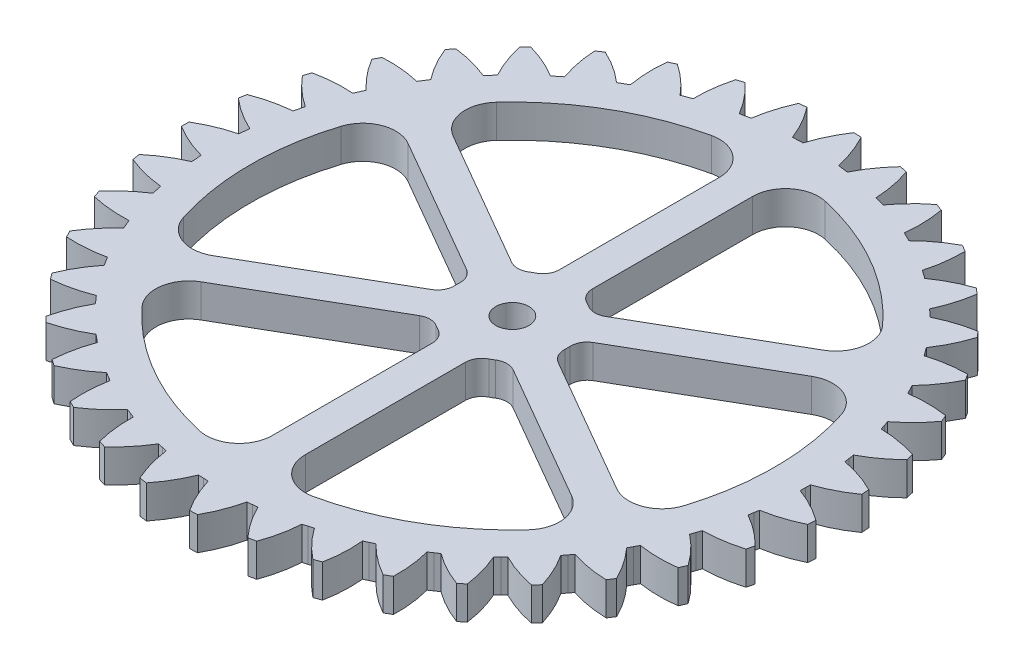
SolidWorks part; units mm, degrees
ref_plane "Front Plane" through (0, 0, 0) normal (0, 0, 1) x (1, 0, 0)
ref_plane "Top Plane" through (0, 0, 0) normal (0, 1, 0) x (1, 0, 0)
ref_plane "Right Plane" through (0, 0, 0) normal (1, 0, 0) x (0, 0, -1)
sketch "Sketch1" plane through (0, 0, 0) normal (0, 1, 0) x (1, 0, 0)
  circle A0 centre (0, 0) radius 28.4436 construction
  circle A1 centre (0, 0) radius 28.4436
sketch "Sketch2" plane through (0, 0, 0) normal (0, 1, 0) x (1, 0, 0)
  line L0 (26.7652, 0) -> (26.7681, 0.253)
  line L1 (26.7681, 0.253) -> (26.8366, 0.2754)
  line L2 (26.8366, 0.2754) -> (26.9069, 0.299)
  line L3 (26.9069, 0.299) -> (26.979, 0.3239)
  line L4 (26.979, 0.3239) -> (27.0527, 0.3502)
  line L5 (27.0527, 0.3502) -> (27.1281, 0.3778)
  line L6 (27.1281, 0.3778) -> (27.2051, 0.4068)
  line L7 (27.2051, 0.4068) -> (27.2839, 0.4372)
  line L8 (27.2839, 0.4372) -> (27.3642, 0.4691)
  line L9 (27.3642, 0.4691) -> (27.4462, 0.5025)
  line L10 (27.4462, 0.5025) -> (27.5297, 0.5374)
  line L11 (27.5297, 0.5374) -> (27.6148, 0.5738)
  line L12 (27.6148, 0.5738) -> (27.7015, 0.6119)
  line L13 (27.7015, 0.6119) -> (27.7897, 0.6515)
  line L14 (27.7897, 0.6515) -> (27.8793, 0.6928)
  line L15 (27.8793, 0.6928) -> (27.9705, 0.7358)
  line L16 (27.9705, 0.7358) -> (28.0631, 0.7804)
  line L17 (28.0631, 0.7804) -> (28.1572, 0.8269)
  line L18 (28.1572, 0.8269) -> (28.2526, 0.875)
  line L19 (28.2526, 0.875) -> (28.3495, 0.925)
  line L20 (28.3495, 0.925) -> (28.4477, 0.9768)
  line L21 (28.4477, 0.9768) -> (28.5472, 1.0304)
  line L22 (28.5472, 1.0304) -> (28.648, 1.0859)
  line L23 (28.648, 1.0859) -> (28.7502, 1.1433)
  line L24 (28.7502, 1.1433) -> (28.8536, 1.2026)
  line L25 (28.8536, 1.2026) -> (28.9582, 1.2639)
  line L26 (28.9582, 1.2639) -> (29.064, 1.3272)
  line L27 (29.064, 1.3272) -> (29.171, 1.3925)
  line L28 (29.171, 1.3925) -> (29.2792, 1.4598)
  line L29 (29.2792, 1.4598) -> (29.3885, 1.5292)
  line L30 (29.3885, 1.5292) -> (29.4988, 1.6007)
  line L31 (29.4988, 1.6007) -> (29.6103, 1.6743)
  line L32 (29.6103, 1.6743) -> (29.7227, 1.75)
  line L33 (29.7227, 1.75) -> (29.8362, 1.8279)
  line L34 (29.8362, 1.8279) -> (29.8433, 1.8329)
  line L35 (29.8433, 1.8329) -> (29.8442, 1.8335)
  line L36 (29.8442, 1.8335) -> (29.8447, 1.8338)
  line L37 (29.8447, 1.8338) -> (29.8449, 1.834)
  line L38 (29.8449, 1.834) -> (29.7947, 2.5211)
  line L39 (29.7947, 2.5211) -> (29.7945, 2.5212)
  line L40 (29.7945, 2.5212) -> (29.794, 2.5214)
  line L41 (29.794, 2.5214) -> (29.793, 2.5219)
  line L42 (29.793, 2.5219) -> (29.7853, 2.5258)
  line L43 (29.7853, 2.5258) -> (29.6617, 2.5864)
  line L44 (29.6617, 2.5864) -> (29.5394, 2.645)
  line L45 (29.5394, 2.645) -> (29.4185, 2.7016)
  line L46 (29.4185, 2.7016) -> (29.2989, 2.7563)
  line L47 (29.2989, 2.7563) -> (29.1807, 2.809)
  line L48 (29.1807, 2.809) -> (29.0639, 2.8599)
  line L49 (29.0639, 2.8599) -> (28.9485, 2.909)
  line L50 (28.9485, 2.909) -> (28.8346, 2.9562)
  line L51 (28.8346, 2.9562) -> (28.7222, 3.0017)
  line L52 (28.7222, 3.0017) -> (28.6113, 3.0454)
  line L53 (28.6113, 3.0454) -> (28.5019, 3.0873)
  line L54 (28.5019, 3.0873) -> (28.3941, 3.1276)
  line L55 (28.3941, 3.1276) -> (28.2878, 3.1662)
  line L56 (28.2878, 3.1662) -> (28.1831, 3.2032)
  line L57 (28.1831, 3.2032) -> (28.08, 3.2385)
  line L58 (28.08, 3.2385) -> (27.9786, 3.2723)
  line L59 (27.9786, 3.2723) -> (27.8788, 3.3046)
  line L60 (27.8788, 3.3046) -> (27.7807, 3.3353)
  line L61 (27.7807, 3.3353) -> (27.6842, 3.3646)
  line L62 (27.6842, 3.3646) -> (27.5895, 3.3924)
  line L63 (27.5895, 3.3924) -> (27.4965, 3.4188)
  line L64 (27.4965, 3.4188) -> (27.4052, 3.4439)
  line L65 (27.4052, 3.4439) -> (27.3157, 3.4676)
  line L66 (27.3157, 3.4676) -> (27.228, 3.49)
  line L67 (27.228, 3.49) -> (27.1421, 3.5111)
  line L68 (27.1421, 3.5111) -> (27.058, 3.531)
  line L69 (27.058, 3.531) -> (26.9757, 3.5496)
  line L70 (26.9757, 3.5496) -> (26.8952, 3.5671)
  line L71 (26.8952, 3.5671) -> (26.8166, 3.5835)
  line L72 (26.8166, 3.5835) -> (26.7398, 3.5987)
  line L73 (26.7398, 3.5987) -> (26.6649, 3.6129)
  line L74 (26.6649, 3.6129) -> (26.592, 3.6261)
  line L75 (26.592, 3.6261) -> (26.5209, 3.6382)
  line L76 (26.5209, 3.6382) -> (26.4813, 3.8882)
  line L77 (26.4813, 3.8882) -> (26.4186, 4.2934)
  line L78 (26.4186, 4.2934) -> (26.3809, 4.5437)
  line L79 (26.3809, 4.5437) -> (26.4449, 4.5767)
  line L80 (26.4449, 4.5767) -> (26.5105, 4.6113)
  line L81 (26.5105, 4.6113) -> (26.5776, 4.6475)
  line L82 (26.5776, 4.6475) -> (26.6462, 4.6852)
  line L83 (26.6462, 4.6852) -> (26.7162, 4.7245)
  line L84 (26.7162, 4.7245) -> (26.7876, 4.7655)
  line L85 (26.7876, 4.7655) -> (26.8604, 4.8082)
  line L86 (26.8604, 4.8082) -> (26.9346, 4.8526)
  line L87 (26.9346, 4.8526) -> (27.0101, 4.8986)
  line L88 (27.0101, 4.8986) -> (27.087, 4.9465)
  line L89 (27.087, 4.9465) -> (27.1652, 4.9961)
  line L90 (27.1652, 4.9961) -> (27.2446, 5.0476)
  line L91 (27.2446, 5.0476) -> (27.3253, 5.1009)
  line L92 (27.3253, 5.1009) -> (27.4072, 5.156)
  line L93 (27.4072, 5.156) -> (27.4903, 5.213)
  line L94 (27.4903, 5.213) -> (27.5745, 5.272)
  line L95 (27.5745, 5.272) -> (27.6599, 5.3329)
  line L96 (27.6599, 5.3329) -> (27.7464, 5.3957)
  line L97 (27.7464, 5.3957) -> (27.834, 5.4606)
  line L98 (27.834, 5.4606) -> (27.9226, 5.5274)
  line L99 (27.9226, 5.5274) -> (28.0122, 5.5963)
  line L100 (28.0122, 5.5963) -> (28.1029, 5.6673)
  line L101 (28.1029, 5.6673) -> (28.1945, 5.7403)
  line L102 (28.1945, 5.7403) -> (28.287, 5.8155)
  line L103 (28.287, 5.8155) -> (28.3804, 5.8928)
  line L104 (28.3804, 5.8928) -> (28.4748, 5.9722)
  line L105 (28.4748, 5.9722) -> (28.5699, 6.0538)
  line L106 (28.5699, 6.0538) -> (28.6659, 6.1376)
  line L107 (28.6659, 6.1376) -> (28.7626, 6.2237)
  line L108 (28.7626, 6.2237) -> (28.8601, 6.3119)
  line L109 (28.8601, 6.3119) -> (28.9583, 6.4024)
  line L110 (28.9583, 6.4024) -> (29.0571, 6.4952)
  line L111 (29.0571, 6.4952) -> (29.1566, 6.5903)
  line L112 (29.1566, 6.5903) -> (29.1629, 6.5963)
  line L113 (29.1629, 6.5963) -> (29.1637, 6.5971)
  line L114 (29.1637, 6.5971) -> (29.164, 6.5975)
  line L115 (29.164, 6.5975) -> (29.1642, 6.5977)
  line L116 (29.1642, 6.5977) -> (29.0045, 7.2678)
  line L117 (29.0045, 7.2678) -> (29.0042, 7.2679)
  line L118 (29.0042, 7.2679) -> (29.0037, 7.2681)
  line L119 (29.0037, 7.2681) -> (29.0027, 7.2684)
  line L120 (29.0027, 7.2684) -> (28.9944, 7.271)
  line L121 (28.9944, 7.271) -> (28.8627, 7.3109)
  line L122 (28.8627, 7.3109) -> (28.7326, 7.3491)
  line L123 (28.7326, 7.3491) -> (28.6041, 7.3856)
  line L124 (28.6041, 7.3856) -> (28.4773, 7.4204)
  line L125 (28.4773, 7.4204) -> (28.3522, 7.4536)
  line L126 (28.3522, 7.4536) -> (28.2287, 7.4851)
  line L127 (28.2287, 7.4851) -> (28.107, 7.515)
  line L128 (28.107, 7.515) -> (27.987, 7.5434)
  line L129 (27.987, 7.5434) -> (27.8688, 7.5702)
  line L130 (27.8688, 7.5702) -> (27.7523, 7.5955)
  line L131 (27.7523, 7.5955) -> (27.6376, 7.6194)
  line L132 (27.6376, 7.6194) -> (27.5247, 7.6418)
  line L133 (27.5247, 7.6418) -> (27.4136, 7.6629)
  line L134 (27.4136, 7.6629) -> (27.3043, 7.6826)
  line L135 (27.3043, 7.6826) -> (27.1969, 7.7009)
  line L136 (27.1969, 7.7009) -> (27.0914, 7.718)
  line L137 (27.0914, 7.718) -> (26.9877, 7.7338)
  line L138 (26.9877, 7.7338) -> (26.8859, 7.7484)
  line L139 (26.8859, 7.7484) -> (26.786, 7.7619)
  line L140 (26.786, 7.7619) -> (26.688, 7.7741)
  line L141 (26.688, 7.7741) -> (26.592, 7.7853)
  line L142 (26.592, 7.7853) -> (26.4979, 7.7954)
  line L143 (26.4979, 7.7954) -> (26.4058, 7.8044)
  line L144 (26.4058, 7.8044) -> (26.3156, 7.8125)
  line L145 (26.3156, 7.8125) -> (26.2274, 7.8195)
  line L146 (26.2274, 7.8195) -> (26.1412, 7.8256)
  line L147 (26.1412, 7.8256) -> (26.0569, 7.8309)
  line L148 (26.0569, 7.8309) -> (25.9747, 7.8352)
  line L149 (25.9747, 7.8352) -> (25.8945, 7.8388)
  line L150 (25.8945, 7.8388) -> (25.8163, 7.8415)
  line L151 (25.8163, 7.8415) -> (25.7401, 7.8435)
  line L152 (25.7401, 7.8435) -> (25.6659, 7.8448)
  line L153 (25.6659, 7.8448) -> (25.5938, 7.8454)
  line L154 (25.5938, 7.8454) -> (25.5147, 8.0857)
  line L155 (25.5147, 8.0857) -> (25.3878, 8.4757)
  line L156 (25.3878, 8.4757) -> (25.3104, 8.7166)
  line L157 (25.3104, 8.7166) -> (25.3683, 8.7595)
  line L158 (25.3683, 8.7595) -> (25.4275, 8.8042)
  line L159 (25.4275, 8.8042) -> (25.4879, 8.8506)
  line L160 (25.4879, 8.8506) -> (25.5496, 8.8989)
  line L161 (25.5496, 8.8989) -> (25.6123, 8.9489)
  line L162 (25.6123, 8.9489) -> (25.6763, 9.0008)
  line L163 (25.6763, 9.0008) -> (25.7413, 9.0546)
  line L164 (25.7413, 9.0546) -> (25.8074, 9.1103)
  line L165 (25.8074, 9.1103) -> (25.8746, 9.1679)
  line L166 (25.8746, 9.1679) -> (25.9428, 9.2275)
  line L167 (25.9428, 9.2275) -> (26.0119, 9.289)
  line L168 (26.0119, 9.289) -> (26.0821, 9.3525)
  line L169 (26.0821, 9.3525) -> (26.1532, 9.4181)
  line L170 (26.1532, 9.4181) -> (26.2252, 9.4856)
  line L171 (26.2252, 9.4856) -> (26.298, 9.5553)
  line L172 (26.298, 9.5553) -> (26.3717, 9.627)
  line L173 (26.3717, 9.627) -> (26.4463, 9.7008)
  line L174 (26.4463, 9.7008) -> (26.5215, 9.7767)
  line L175 (26.5215, 9.7767) -> (26.5976, 9.8547)
  line L176 (26.5976, 9.8547) -> (26.6743, 9.935)
  line L177 (26.6743, 9.935) -> (26.7518, 10.0173)
  line L178 (26.7518, 10.0173) -> (26.8299, 10.1019)
  line L179 (26.8299, 10.1019) -> (26.9086, 10.1887)
  line L180 (26.9086, 10.1887) -> (26.9878, 10.2777)
  line L181 (26.9878, 10.2777) -> (27.0677, 10.369)
  line L182 (27.0677, 10.369) -> (27.148, 10.4626)
  line L183 (27.148, 10.4626) -> (27.2288, 10.5584)
  line L184 (27.2288, 10.5584) -> (27.3101, 10.6565)
  line L185 (27.3101, 10.6565) -> (27.3918, 10.7569)
  line L186 (27.3918, 10.7569) -> (27.4738, 10.8597)
  line L187 (27.4738, 10.8597) -> (27.5562, 10.9648)
  line L188 (27.5562, 10.9648) -> (27.6389, 11.0722)
  line L189 (27.6389, 11.0722) -> (27.7219, 11.182)
  line L190 (27.7219, 11.182) -> (27.7271, 11.189)
  line L191 (27.7271, 11.189) -> (27.7277, 11.1899)
  line L192 (27.7277, 11.1899) -> (27.7281, 11.1903)
  line L193 (27.7281, 11.1903) -> (27.7282, 11.1905)
  line L194 (27.7282, 11.1905) -> (27.463, 11.8264)
  line L195 (27.463, 11.8264) -> (27.4628, 11.8264)
  line L196 (27.4628, 11.8264) -> (27.4622, 11.8265)
  line L197 (27.4622, 11.8265) -> (27.4612, 11.8266)
  line L198 (27.4612, 11.8266) -> (27.4526, 11.8278)
  line L199 (27.4526, 11.8278) -> (27.3162, 11.8462)
  line L200 (27.3162, 11.8462) -> (27.1816, 11.863)
  line L201 (27.1816, 11.863) -> (27.049, 11.8784)
  line L202 (27.049, 11.8784) -> (26.9182, 11.8924)
  line L203 (26.9182, 11.8924) -> (26.7894, 11.9051)
  line L204 (26.7894, 11.9051) -> (26.6625, 11.9164)
  line L205 (26.6625, 11.9164) -> (26.5375, 11.9264)
  line L206 (26.5375, 11.9264) -> (26.4145, 11.9351)
  line L207 (26.4145, 11.9351) -> (26.2935, 11.9426)
  line L208 (26.2935, 11.9426) -> (26.1745, 11.9489)
  line L209 (26.1745, 11.9489) -> (26.0574, 11.9541)
  line L210 (26.0574, 11.9541) -> (25.9424, 11.9581)
  line L211 (25.9424, 11.9581) -> (25.8294, 11.9611)
  line L212 (25.8294, 11.9611) -> (25.7184, 11.963)
  line L213 (25.7184, 11.963) -> (25.6094, 11.9639)
  line L214 (25.6094, 11.9639) -> (25.5025, 11.9638)
  line L215 (25.5025, 11.9638) -> (25.3976, 11.9628)
  line L216 (25.3976, 11.9628) -> (25.2948, 11.9609)
  line L217 (25.2948, 11.9609) -> (25.194, 11.9581)
  line L218 (25.194, 11.9581) -> (25.0954, 11.9545)
  line L219 (25.0954, 11.9545) -> (24.9988, 11.9501)
  line L220 (24.9988, 11.9501) -> (24.9043, 11.945)
  line L221 (24.9043, 11.945) -> (24.8119, 11.9391)
  line L222 (24.8119, 11.9391) -> (24.7216, 11.9326)
  line L223 (24.7216, 11.9326) -> (24.6334, 11.9254)
  line L224 (24.6334, 11.9254) -> (24.5473, 11.9176)
  line L225 (24.5473, 11.9176) -> (24.4633, 11.9093)
  line L226 (24.4633, 11.9093) -> (24.3815, 11.9004)
  line L227 (24.3815, 11.9004) -> (24.3017, 11.891)
  line L228 (24.3017, 11.891) -> (24.2241, 11.8812)
  line L229 (24.2241, 11.8812) -> (24.1486, 11.8709)
  line L230 (24.1486, 11.8709) -> (24.0752, 11.8603)
  line L231 (24.0752, 11.8603) -> (24.0039, 11.8493)
  line L232 (24.0039, 11.8493) -> (23.8872, 12.0739)
  line L233 (23.8872, 12.0739) -> (23.6994, 12.4384)
  line L234 (23.6994, 12.4384) -> (23.5844, 12.6638)
  line L235 (23.5844, 12.6638) -> (23.6347, 12.7155)
  line L236 (23.6347, 12.7155) -> (23.686, 12.769)
  line L237 (23.686, 12.769) -> (23.7381, 12.8246)
  line L238 (23.7381, 12.8246) -> (23.7912, 12.8821)
  line L239 (23.7912, 12.8821) -> (23.8452, 12.9416)
  line L240 (23.8452, 12.9416) -> (23.8999, 13.0031)
  line L241 (23.8999, 13.0031) -> (23.9555, 13.0666)
  line L242 (23.9555, 13.0666) -> (24.0118, 13.1322)
  line L243 (24.0118, 13.1322) -> (24.0689, 13.1998)
  line L244 (24.0689, 13.1998) -> (24.1266, 13.2695)
  line L245 (24.1266, 13.2695) -> (24.185, 13.3413)
  line L246 (24.185, 13.3413) -> (24.2441, 13.4153)
  line L247 (24.2441, 13.4153) -> (24.3037, 13.4914)
  line L248 (24.3037, 13.4914) -> (24.364, 13.5696)
  line L249 (24.364, 13.5696) -> (24.4247, 13.65)
  line L250 (24.4247, 13.65) -> (24.486, 13.7326)
  line L251 (24.486, 13.7326) -> (24.5477, 13.8174)
  line L252 (24.5477, 13.8174) -> (24.6098, 13.9044)
  line L253 (24.6098, 13.9044) -> (24.6723, 13.9937)
  line L254 (24.6723, 13.9937) -> (24.7352, 14.0852)
  line L255 (24.7352, 14.0852) -> (24.7984, 14.1789)
  line L256 (24.7984, 14.1789) -> (24.862, 14.2749)
  line L257 (24.862, 14.2749) -> (24.9257, 14.3732)
  line L258 (24.9257, 14.3732) -> (24.9897, 14.4738)
  line L259 (24.9897, 14.4738) -> (25.0538, 14.5767)
  line L260 (25.0538, 14.5767) -> (25.1181, 14.6819)
  line L261 (25.1181, 14.6819) -> (25.1825, 14.7895)
  line L262 (25.1825, 14.7895) -> (25.247, 14.8993)
  line L263 (25.247, 14.8993) -> (25.3115, 15.0116)
  line L264 (25.3115, 15.0116) -> (25.376, 15.1261)
  line L265 (25.376, 15.1261) -> (25.4405, 15.2431)
  line L266 (25.4405, 15.2431) -> (25.5049, 15.3624)
  line L267 (25.5049, 15.3624) -> (25.5692, 15.4841)
  line L268 (25.5692, 15.4841) -> (25.5732, 15.4918)
  line L269 (25.5732, 15.4918) -> (25.5737, 15.4928)
  line L270 (25.5737, 15.4928) -> (25.5739, 15.4933)
  line L271 (25.5739, 15.4933) -> (25.5741, 15.4935)
  line L272 (25.5741, 15.4935) -> (25.2103, 16.0786)
  line L273 (25.2103, 16.0786) -> (25.2101, 16.0786)
  line L274 (25.2101, 16.0786) -> (25.2095, 16.0786)
  line L275 (25.2095, 16.0786) -> (25.2084, 16.0786)
  line L276 (25.2084, 16.0786) -> (25.1998, 16.0784)
  line L277 (25.1998, 16.0784) -> (25.0622, 16.0746)
  line L278 (25.0622, 16.0746) -> (24.9267, 16.0696)
  line L279 (24.9267, 16.0696) -> (24.7933, 16.0636)
  line L280 (24.7933, 16.0636) -> (24.662, 16.0564)
  line L281 (24.662, 16.0564) -> (24.5328, 16.0482)
  line L282 (24.5328, 16.0482) -> (24.4057, 16.039)
  line L283 (24.4057, 16.039) -> (24.2808, 16.0288)
  line L284 (24.2808, 16.0288) -> (24.158, 16.0177)
  line L285 (24.158, 16.0177) -> (24.0373, 16.0057)
  line L286 (24.0373, 16.0057) -> (23.9188, 15.9929)
  line L287 (23.9188, 15.9929) -> (23.8024, 15.9792)
  line L288 (23.8024, 15.9792) -> (23.6882, 15.9647)
  line L289 (23.6882, 15.9647) -> (23.5762, 15.9495)
  line L290 (23.5762, 15.9495) -> (23.4663, 15.9336)
  line L291 (23.4663, 15.9336) -> (23.3586, 15.917)
  line L292 (23.3586, 15.917) -> (23.2531, 15.8998)
  line L293 (23.2531, 15.8998) -> (23.1497, 15.882)
  line L294 (23.1497, 15.882) -> (23.0486, 15.8636)
  line L295 (23.0486, 15.8636) -> (22.9496, 15.8447)
  line L296 (22.9496, 15.8447) -> (22.8528, 15.8253)
  line L297 (22.8528, 15.8253) -> (22.7581, 15.8055)
  line L298 (22.7581, 15.8055) -> (22.6657, 15.7852)
  line L299 (22.6657, 15.7852) -> (22.5754, 15.7646)
  line L300 (22.5754, 15.7646) -> (22.4873, 15.7437)
  line L301 (22.4873, 15.7437) -> (22.4014, 15.7225)
  line L302 (22.4014, 15.7225) -> (22.3177, 15.701)
  line L303 (22.3177, 15.701) -> (22.2362, 15.6792)
  line L304 (22.2362, 15.6792) -> (22.1568, 15.6574)
  line L305 (22.1568, 15.6574) -> (22.0796, 15.6353)
  line L306 (22.0796, 15.6353) -> (22.0045, 15.6131)
  line L307 (22.0045, 15.6131) -> (21.9316, 15.5909)
  line L308 (21.9316, 15.5909) -> (21.8609, 15.5686)
  line L309 (21.8609, 15.5686) -> (21.7923, 15.5464)
  line L310 (21.7923, 15.5464) -> (21.6411, 15.7493)
  line L311 (21.6411, 15.7493) -> (21.3973, 16.079)
  line L312 (21.3973, 16.079) -> (21.2475, 16.283)
  line L313 (21.2475, 16.283) -> (21.2889, 16.3421)
  line L314 (21.2889, 16.3421) -> (21.3309, 16.4032)
  line L315 (21.3309, 16.4032) -> (21.3735, 16.4664)
  line L316 (21.3735, 16.4664) -> (21.4167, 16.5316)
  line L317 (21.4167, 16.5316) -> (21.4604, 16.599)
  line L318 (21.4604, 16.599) -> (21.5046, 16.6685)
  line L319 (21.5046, 16.6685) -> (21.5492, 16.7401)
  line L320 (21.5492, 16.7401) -> (21.5943, 16.8139)
  line L321 (21.5943, 16.8139) -> (21.6398, 16.8898)
  line L322 (21.6398, 16.8898) -> (21.6856, 16.9679)
  line L323 (21.6856, 16.9679) -> (21.7317, 17.0481)
  line L324 (21.7317, 17.0481) -> (21.7782, 17.1306)
  line L325 (21.7782, 17.1306) -> (21.8248, 17.2153)
  line L326 (21.8248, 17.2153) -> (21.8717, 17.3022)
  line L327 (21.8717, 17.3022) -> (21.9188, 17.3913)
  line L328 (21.9188, 17.3913) -> (21.966, 17.4826)
  line L329 (21.966, 17.4826) -> (22.0133, 17.5762)
  line L330 (22.0133, 17.5762) -> (22.0607, 17.6721)
  line L331 (22.0607, 17.6721) -> (22.1081, 17.7702)
  line L332 (22.1081, 17.7702) -> (22.1555, 17.8706)
  line L333 (22.1555, 17.8706) -> (22.2029, 17.9732)
  line L334 (22.2029, 17.9732) -> (22.2501, 18.0782)
  line L335 (22.2501, 18.0782) -> (22.2973, 18.1854)
  line L336 (22.2973, 18.1854) -> (22.3443, 18.295)
  line L337 (22.3443, 18.295) -> (22.3911, 18.4069)
  line L338 (22.3911, 18.4069) -> (22.4377, 18.521)
  line L339 (22.4377, 18.521) -> (22.484, 18.6375)
  line L340 (22.484, 18.6375) -> (22.5301, 18.7563)
  line L341 (22.5301, 18.7563) -> (22.5757, 18.8774)
  line L342 (22.5757, 18.8774) -> (22.621, 19.0009)
  line L343 (22.621, 19.0009) -> (22.6659, 19.1267)
  line L344 (22.6659, 19.1267) -> (22.7103, 19.2548)
  line L345 (22.7103, 19.2548) -> (22.7542, 19.3852)
  line L346 (22.7542, 19.3852) -> (22.757, 19.3934)
  line L347 (22.757, 19.3934) -> (22.7573, 19.3945)
  line L348 (22.7573, 19.3945) -> (22.7575, 19.395)
  line L349 (22.7575, 19.395) -> (22.7576, 19.3952)
  line L350 (22.7576, 19.3952) -> (22.3047, 19.9144)
  line L351 (22.3047, 19.9144) -> (22.3044, 19.9144)
  line L352 (22.3044, 19.9144) -> (22.3039, 19.9143)
  line L353 (22.3039, 19.9143) -> (22.3028, 19.9141)
  line L354 (22.3028, 19.9141) -> (22.2943, 19.9125)
  line L355 (22.2943, 19.9125) -> (22.1591, 19.8867)
  line L356 (22.1591, 19.8867) -> (22.0261, 19.86)
  line L357 (22.0261, 19.86) -> (21.8954, 19.8327)
  line L358 (21.8954, 19.8327) -> (21.767, 19.8045)
  line L359 (21.767, 19.8045) -> (21.6408, 19.7757)
  line L360 (21.6408, 19.7757) -> (21.5168, 19.7463)
  line L361 (21.5168, 19.7463) -> (21.3951, 19.7162)
  line L362 (21.3951, 19.7162) -> (21.2757, 19.6855)
  line L363 (21.2757, 19.6855) -> (21.1585, 19.6543)
  line L364 (21.1585, 19.6543) -> (21.0436, 19.6226)
  line L365 (21.0436, 19.6226) -> (20.9309, 19.5904)
  line L366 (20.9309, 19.5904) -> (20.8205, 19.5579)
  line L367 (20.8205, 19.5579) -> (20.7124, 19.5249)
  line L368 (20.7124, 19.5249) -> (20.6065, 19.4915)
  line L369 (20.6065, 19.4915) -> (20.5029, 19.4579)
  line L370 (20.5029, 19.4579) -> (20.4015, 19.4239)
  line L371 (20.4015, 19.4239) -> (20.3023, 19.3898)
  line L372 (20.3023, 19.3898) -> (20.2054, 19.3554)
  line L373 (20.2054, 19.3554) -> (20.1107, 19.3209)
  line L374 (20.1107, 19.3209) -> (20.0183, 19.2862)
  line L375 (20.0183, 19.2862) -> (19.928, 19.2515)
  line L376 (19.928, 19.2515) -> (19.84, 19.2167)
  line L377 (19.84, 19.2167) -> (19.7543, 19.1818)
  line L378 (19.7543, 19.1818) -> (19.6707, 19.147)
  line L379 (19.6707, 19.147) -> (19.5893, 19.1123)
  line L380 (19.5893, 19.1123) -> (19.5101, 19.0777)
  line L381 (19.5101, 19.0777) -> (19.4331, 19.0431)
  line L382 (19.4331, 19.0431) -> (19.3582, 19.0088)
  line L383 (19.3582, 19.0088) -> (19.2856, 18.9746)
  line L384 (19.2856, 18.9746) -> (19.215, 18.9407)
  line L385 (19.215, 18.9407) -> (19.1467, 18.9071)
  line L386 (19.1467, 18.9071) -> (19.0804, 18.8738)
  line L387 (19.0804, 18.8738) -> (19.0163, 18.8408)
  line L388 (19.0163, 18.8408) -> (18.8345, 19.0168)
  line L389 (18.8345, 19.0168) -> (18.5409, 19.3031)
  line L390 (18.5409, 19.3031) -> (18.3604, 19.4805)
  line L391 (18.3604, 19.4805) -> (18.3918, 19.5454)
  line L392 (18.3918, 19.5454) -> (18.4234, 19.6125)
  line L393 (18.4234, 19.6125) -> (18.4554, 19.6817)
  line L394 (18.4554, 19.6817) -> (18.4875, 19.753)
  line L395 (18.4875, 19.753) -> (18.5198, 19.8265)
  line L396 (18.5198, 19.8265) -> (18.5523, 19.9022)
  line L397 (18.5523, 19.9022) -> (18.5849, 19.9801)
  line L398 (18.5849, 19.9801) -> (18.6175, 20.0601)
  line L399 (18.6175, 20.0601) -> (18.6502, 20.1423)
  line L400 (18.6502, 20.1423) -> (18.6829, 20.2268)
  line L401 (18.6829, 20.2268) -> (18.7156, 20.3134)
  line L402 (18.7156, 20.3134) -> (18.7482, 20.4022)
  line L403 (18.7482, 20.4022) -> (18.7807, 20.4933)
  line L404 (18.7807, 20.4933) -> (18.813, 20.5866)
  line L405 (18.813, 20.5866) -> (18.8452, 20.6821)
  line L406 (18.8452, 20.6821) -> (18.8771, 20.7798)
  line L407 (18.8771, 20.7798) -> (18.9088, 20.8798)
  line L408 (18.9088, 20.8798) -> (18.9402, 20.982)
  line L409 (18.9402, 20.982) -> (18.9713, 21.0865)
  line L410 (18.9713, 21.0865) -> (19.0019, 21.1931)
  line L411 (19.0019, 21.1931) -> (19.0322, 21.3021)
  line L412 (19.0322, 21.3021) -> (19.0621, 21.4133)
  line L413 (19.0621, 21.4133) -> (19.0914, 21.5267)
  line L414 (19.0914, 21.5267) -> (19.1202, 21.6424)
  line L415 (19.1202, 21.6424) -> (19.1485, 21.7603)
  line L416 (19.1485, 21.7603) -> (19.1762, 21.8804)
  line L417 (19.1762, 21.8804) -> (19.2032, 22.0028)
  line L418 (19.2032, 22.0028) -> (19.2296, 22.1275)
  line L419 (19.2296, 22.1275) -> (19.2552, 22.2544)
  line L420 (19.2552, 22.2544) -> (19.2801, 22.3835)
  line L421 (19.2801, 22.3835) -> (19.3042, 22.5148)
  line L422 (19.3042, 22.5148) -> (19.3275, 22.6484)
  line L423 (19.3275, 22.6484) -> (19.35, 22.7842)
  line L424 (19.35, 22.7842) -> (19.3513, 22.7928)
  line L425 (19.3513, 22.7928) -> (19.3515, 22.7938)
  line L426 (19.3515, 22.7938) -> (19.3516, 22.7944)
  line L427 (19.3516, 22.7944) -> (19.3516, 22.7946)
  line L428 (19.3516, 22.7946) -> (18.8213, 23.2344)
  line L429 (18.8213, 23.2344) -> (18.8211, 23.2344)
  line L430 (18.8211, 23.2344) -> (18.8206, 23.2342)
  line L431 (18.8206, 23.2342) -> (18.8195, 23.2338)
  line L432 (18.8195, 23.2338) -> (18.8114, 23.2309)
  line L433 (18.8114, 23.2309) -> (18.6821, 23.1837)
  line L434 (18.6821, 23.1837) -> (18.5551, 23.1361)
  line L435 (18.5551, 23.1361) -> (18.4305, 23.0881)
  line L436 (18.4305, 23.0881) -> (18.3082, 23.0397)
  line L437 (18.3082, 23.0397) -> (18.1883, 22.9911)
  line L438 (18.1883, 22.9911) -> (18.0707, 22.9421)
  line L439 (18.0707, 22.9421) -> (17.9554, 22.8929)
  line L440 (17.9554, 22.8929) -> (17.8424, 22.8435)
  line L441 (17.8424, 22.8435) -> (17.7317, 22.7939)
  line L442 (17.7317, 22.7939) -> (17.6234, 22.7441)
  line L443 (17.6234, 22.7441) -> (17.5174, 22.6943)
  line L444 (17.5174, 22.6943) -> (17.4136, 22.6444)
  line L445 (17.4136, 22.6444) -> (17.3122, 22.5945)
  line L446 (17.3122, 22.5945) -> (17.213, 22.5446)
  line L447 (17.213, 22.5446) -> (17.1161, 22.4948)
  line L448 (17.1161, 22.4948) -> (17.0214, 22.445)
  line L449 (17.0214, 22.445) -> (16.9291, 22.3954)
  line L450 (16.9291, 22.3954) -> (16.8389, 22.3459)
  line L451 (16.8389, 22.3459) -> (16.751, 22.2967)
  line L452 (16.751, 22.2967) -> (16.6653, 22.2476)
  line L453 (16.6653, 22.2476) -> (16.5818, 22.1988)
  line L454 (16.5818, 22.1988) -> (16.5006, 22.1504)
  line L455 (16.5006, 22.1504) -> (16.4215, 22.1022)
  line L456 (16.4215, 22.1022) -> (16.3445, 22.0545)
  line L457 (16.3445, 22.0545) -> (16.2698, 22.0071)
  line L458 (16.2698, 22.0071) -> (16.1972, 21.9602)
  line L459 (16.1972, 21.9602) -> (16.1267, 21.9138)
  line L460 (16.1267, 21.9138) -> (16.0583, 21.8679)
  line L461 (16.0583, 21.8679) -> (15.9921, 21.8225)
  line L462 (15.9921, 21.8225) -> (15.9279, 21.7778)
  line L463 (15.9279, 21.7778) -> (15.8658, 21.7336)
  line L464 (15.8658, 21.7336) -> (15.8058, 21.6901)
  line L465 (15.8058, 21.6901) -> (15.7478, 21.6472)
  line L466 (15.7478, 21.6472) -> (15.5401, 21.7918)
  line L467 (15.5401, 21.7918) -> (15.2044, 22.0273)
  line L468 (15.2044, 22.0273) -> (14.9978, 22.1735)
  line L469 (14.9978, 22.1735) -> (15.0183, 22.2426)
  line L470 (15.0183, 22.2426) -> (15.0388, 22.3138)
  line L471 (15.0388, 22.3138) -> (15.0592, 22.3873)
  line L472 (15.0592, 22.3873) -> (15.0795, 22.4628)
  line L473 (15.0795, 22.4628) -> (15.0996, 22.5406)
  line L474 (15.0996, 22.5406) -> (15.1195, 22.6205)
  line L475 (15.1195, 22.6205) -> (15.1392, 22.7025)
  line L476 (15.1392, 22.7025) -> (15.1586, 22.7868)
  line L477 (15.1586, 22.7868) -> (15.1777, 22.8732)
  line L478 (15.1777, 22.8732) -> (15.1964, 22.9618)
  line L479 (15.1964, 22.9618) -> (15.2148, 23.0525)
  line L480 (15.2148, 23.0525) -> (15.2327, 23.1454)
  line L481 (15.2327, 23.1454) -> (15.2501, 23.2405)
  line L482 (15.2501, 23.2405) -> (15.2671, 23.3378)
  line L483 (15.2671, 23.3378) -> (15.2835, 23.4372)
  line L484 (15.2835, 23.4372) -> (15.2994, 23.5388)
  line L485 (15.2994, 23.5388) -> (15.3146, 23.6426)
  line L486 (15.3146, 23.6426) -> (15.3292, 23.7485)
  line L487 (15.3292, 23.7485) -> (15.3431, 23.8566)
  line L488 (15.3431, 23.8566) -> (15.3563, 23.9668)
  line L489 (15.3563, 23.9668) -> (15.3687, 24.0792)
  line L490 (15.3687, 24.0792) -> (15.3803, 24.1937)
  line L491 (15.3803, 24.1937) -> (15.3911, 24.3104)
  line L492 (15.3911, 24.3104) -> (15.401, 24.4292)
  line L493 (15.401, 24.4292) -> (15.4099, 24.5501)
  line L494 (15.4099, 24.5501) -> (15.418, 24.6732)
  line L495 (15.418, 24.6732) -> (15.425, 24.7983)
  line L496 (15.425, 24.7983) -> (15.4311, 24.9256)
  line L497 (15.4311, 24.9256) -> (15.436, 25.0549)
  line L498 (15.436, 25.0549) -> (15.4399, 25.1864)
  line L499 (15.4399, 25.1864) -> (15.4426, 25.3199)
  line L500 (15.4426, 25.3199) -> (15.4442, 25.4555)
  line L501 (15.4442, 25.4555) -> (15.4445, 25.5931)
  line L502 (15.4445, 25.5931) -> (15.4445, 25.6018)
  line L503 (15.4445, 25.6018) -> (15.4445, 25.6029)
  line L504 (15.4445, 25.6029) -> (15.4445, 25.6034)
  line L505 (15.4445, 25.6034) -> (15.4445, 25.6037)
  line L506 (15.4445, 25.6037) -> (14.8505, 25.9527)
  line L507 (14.8505, 25.9527) -> (14.8503, 25.9526)
  line L508 (14.8503, 25.9526) -> (14.8498, 25.9523)
  line L509 (14.8498, 25.9523) -> (14.8489, 25.9518)
  line L510 (14.8489, 25.9518) -> (14.8413, 25.9476)
  line L511 (14.8413, 25.9476) -> (14.7212, 25.8803)
  line L512 (14.7212, 25.8803) -> (14.6035, 25.8129)
  line L513 (14.6035, 25.8129) -> (14.4882, 25.7456)
  line L514 (14.4882, 25.7456) -> (14.3753, 25.6782)
  line L515 (14.3753, 25.6782) -> (14.2647, 25.6109)
  line L516 (14.2647, 25.6109) -> (14.1565, 25.5437)
  line L517 (14.1565, 25.5437) -> (14.0506, 25.4767)
  line L518 (14.0506, 25.4767) -> (13.947, 25.4098)
  line L519 (13.947, 25.4098) -> (13.8457, 25.3431)
  line L520 (13.8457, 25.3431) -> (13.7468, 25.2766)
  line L521 (13.7468, 25.2766) -> (13.6501, 25.2104)
  line L522 (13.6501, 25.2104) -> (13.5557, 25.1445)
  line L523 (13.5557, 25.1445) -> (13.4636, 25.079)
  line L524 (13.4636, 25.079) -> (13.3737, 25.0138)
  line L525 (13.3737, 25.0138) -> (13.286, 24.9491)
  line L526 (13.286, 24.9491) -> (13.2006, 24.8848)
  line L527 (13.2006, 24.8848) -> (13.1174, 24.821)
  line L528 (13.1174, 24.821) -> (13.0363, 24.7577)
  line L529 (13.0363, 24.7577) -> (12.9574, 24.695)
  line L530 (12.9574, 24.695) -> (12.8807, 24.6328)
  line L531 (12.8807, 24.6328) -> (12.8062, 24.5713)
  line L532 (12.8062, 24.5713) -> (12.7337, 24.5104)
  line L533 (12.7337, 24.5104) -> (12.6634, 24.4502)
  line L534 (12.6634, 24.4502) -> (12.5951, 24.3907)
  line L535 (12.5951, 24.3907) -> (12.5289, 24.332)
  line L536 (12.5289, 24.332) -> (12.4648, 24.2741)
  line L537 (12.4648, 24.2741) -> (12.4026, 24.2169)
  line L538 (12.4026, 24.2169) -> (12.3425, 24.1607)
  line L539 (12.3425, 24.1607) -> (12.2844, 24.1053)
  line L540 (12.2844, 24.1053) -> (12.2282, 24.0508)
  line L541 (12.2282, 24.0508) -> (12.174, 23.9972)
  line L542 (12.174, 23.9972) -> (12.1218, 23.9446)
  line L543 (12.1218, 23.9446) -> (12.0714, 23.893)
  line L544 (12.0714, 23.893) -> (11.8432, 24.0024)
  line L545 (11.8432, 24.0024) -> (11.474, 24.181)
  line L546 (11.474, 24.181) -> (11.2467, 24.2921)
  line L547 (11.2467, 24.2921) -> (11.2559, 24.3636)
  line L548 (11.2559, 24.3636) -> (11.2647, 24.4373)
  line L549 (11.2647, 24.4373) -> (11.273, 24.513)
  line L550 (11.273, 24.513) -> (11.2809, 24.5909)
  line L551 (11.2809, 24.5909) -> (11.2883, 24.6708)
  line L552 (11.2883, 24.6708) -> (11.2951, 24.7529)
  line L553 (11.2951, 24.7529) -> (11.3014, 24.8371)
  line L554 (11.3014, 24.8371) -> (11.307, 24.9233)
  line L555 (11.307, 24.9233) -> (11.312, 25.0117)
  line L556 (11.312, 25.0117) -> (11.3163, 25.1021)
  line L557 (11.3163, 25.1021) -> (11.3198, 25.1946)
  line L558 (11.3198, 25.1946) -> (11.3226, 25.2892)
  line L559 (11.3226, 25.2892) -> (11.3246, 25.3859)
  line L560 (11.3246, 25.3859) -> (11.3257, 25.4846)
  line L561 (11.3257, 25.4846) -> (11.326, 25.5854)
  line L562 (11.326, 25.5854) -> (11.3253, 25.6882)
  line L563 (11.3253, 25.6882) -> (11.3237, 25.7931)
  line L564 (11.3237, 25.7931) -> (11.3211, 25.9)
  line L565 (11.3211, 25.9) -> (11.3175, 26.0089)
  line L566 (11.3175, 26.0089) -> (11.3128, 26.1198)
  line L567 (11.3128, 26.1198) -> (11.3071, 26.2327)
  line L568 (11.3071, 26.2327) -> (11.3002, 26.3476)
  line L569 (11.3002, 26.3476) -> (11.2921, 26.4645)
  line L570 (11.2921, 26.4645) -> (11.2828, 26.5833)
  line L571 (11.2828, 26.5833) -> (11.2723, 26.7041)
  line L572 (11.2723, 26.7041) -> (11.2605, 26.8269)
  line L573 (11.2605, 26.8269) -> (11.2473, 26.9515)
  line L574 (11.2473, 26.9515) -> (11.2329, 27.0781)
  line L575 (11.2329, 27.0781) -> (11.217, 27.2066)
  line L576 (11.217, 27.2066) -> (11.1998, 27.337)
  line L577 (11.1998, 27.337) -> (11.1811, 27.4692)
  line L578 (11.1811, 27.4692) -> (11.1609, 27.6033)
  line L579 (11.1609, 27.6033) -> (11.1391, 27.7392)
  line L580 (11.1391, 27.7392) -> (11.1377, 27.7477)
  line L581 (11.1377, 27.7477) -> (11.1375, 27.7488)
  line L582 (11.1375, 27.7488) -> (11.1374, 27.7493)
  line L583 (11.1374, 27.7493) -> (11.1374, 27.7496)
  line L584 (11.1374, 27.7496) -> (10.4951, 27.9988)
  line L585 (10.4951, 27.9988) -> (10.4949, 27.9987)
  line L586 (10.4949, 27.9987) -> (10.4945, 27.9983)
  line L587 (10.4945, 27.9983) -> (10.4936, 27.9977)
  line L588 (10.4936, 27.9977) -> (10.4868, 27.9923)
  line L589 (10.4868, 27.9923) -> (10.3791, 27.9066)
  line L590 (10.3791, 27.9066) -> (10.2737, 27.8213)
  line L591 (10.2737, 27.8213) -> (10.1707, 27.7363)
  line L592 (10.1707, 27.7363) -> (10.0701, 27.6517)
  line L593 (10.0701, 27.6517) -> (9.9717, 27.5675)
  line L594 (9.9717, 27.5675) -> (9.8756, 27.4838)
  line L595 (9.8756, 27.4838) -> (9.7819, 27.4006)
  line L596 (9.7819, 27.4006) -> (9.6904, 27.318)
  line L597 (9.6904, 27.318) -> (9.6011, 27.2359)
  line L598 (9.6011, 27.2359) -> (9.5141, 27.1544)
  line L599 (9.5141, 27.1544) -> (9.4293, 27.0736)
  line L600 (9.4293, 27.0736) -> (9.3467, 26.9934)
  line L601 (9.3467, 26.9934) -> (9.2663, 26.9139)
  line L602 (9.2663, 26.9139) -> (9.188, 26.8352)
  line L603 (9.188, 26.8352) -> (9.1119, 26.7572)
  line L604 (9.1119, 26.7572) -> (9.0378, 26.6801)
  line L605 (9.0378, 26.6801) -> (8.9659, 26.6037)
  line L606 (8.9659, 26.6037) -> (8.8961, 26.5283)
  line L607 (8.8961, 26.5283) -> (8.8283, 26.4537)
  line L608 (8.8283, 26.4537) -> (8.7625, 26.38)
  line L609 (8.7625, 26.38) -> (8.6988, 26.3074)
  line L610 (8.6988, 26.3074) -> (8.6371, 26.2356)
  line L611 (8.6371, 26.2356) -> (8.5773, 26.1649)
  line L612 (8.5773, 26.1649) -> (8.5194, 26.0953)
  line L613 (8.5194, 26.0953) -> (8.4635, 26.0267)
  line L614 (8.4635, 26.0267) -> (8.4095, 25.9592)
  line L615 (8.4095, 25.9592) -> (8.3573, 25.8929)
  line L616 (8.3573, 25.8929) -> (8.307, 25.8277)
  line L617 (8.307, 25.8277) -> (8.2586, 25.7637)
  line L618 (8.2586, 25.7637) -> (8.2119, 25.7009)
  line L619 (8.2119, 25.7009) -> (8.167, 25.6393)
  line L620 (8.167, 25.6393) -> (8.1238, 25.579)
  line L621 (8.1238, 25.579) -> (8.0823, 25.52)
  line L622 (8.0823, 25.52) -> (7.8395, 25.5914)
  line L623 (7.8395, 25.5914) -> (7.4466, 25.7085)
  line L624 (7.4466, 25.7085) -> (7.2043, 25.7816)
  line L625 (7.2043, 25.7816) -> (7.2019, 25.8537)
  line L626 (7.2019, 25.8537) -> (7.1988, 25.9278)
  line L627 (7.1988, 25.9278) -> (7.1949, 26.0039)
  line L628 (7.1949, 26.0039) -> (7.1902, 26.082)
  line L629 (7.1902, 26.082) -> (7.1846, 26.1621)
  line L630 (7.1846, 26.1621) -> (7.1782, 26.2442)
  line L631 (7.1782, 26.2442) -> (7.1709, 26.3283)
  line L632 (7.1709, 26.3283) -> (7.1626, 26.4143)
  line L633 (7.1626, 26.4143) -> (7.1534, 26.5023)
  line L634 (7.1534, 26.5023) -> (7.1431, 26.5923)
  line L635 (7.1431, 26.5923) -> (7.1318, 26.6842)
  line L636 (7.1318, 26.6842) -> (7.1193, 26.778)
  line L637 (7.1193, 26.778) -> (7.1058, 26.8737)
  line L638 (7.1058, 26.8737) -> (7.0911, 26.9714)
  line L639 (7.0911, 26.9714) -> (7.0752, 27.0709)
  line L640 (7.0752, 27.0709) -> (7.058, 27.1723)
  line L641 (7.058, 27.1723) -> (7.0396, 27.2755)
  line L642 (7.0396, 27.2755) -> (7.0199, 27.3806)
  line L643 (7.0199, 27.3806) -> (6.9989, 27.4875)
  line L644 (6.9989, 27.4875) -> (6.9764, 27.5962)
  line L645 (6.9764, 27.5962) -> (6.9526, 27.7068)
  line L646 (6.9526, 27.7068) -> (6.9274, 27.8191)
  line L647 (6.9274, 27.8191) -> (6.9006, 27.9332)
  line L648 (6.9006, 27.9332) -> (6.8724, 28.049)
  line L649 (6.8724, 28.049) -> (6.8426, 28.1665)
  line L650 (6.8426, 28.1665) -> (6.8113, 28.2858)
  line L651 (6.8113, 28.2858) -> (6.7784, 28.4067)
  line L652 (6.7784, 28.4067) -> (6.7438, 28.5293)
  line L653 (6.7438, 28.5293) -> (6.7075, 28.6536)
  line L654 (6.7075, 28.6536) -> (6.6696, 28.7795)
  line L655 (6.6696, 28.7795) -> (6.6299, 28.907)
  line L656 (6.6299, 28.907) -> (6.5884, 29.0361)
  line L657 (6.5884, 29.0361) -> (6.5452, 29.1668)
  line L658 (6.5452, 29.1668) -> (6.5424, 29.175)
  line L659 (6.5424, 29.175) -> (6.5421, 29.176)
  line L660 (6.5421, 29.176) -> (6.5419, 29.1766)
  line L661 (6.5419, 29.1766) -> (6.5418, 29.1768)
  line L662 (6.5418, 29.1768) -> (5.8679, 29.3198)
  line L663 (5.8679, 29.3198) -> (5.8677, 29.3196)
  line L664 (5.8677, 29.3196) -> (5.8673, 29.3192)
  line L665 (5.8673, 29.3192) -> (5.8666, 29.3184)
  line L666 (5.8666, 29.3184) -> (5.8607, 29.312)
  line L667 (5.8607, 29.312) -> (5.7682, 29.2102)
  line L668 (5.7682, 29.2102) -> (5.6779, 29.109)
  line L669 (5.6779, 29.109) -> (5.5898, 29.0086)
  line L670 (5.5898, 29.0086) -> (5.504, 28.9089)
  line L671 (5.504, 28.9089) -> (5.4204, 28.8101)
  line L672 (5.4204, 28.8101) -> (5.339, 28.7121)
  line L673 (5.339, 28.7121) -> (5.2598, 28.6149)
  line L674 (5.2598, 28.6149) -> (5.1828, 28.5187)
  line L675 (5.1828, 28.5187) -> (5.1078, 28.4233)
  line L676 (5.1078, 28.4233) -> (5.035, 28.3289)
  line L677 (5.035, 28.3289) -> (4.9643, 28.2355)
  line L678 (4.9643, 28.2355) -> (4.8956, 28.1432)
  line L679 (4.8956, 28.1432) -> (4.829, 28.0518)
  line L680 (4.829, 28.0518) -> (4.7643, 27.9616)
  line L681 (4.7643, 27.9616) -> (4.7017, 27.8724)
  line L682 (4.7017, 27.8724) -> (4.641, 27.7844)
  line L683 (4.641, 27.7844) -> (4.5823, 27.6975)
  line L684 (4.5823, 27.6975) -> (4.5254, 27.6118)
  line L685 (4.5254, 27.6118) -> (4.4705, 27.5273)
  line L686 (4.4705, 27.5273) -> (4.4174, 27.444)
  line L687 (4.4174, 27.444) -> (4.3662, 27.3621)
  line L688 (4.3662, 27.3621) -> (4.3167, 27.2814)
  line L689 (4.3167, 27.2814) -> (4.2691, 27.202)
  line L690 (4.2691, 27.202) -> (4.2231, 27.124)
  line L691 (4.2231, 27.124) -> (4.1789, 27.0473)
  line L692 (4.1789, 27.0473) -> (4.1364, 26.972)
  line L693 (4.1364, 26.972) -> (4.0956, 26.8982)
  line L694 (4.0956, 26.8982) -> (4.0564, 26.8257)
  line L695 (4.0564, 26.8257) -> (4.0188, 26.7548)
  line L696 (4.0188, 26.7548) -> (3.9828, 26.6853)
  line L697 (3.9828, 26.6853) -> (3.9484, 26.6174)
  line L698 (3.9484, 26.6174) -> (3.9154, 26.5509)
  line L699 (3.9154, 26.5509) -> (3.884, 26.486)
  line L700 (3.884, 26.486) -> (3.6329, 26.5175)
  line L701 (3.6329, 26.5175) -> (3.2262, 26.5701)
  line L702 (3.2262, 26.5701) -> (2.9753, 26.6034)
  line L703 (2.9753, 26.6034) -> (2.9614, 26.6742)
  line L704 (2.9614, 26.6742) -> (2.9464, 26.7468)
  line L705 (2.9464, 26.7468) -> (2.9304, 26.8213)
  line L706 (2.9304, 26.8213) -> (2.9132, 26.8976)
  line L707 (2.9132, 26.8976) -> (2.8949, 26.9758)
  line L708 (2.8949, 26.9758) -> (2.8754, 27.0558)
  line L709 (2.8754, 27.0558) -> (2.8547, 27.1376)
  line L710 (2.8547, 27.1376) -> (2.8327, 27.2212)
  line L711 (2.8327, 27.2212) -> (2.8095, 27.3066)
  line L712 (2.8095, 27.3066) -> (2.7849, 27.3938)
  line L713 (2.7849, 27.3938) -> (2.7589, 27.4826)
  line L714 (2.7589, 27.4826) -> (2.7316, 27.5733)
  line L715 (2.7316, 27.5733) -> (2.7029, 27.6656)
  line L716 (2.7029, 27.6656) -> (2.6727, 27.7596)
  line L717 (2.6727, 27.7596) -> (2.6411, 27.8552)
  line L718 (2.6411, 27.8552) -> (2.6079, 27.9526)
  line L719 (2.6079, 27.9526) -> (2.5731, 28.0515)
  line L720 (2.5731, 28.0515) -> (2.5368, 28.1521)
  line L721 (2.5368, 28.1521) -> (2.4989, 28.2543)
  line L722 (2.4989, 28.2543) -> (2.4593, 28.358)
  line L723 (2.4593, 28.358) -> (2.4181, 28.4633)
  line L724 (2.4181, 28.4633) -> (2.3752, 28.5701)
  line L725 (2.3752, 28.5701) -> (2.3305, 28.6784)
  line L726 (2.3305, 28.6784) -> (2.284, 28.7882)
  line L727 (2.284, 28.7882) -> (2.2358, 28.8994)
  line L728 (2.2358, 28.8994) -> (2.1857, 29.0121)
  line L729 (2.1857, 29.0121) -> (2.1338, 29.1262)
  line L730 (2.1338, 29.1262) -> (2.08, 29.2417)
  line L731 (2.08, 29.2417) -> (2.0243, 29.3585)
  line L732 (2.0243, 29.3585) -> (1.9667, 29.4767)
  line L733 (1.9667, 29.4767) -> (1.907, 29.5962)
  line L734 (1.907, 29.5962) -> (1.8454, 29.717)
  line L735 (1.8454, 29.717) -> (1.7818, 29.839)
  line L736 (1.7818, 29.839) -> (1.7777, 29.8467)
  line L737 (1.7777, 29.8467) -> (1.7772, 29.8476)
  line L738 (1.7772, 29.8476) -> (1.7769, 29.8481)
  line L739 (1.7769, 29.8481) -> (1.7768, 29.8484)
  line L740 (1.7768, 29.8484) -> (1.0887, 29.8814)
  line L741 (1.0887, 29.8814) -> (1.0885, 29.8812)
  line L742 (1.0885, 29.8812) -> (1.0882, 29.8807)
  line L743 (1.0882, 29.8807) -> (1.0876, 29.8798)
  line L744 (1.0876, 29.8798) -> (1.0829, 29.8726)
  line L745 (1.0829, 29.8726) -> (1.0078, 29.7572)
  line L746 (1.0078, 29.7572) -> (0.9349, 29.6428)
  line L747 (0.9349, 29.6428) -> (0.8641, 29.5296)
  line L748 (0.8641, 29.5296) -> (0.7954, 29.4175)
  line L749 (0.7954, 29.4175) -> (0.7288, 29.3065)
  line L750 (0.7288, 29.3065) -> (0.6642, 29.1967)
  line L751 (0.6642, 29.1967) -> (0.6016, 29.0881)
  line L752 (0.6016, 29.0881) -> (0.5409, 28.9807)
  line L753 (0.5409, 28.9807) -> (0.4823, 28.8746)
  line L754 (0.4823, 28.8746) -> (0.4255, 28.7698)
  line L755 (0.4255, 28.7698) -> (0.3707, 28.6662)
  line L756 (0.3707, 28.6662) -> (0.3177, 28.564)
  line L757 (0.3177, 28.564) -> (0.2666, 28.4632)
  line L758 (0.2666, 28.4632) -> (0.2173, 28.3637)
  line L759 (0.2173, 28.3637) -> (0.1698, 28.2657)
  line L760 (0.1698, 28.2657) -> (0.124, 28.169)
  line L761 (0.124, 28.169) -> (0.0799, 28.0738)
  line L762 (0.0799, 28.0738) -> (0.0376, 27.9801)
  line L763 (0.0376, 27.9801) -> (-0.0031, 27.8879)
  line L764 (-0.0031, 27.8879) -> (-0.0421, 27.7973)
  line L765 (-0.0421, 27.7973) -> (-0.0796, 27.7081)
  line L766 (-0.0796, 27.7081) -> (-0.1154, 27.6205)
  line L767 (-0.1154, 27.6205) -> (-0.1497, 27.5345)
  line L768 (-0.1497, 27.5345) -> (-0.1825, 27.4502)
  line L769 (-0.1825, 27.4502) -> (-0.2139, 27.3674)
  line L770 (-0.2139, 27.3674) -> (-0.2437, 27.2863)
  line L771 (-0.2437, 27.2863) -> (-0.2722, 27.2068)
  line L772 (-0.2722, 27.2068) -> (-0.2993, 27.1291)
  line L773 (-0.2993, 27.1291) -> (-0.325, 27.053)
  line L774 (-0.325, 27.053) -> (-0.3494, 26.9786)
  line L775 (-0.3494, 26.9786) -> (-0.3725, 26.906)
  line L776 (-0.3725, 26.906) -> (-0.3943, 26.8352)
  line L777 (-0.3943, 26.8352) -> (-0.415, 26.7661)
  line L778 (-0.415, 26.7661) -> (-0.6679, 26.7569)
  line L779 (-0.6679, 26.7569) -> (-1.0777, 26.7435)
  line L780 (-1.0777, 26.7435) -> (-1.3307, 26.7362)
  line L781 (-1.3307, 26.7362) -> (-1.3558, 26.8038)
  line L782 (-1.3558, 26.8038) -> (-1.3822, 26.8731)
  line L783 (-1.3822, 26.8731) -> (-1.41, 26.944)
  line L784 (-1.41, 26.944) -> (-1.4392, 27.0166)
  line L785 (-1.4392, 27.0166) -> (-1.4698, 27.0909)
  line L786 (-1.4698, 27.0909) -> (-1.5019, 27.1667)
  line L787 (-1.5019, 27.1667) -> (-1.5355, 27.2441)
  line L788 (-1.5355, 27.2441) -> (-1.5706, 27.3231)
  line L789 (-1.5706, 27.3231) -> (-1.6072, 27.4037)
  line L790 (-1.6072, 27.4037) -> (-1.6455, 27.4857)
  line L791 (-1.6455, 27.4857) -> (-1.6853, 27.5693)
  line L792 (-1.6853, 27.5693) -> (-1.7268, 27.6544)
  line L793 (-1.7268, 27.6544) -> (-1.77, 27.7409)
  line L794 (-1.77, 27.7409) -> (-1.8148, 27.8288)
  line L795 (-1.8148, 27.8288) -> (-1.8614, 27.9182)
  line L796 (-1.8614, 27.9182) -> (-1.9098, 28.0089)
  line L797 (-1.9098, 28.0089) -> (-1.96, 28.101)
  line L798 (-1.96, 28.101) -> (-2.0119, 28.1945)
  line L799 (-2.0119, 28.1945) -> (-2.0657, 28.2892)
  line L800 (-2.0657, 28.2892) -> (-2.1214, 28.3853)
  line L801 (-2.1214, 28.3853) -> (-2.179, 28.4826)
  line L802 (-2.179, 28.4826) -> (-2.2385, 28.5811)
  line L803 (-2.2385, 28.5811) -> (-2.3, 28.6808)
  line L804 (-2.3, 28.6808) -> (-2.3635, 28.7817)
  line L805 (-2.3635, 28.7817) -> (-2.4289, 28.8838)
  line L806 (-2.4289, 28.8838) -> (-2.4964, 28.987)
  line L807 (-2.4964, 28.987) -> (-2.566, 29.0913)
  line L808 (-2.566, 29.0913) -> (-2.6376, 29.1967)
  line L809 (-2.6376, 29.1967) -> (-2.7113, 29.3031)
  line L810 (-2.7113, 29.3031) -> (-2.7872, 29.4105)
  line L811 (-2.7872, 29.4105) -> (-2.8652, 29.5188)
  line L812 (-2.8652, 29.5188) -> (-2.9454, 29.6282)
  line L813 (-2.9454, 29.6282) -> (-3.0278, 29.7384)
  line L814 (-3.0278, 29.7384) -> (-3.0331, 29.7453)
  line L815 (-3.0331, 29.7453) -> (-3.0337, 29.7462)
  line L816 (-3.0337, 29.7462) -> (-3.034, 29.7466)
  line L817 (-3.034, 29.7466) -> (-3.0342, 29.7469)
  line L818 (-3.0342, 29.7469) -> (-3.7187, 29.669)
  line L819 (-3.7187, 29.669) -> (-3.7189, 29.6688)
  line L820 (-3.7189, 29.6688) -> (-3.7191, 29.6683)
  line L821 (-3.7191, 29.6683) -> (-3.7195, 29.6673)
  line L822 (-3.7195, 29.6673) -> (-3.7231, 29.6594)
  line L823 (-3.7231, 29.6594) -> (-3.7786, 29.5335)
  line L824 (-3.7786, 29.5335) -> (-3.8322, 29.4089)
  line L825 (-3.8322, 29.4089) -> (-3.8839, 29.2858)
  line L826 (-3.8839, 29.2858) -> (-3.9338, 29.1641)
  line L827 (-3.9338, 29.1641) -> (-3.9818, 29.0439)
  line L828 (-3.9818, 29.0439) -> (-4.0279, 28.9251)
  line L829 (-4.0279, 28.9251) -> (-4.0723, 28.8079)
  line L830 (-4.0723, 28.8079) -> (-4.1149, 28.6922)
  line L831 (-4.1149, 28.6922) -> (-4.1558, 28.578)
  line L832 (-4.1558, 28.578) -> (-4.195, 28.4655)
  line L833 (-4.195, 28.4655) -> (-4.2325, 28.3545)
  line L834 (-4.2325, 28.3545) -> (-4.2684, 28.2451)
  line L835 (-4.2684, 28.2451) -> (-4.3027, 28.1374)
  line L836 (-4.3027, 28.1374) -> (-4.3354, 28.0313)
  line L837 (-4.3354, 28.0313) -> (-4.3666, 27.9268)
  line L838 (-4.3666, 27.9268) -> (-4.3962, 27.8241)
  line L839 (-4.3962, 27.8241) -> (-4.4244, 27.7231)
  line L840 (-4.4244, 27.7231) -> (-4.4512, 27.6238)
  line L841 (-4.4512, 27.6238) -> (-4.4766, 27.5263)
  line L842 (-4.4766, 27.5263) -> (-4.5006, 27.4305)
  line L843 (-4.5006, 27.4305) -> (-4.5232, 27.3365)
  line L844 (-4.5232, 27.3365) -> (-4.5446, 27.2443)
  line L845 (-4.5446, 27.2443) -> (-4.5646, 27.154)
  line L846 (-4.5646, 27.154) -> (-4.5835, 27.0654)
  line L847 (-4.5835, 27.0654) -> (-4.6011, 26.9787)
  line L848 (-4.6011, 26.9787) -> (-4.6176, 26.8938)
  line L849 (-4.6176, 26.8938) -> (-4.633, 26.8108)
  line L850 (-4.633, 26.8108) -> (-4.6472, 26.7297)
  line L851 (-4.6472, 26.7297) -> (-4.6604, 26.6505)
  line L852 (-4.6604, 26.6505) -> (-4.6725, 26.5732)
  line L853 (-4.6725, 26.5732) -> (-4.6837, 26.4978)
  line L854 (-4.6837, 26.4978) -> (-4.6939, 26.4244)
  line L855 (-4.6939, 26.4244) -> (-4.7032, 26.3529)
  line L856 (-4.7032, 26.3529) -> (-4.9513, 26.3033)
  line L857 (-4.9513, 26.3033) -> (-5.3537, 26.2243)
  line L858 (-5.3537, 26.2243) -> (-5.6022, 26.1765)
  line L859 (-5.6022, 26.1765) -> (-5.6379, 26.2392)
  line L860 (-5.6379, 26.2392) -> (-5.6751, 26.3034)
  line L861 (-5.6751, 26.3034) -> (-5.7139, 26.3689)
  line L862 (-5.7139, 26.3689) -> (-5.7543, 26.4359)
  line L863 (-5.7543, 26.4359) -> (-5.7965, 26.5043)
  line L864 (-5.7965, 26.5043) -> (-5.8403, 26.574)
  line L865 (-5.8403, 26.574) -> (-5.8859, 26.645)
  line L866 (-5.8859, 26.645) -> (-5.9332, 26.7174)
  line L867 (-5.9332, 26.7174) -> (-5.9823, 26.791)
  line L868 (-5.9823, 26.791) -> (-6.0332, 26.8659)
  line L869 (-6.0332, 26.8659) -> (-6.0859, 26.942)
  line L870 (-6.0859, 26.942) -> (-6.1405, 27.0193)
  line L871 (-6.1405, 27.0193) -> (-6.197, 27.0977)
  line L872 (-6.197, 27.0977) -> (-6.2554, 27.1773)
  line L873 (-6.2554, 27.1773) -> (-6.3157, 27.2581)
  line L874 (-6.3157, 27.2581) -> (-6.378, 27.3399)
  line L875 (-6.378, 27.3399) -> (-6.4423, 27.4227)
  line L876 (-6.4423, 27.4227) -> (-6.5086, 27.5066)
  line L877 (-6.5086, 27.5066) -> (-6.5769, 27.5915)
  line L878 (-6.5769, 27.5915) -> (-6.6473, 27.6774)
  line L879 (-6.6473, 27.6774) -> (-6.7197, 27.7642)
  line L880 (-6.7197, 27.7642) -> (-6.7943, 27.8519)
  line L881 (-6.7943, 27.8519) -> (-6.871, 27.9405)
  line L882 (-6.871, 27.9405) -> (-6.9498, 28.0299)
  line L883 (-6.9498, 28.0299) -> (-7.0308, 28.1202)
  line L884 (-7.0308, 28.1202) -> (-7.1139, 28.2112)
  line L885 (-7.1139, 28.2112) -> (-7.1993, 28.303)
  line L886 (-7.1993, 28.303) -> (-7.2869, 28.3955)
  line L887 (-7.2869, 28.3955) -> (-7.3768, 28.4887)
  line L888 (-7.3768, 28.4887) -> (-7.4689, 28.5825)
  line L889 (-7.4689, 28.5825) -> (-7.5633, 28.677)
  line L890 (-7.5633, 28.677) -> (-7.66, 28.772)
  line L891 (-7.66, 28.772) -> (-7.759, 28.8676)
  line L892 (-7.759, 28.8676) -> (-7.7653, 28.8736)
  line L893 (-7.7653, 28.8736) -> (-7.766, 28.8744)
  line L894 (-7.766, 28.8744) -> (-7.7664, 28.8747)
  line L895 (-7.7664, 28.8747) -> (-7.7666, 28.8749)
  line L896 (-7.7666, 28.8749) -> (-8.4298, 28.6883)
  line L897 (-8.4298, 28.6883) -> (-8.4299, 28.6881)
  line L898 (-8.4299, 28.6881) -> (-8.43, 28.6875)
  line L899 (-8.43, 28.6875) -> (-8.4303, 28.6865)
  line L900 (-8.4303, 28.6865) -> (-8.4325, 28.6781)
  line L901 (-8.4325, 28.6781) -> (-8.4672, 28.5449)
  line L902 (-8.4672, 28.5449) -> (-8.5001, 28.4134)
  line L903 (-8.5001, 28.4134) -> (-8.5314, 28.2835)
  line L904 (-8.5314, 28.2835) -> (-8.5611, 28.1554)
  line L905 (-8.5611, 28.1554) -> (-8.5892, 28.0291)
  line L906 (-8.5892, 28.0291) -> (-8.6157, 27.9045)
  line L907 (-8.6157, 27.9045) -> (-8.6407, 27.7816)
  line L908 (-8.6407, 27.7816) -> (-8.6642, 27.6606)
  line L909 (-8.6642, 27.6606) -> (-8.6862, 27.5413)
  line L910 (-8.6862, 27.5413) -> (-8.7068, 27.4239)
  line L911 (-8.7068, 27.4239) -> (-8.7261, 27.3083)
  line L912 (-8.7261, 27.3083) -> (-8.7439, 27.1946)
  line L913 (-8.7439, 27.1946) -> (-8.7605, 27.0828)
  line L914 (-8.7605, 27.0828) -> (-8.7758, 26.9728)
  line L915 (-8.7758, 26.9728) -> (-8.7898, 26.8648)
  line L916 (-8.7898, 26.8648) -> (-8.8026, 26.7586)
  line L917 (-8.8026, 26.7586) -> (-8.8143, 26.6544)
  line L918 (-8.8143, 26.6544) -> (-8.8248, 26.5521)
  line L919 (-8.8248, 26.5521) -> (-8.8341, 26.4518)
  line L920 (-8.8341, 26.4518) -> (-8.8425, 26.3534)
  line L921 (-8.8425, 26.3534) -> (-8.8497, 26.257)
  line L922 (-8.8497, 26.257) -> (-8.856, 26.1625)
  line L923 (-8.856, 26.1625) -> (-8.8613, 26.0701)
  line L924 (-8.8613, 26.0701) -> (-8.8657, 25.9797)
  line L925 (-8.8657, 25.9797) -> (-8.8692, 25.8913)
  line L926 (-8.8692, 25.8913) -> (-8.8719, 25.8049)
  line L927 (-8.8719, 25.8049) -> (-8.8737, 25.7205)
  line L928 (-8.8737, 25.7205) -> (-8.8748, 25.6381)
  line L929 (-8.8748, 25.6381) -> (-8.8751, 25.5578)
  line L930 (-8.8751, 25.5578) -> (-8.8747, 25.4796)
  line L931 (-8.8747, 25.4796) -> (-8.8736, 25.4034)
  line L932 (-8.8736, 25.4034) -> (-8.8719, 25.3293)
  line L933 (-8.8719, 25.3293) -> (-8.8696, 25.2572)
  line L934 (-8.8696, 25.2572) -> (-9.1066, 25.1684)
  line L935 (-9.1066, 25.1684) -> (-9.4911, 25.0259)
  line L936 (-9.4911, 25.0259) -> (-9.7287, 24.9389)
  line L937 (-9.7287, 24.9389) -> (-9.7739, 24.995)
  line L938 (-9.7739, 24.995) -> (-9.8209, 25.0524)
  line L939 (-9.8209, 25.0524) -> (-9.8697, 25.1109)
  line L940 (-9.8697, 25.1109) -> (-9.9204, 25.1705)
  line L941 (-9.9204, 25.1705) -> (-9.973, 25.2312)
  line L942 (-9.973, 25.2312) -> (-10.0274, 25.293)
  line L943 (-10.0274, 25.293) -> (-10.0838, 25.3558)
  line L944 (-10.0838, 25.3558) -> (-10.1421, 25.4196)
  line L945 (-10.1421, 25.4196) -> (-10.2024, 25.4844)
  line L946 (-10.2024, 25.4844) -> (-10.2646, 25.5502)
  line L947 (-10.2646, 25.5502) -> (-10.3289, 25.6168)
  line L948 (-10.3289, 25.6168) -> (-10.3952, 25.6844)
  line L949 (-10.3952, 25.6844) -> (-10.4635, 25.7527)
  line L950 (-10.4635, 25.7527) -> (-10.5339, 25.822)
  line L951 (-10.5339, 25.822) -> (-10.6064, 25.892)
  line L952 (-10.6064, 25.892) -> (-10.681, 25.9627)
  line L953 (-10.681, 25.9627) -> (-10.7578, 26.0342)
  line L954 (-10.7578, 26.0342) -> (-10.8367, 26.1064)
  line L955 (-10.8367, 26.1064) -> (-10.9177, 26.1792)
  line L956 (-10.9177, 26.1792) -> (-11.001, 26.2527)
  line L957 (-11.001, 26.2527) -> (-11.0864, 26.3267)
  line L958 (-11.0864, 26.3267) -> (-11.1741, 26.4013)
  line L959 (-11.1741, 26.4013) -> (-11.264, 26.4765)
  line L960 (-11.264, 26.4765) -> (-11.3561, 26.5521)
  line L961 (-11.3561, 26.5521) -> (-11.4505, 26.6282)
  line L962 (-11.4505, 26.6282) -> (-11.5472, 26.7047)
  line L963 (-11.5472, 26.7047) -> (-11.6462, 26.7816)
  line L964 (-11.6462, 26.7816) -> (-11.7475, 26.8589)
  line L965 (-11.7475, 26.8589) -> (-11.8511, 26.9364)
  line L966 (-11.8511, 26.9364) -> (-11.9571, 27.0143)
  line L967 (-11.9571, 27.0143) -> (-12.0655, 27.0924)
  line L968 (-12.0655, 27.0924) -> (-12.1761, 27.1707)
  line L969 (-12.1761, 27.1707) -> (-12.2892, 27.2492)
  line L970 (-12.2892, 27.2492) -> (-12.2964, 27.2541)
  line L971 (-12.2964, 27.2541) -> (-12.2973, 27.2547)
  line L972 (-12.2973, 27.2547) -> (-12.2977, 27.255)
  line L973 (-12.2977, 27.255) -> (-12.2979, 27.2551)
  line L974 (-12.2979, 27.2551) -> (-12.9226, 26.9646)
  line L975 (-12.9226, 26.9646) -> (-12.9226, 26.9643)
  line L976 (-12.9226, 26.9643) -> (-12.9227, 26.9638)
  line L977 (-12.9227, 26.9638) -> (-12.9228, 26.9627)
  line L978 (-12.9228, 26.9627) -> (-12.9236, 26.9541)
  line L979 (-12.9236, 26.9541) -> (-12.9365, 26.817)
  line L980 (-12.9365, 26.817) -> (-12.9479, 26.6819)
  line L981 (-12.9479, 26.6819) -> (-12.9579, 26.5487)
  line L982 (-12.9579, 26.5487) -> (-12.9667, 26.4175)
  line L983 (-12.9667, 26.4175) -> (-12.9741, 26.2883)
  line L984 (-12.9741, 26.2883) -> (-12.9803, 26.161)
  line L985 (-12.9803, 26.161) -> (-12.9853, 26.0358)
  line L986 (-12.9853, 26.0358) -> (-12.989, 25.9125)
  line L987 (-12.989, 25.9125) -> (-12.9917, 25.7913)
  line L988 (-12.9917, 25.7913) -> (-12.9932, 25.6721)
  line L989 (-12.9932, 25.6721) -> (-12.9936, 25.555)
  line L990 (-12.9936, 25.555) -> (-12.993, 25.4398)
  line L991 (-12.993, 25.4398) -> (-12.9914, 25.3268)
  line L992 (-12.9914, 25.3268) -> (-12.9889, 25.2158)
  line L993 (-12.9889, 25.2158) -> (-12.9854, 25.1069)
  line L994 (-12.9854, 25.1069) -> (-12.981, 25)
  line L995 (-12.981, 25) -> (-12.9758, 24.8953)
  line L996 (-12.9758, 24.8953) -> (-12.9697, 24.7927)
  line L997 (-12.9697, 24.7927) -> (-12.9629, 24.6921)
  line L998 (-12.9629, 24.6921) -> (-12.9553, 24.5937)
  line L999 (-12.9553, 24.5937) -> (-12.947, 24.4973)
  line L1000 (-12.947, 24.4973) -> (-12.9381, 24.4031)
  line L1001 (-12.9381, 24.4031) -> (-12.9285, 24.311)
  line L1002 (-12.9285, 24.311) -> (-12.9184, 24.2211)
  line L1003 (-12.9184, 24.2211) -> (-12.9076, 24.1332)
  line L1004 (-12.9076, 24.1332) -> (-12.8964, 24.0475)
  line L1005 (-12.8964, 24.0475) -> (-12.8847, 23.964)
  line L1006 (-12.8847, 23.964) -> (-12.8725, 23.8825)
  line L1007 (-12.8725, 23.8825) -> (-12.8599, 23.8032)
  line L1008 (-12.8599, 23.8032) -> (-12.847, 23.726)
  line L1009 (-12.847, 23.726) -> (-12.8337, 23.651)
  line L1010 (-12.8337, 23.651) -> (-12.8201, 23.5781)
  line L1011 (-12.8201, 23.5781) -> (-12.8063, 23.5073)
  line L1012 (-12.8063, 23.5073) -> (-13.0259, 23.3817)
  line L1013 (-13.0259, 23.3817) -> (-13.3826, 23.1794)
  line L1014 (-13.3826, 23.1794) -> (-13.6032, 23.0553)
  line L1015 (-13.6032, 23.0553) -> (-13.6568, 23.1035)
  line L1016 (-13.6568, 23.1035) -> (-13.7124, 23.1526)
  line L1017 (-13.7124, 23.1526) -> (-13.77, 23.2025)
  line L1018 (-13.77, 23.2025) -> (-13.8296, 23.2532)
  line L1019 (-13.8296, 23.2532) -> (-13.8912, 23.3047)
  line L1020 (-13.8912, 23.3047) -> (-13.9549, 23.357)
  line L1021 (-13.9549, 23.357) -> (-14.0206, 23.4099)
  line L1022 (-14.0206, 23.4099) -> (-14.0884, 23.4636)
  line L1023 (-14.0884, 23.4636) -> (-14.1582, 23.5178)
  line L1024 (-14.1582, 23.5178) -> (-14.2302, 23.5727)
  line L1025 (-14.2302, 23.5727) -> (-14.3044, 23.6282)
  line L1026 (-14.3044, 23.6282) -> (-14.3806, 23.6842)
  line L1027 (-14.3806, 23.6842) -> (-14.4591, 23.7408)
  line L1028 (-14.4591, 23.7408) -> (-14.5397, 23.7978)
  line L1029 (-14.5397, 23.7978) -> (-14.6224, 23.8553)
  line L1030 (-14.6224, 23.8553) -> (-14.7074, 23.9131)
  line L1031 (-14.7074, 23.9131) -> (-14.7947, 23.9714)
  line L1032 (-14.7947, 23.9714) -> (-14.8841, 24.03)
  line L1033 (-14.8841, 24.03) -> (-14.9758, 24.0889)
  line L1034 (-14.9758, 24.0889) -> (-15.0697, 24.148)
  line L1035 (-15.0697, 24.148) -> (-15.1659, 24.2074)
  line L1036 (-15.1659, 24.2074) -> (-15.2644, 24.267)
  line L1037 (-15.2644, 24.267) -> (-15.3652, 24.3267)
  line L1038 (-15.3652, 24.3267) -> (-15.4683, 24.3866)
  line L1039 (-15.4683, 24.3866) -> (-15.5737, 24.4466)
  line L1040 (-15.5737, 24.4466) -> (-15.6814, 24.5066)
  line L1041 (-15.6814, 24.5066) -> (-15.7915, 24.5666)
  line L1042 (-15.7915, 24.5666) -> (-15.9038, 24.6266)
  line L1043 (-15.9038, 24.6266) -> (-16.0186, 24.6865)
  line L1044 (-16.0186, 24.6865) -> (-16.1357, 24.7464)
  line L1045 (-16.1357, 24.7464) -> (-16.2551, 24.8061)
  line L1046 (-16.2551, 24.8061) -> (-16.3769, 24.8656)
  line L1047 (-16.3769, 24.8656) -> (-16.5011, 24.925)
  line L1048 (-16.5011, 24.925) -> (-16.509, 24.9287)
  line L1049 (-16.509, 24.9287) -> (-16.51, 24.9291)
  line L1050 (-16.51, 24.9291) -> (-16.5105, 24.9294)
  line L1051 (-16.5105, 24.9294) -> (-16.5107, 24.9295)
  line L1052 (-16.5107, 24.9295) -> (-17.0807, 24.5425)
  line L1053 (-17.0807, 24.5425) -> (-17.0807, 24.5422)
  line L1054 (-17.0807, 24.5422) -> (-17.0806, 24.5416)
  line L1055 (-17.0806, 24.5416) -> (-17.0806, 24.5406)
  line L1056 (-17.0806, 24.5406) -> (-17.08, 24.5319)
  line L1057 (-17.08, 24.5319) -> (-17.0707, 24.3946)
  line L1058 (-17.0707, 24.3946) -> (-17.0603, 24.2594)
  line L1059 (-17.0603, 24.2594) -> (-17.0489, 24.1263)
  line L1060 (-17.0489, 24.1263) -> (-17.0364, 23.9954)
  line L1061 (-17.0364, 23.9954) -> (-17.023, 23.8667)
  line L1062 (-17.023, 23.8667) -> (-17.0087, 23.7401)
  line L1063 (-17.0087, 23.7401) -> (-16.9935, 23.6157)
  line L1064 (-16.9935, 23.6157) -> (-16.9775, 23.4934)
  line L1065 (-16.9775, 23.4934) -> (-16.9606, 23.3733)
  line L1066 (-16.9606, 23.3733) -> (-16.943, 23.2554)
  line L1067 (-16.943, 23.2554) -> (-16.9247, 23.1397)
  line L1068 (-16.9247, 23.1397) -> (-16.9056, 23.0262)
  line L1069 (-16.9056, 23.0262) -> (-16.8859, 22.9148)
  line L1070 (-16.8859, 22.9148) -> (-16.8656, 22.8057)
  line L1071 (-16.8656, 22.8057) -> (-16.8447, 22.6988)
  line L1072 (-16.8447, 22.6988) -> (-16.8232, 22.594)
  line L1073 (-16.8232, 22.594) -> (-16.8012, 22.4915)
  line L1074 (-16.8012, 22.4915) -> (-16.7788, 22.3911)
  line L1075 (-16.7788, 22.3911) -> (-16.7559, 22.293)
  line L1076 (-16.7559, 22.293) -> (-16.7327, 22.197)
  line L1077 (-16.7327, 22.197) -> (-16.709, 22.1033)
  line L1078 (-16.709, 22.1033) -> (-16.6851, 22.0117)
  line L1079 (-16.6851, 22.0117) -> (-16.6609, 21.9223)
  line L1080 (-16.6609, 21.9223) -> (-16.6364, 21.8352)
  line L1081 (-16.6364, 21.8352) -> (-16.6117, 21.7502)
  line L1082 (-16.6117, 21.7502) -> (-16.5869, 21.6674)
  line L1083 (-16.5869, 21.6674) -> (-16.5619, 21.5868)
  line L1084 (-16.5619, 21.5868) -> (-16.5368, 21.5083)
  line L1085 (-16.5368, 21.5083) -> (-16.5117, 21.4321)
  line L1086 (-16.5117, 21.4321) -> (-16.4865, 21.358)
  line L1087 (-16.4865, 21.358) -> (-16.4614, 21.2861)
  line L1088 (-16.4614, 21.2861) -> (-16.4363, 21.2163)
  line L1089 (-16.4363, 21.2163) -> (-16.4113, 21.1486)
  line L1090 (-16.4113, 21.1486) -> (-16.6079, 20.9894)
  line L1091 (-16.6079, 20.9894) -> (-16.9275, 20.7325)
  line L1092 (-16.9275, 20.7325) -> (-17.1254, 20.5747)
  line L1093 (-17.1254, 20.5747) -> (-17.186, 20.6136)
  line L1094 (-17.186, 20.6136) -> (-17.2488, 20.6531)
  line L1095 (-17.2488, 20.6531) -> (-17.3136, 20.6932)
  line L1096 (-17.3136, 20.6932) -> (-17.3806, 20.7337)
  line L1097 (-17.3806, 20.7337) -> (-17.4497, 20.7746)
  line L1098 (-17.4497, 20.7746) -> (-17.5209, 20.816)
  line L1099 (-17.5209, 20.816) -> (-17.5942, 20.8577)
  line L1100 (-17.5942, 20.8577) -> (-17.6697, 20.8998)
  line L1101 (-17.6697, 20.8998) -> (-17.7474, 20.9422)
  line L1102 (-17.7474, 20.9422) -> (-17.8273, 20.9848)
  line L1103 (-17.8273, 20.9848) -> (-17.9094, 21.0277)
  line L1104 (-17.9094, 21.0277) -> (-17.9936, 21.0707)
  line L1105 (-17.9936, 21.0707) -> (-18.0801, 21.114)
  line L1106 (-18.0801, 21.114) -> (-18.1688, 21.1573)
  line L1107 (-18.1688, 21.1573) -> (-18.2597, 21.2007)
  line L1108 (-18.2597, 21.2007) -> (-18.3529, 21.2442)
  line L1109 (-18.3529, 21.2442) -> (-18.4484, 21.2877)
  line L1110 (-18.4484, 21.2877) -> (-18.546, 21.3312)
  line L1111 (-18.546, 21.3312) -> (-18.646, 21.3746)
  line L1112 (-18.646, 21.3746) -> (-18.7482, 21.418)
  line L1113 (-18.7482, 21.418) -> (-18.8527, 21.4611)
  line L1114 (-18.8527, 21.4611) -> (-18.9595, 21.5042)
  line L1115 (-18.9595, 21.5042) -> (-19.0685, 21.547)
  line L1116 (-19.0685, 21.547) -> (-19.1799, 21.5895)
  line L1117 (-19.1799, 21.5895) -> (-19.2935, 21.6318)
  line L1118 (-19.2935, 21.6318) -> (-19.4095, 21.6738)
  line L1119 (-19.4095, 21.6738) -> (-19.5277, 21.7153)
  line L1120 (-19.5277, 21.7153) -> (-19.6483, 21.7565)
  line L1121 (-19.6483, 21.7565) -> (-19.7711, 21.7973)
  line L1122 (-19.7711, 21.7973) -> (-19.8963, 21.8376)
  line L1123 (-19.8963, 21.8376) -> (-20.0238, 21.8774)
  line L1124 (-20.0238, 21.8774) -> (-20.1536, 21.9166)
  line L1125 (-20.1536, 21.9166) -> (-20.2857, 21.9552)
  line L1126 (-20.2857, 21.9552) -> (-20.294, 21.9576)
  line L1127 (-20.294, 21.9576) -> (-20.2951, 21.9579)
  line L1128 (-20.2951, 21.9579) -> (-20.2956, 21.9581)
  line L1129 (-20.2956, 21.9581) -> (-20.2959, 21.9581)
  line L1130 (-20.2959, 21.9581) -> (-20.7964, 21.4847)
  line L1131 (-20.7964, 21.4847) -> (-20.7963, 21.4844)
  line L1132 (-20.7963, 21.4844) -> (-20.7962, 21.4839)
  line L1133 (-20.7962, 21.4839) -> (-20.796, 21.4829)
  line L1134 (-20.796, 21.4829) -> (-20.794, 21.4744)
  line L1135 (-20.794, 21.4744) -> (-20.7628, 21.3404)
  line L1136 (-20.7628, 21.3404) -> (-20.7308, 21.2086)
  line L1137 (-20.7308, 21.2086) -> (-20.6982, 21.0791)
  line L1138 (-20.6982, 21.0791) -> (-20.6649, 20.9519)
  line L1139 (-20.6649, 20.9519) -> (-20.6311, 20.8269)
  line L1140 (-20.6311, 20.8269) -> (-20.5966, 20.7043)
  line L1141 (-20.5966, 20.7043) -> (-20.5617, 20.5839)
  line L1142 (-20.5617, 20.5839) -> (-20.5262, 20.4658)
  line L1143 (-20.5262, 20.4658) -> (-20.4903, 20.35)
  line L1144 (-20.4903, 20.35) -> (-20.454, 20.2364)
  line L1145 (-20.454, 20.2364) -> (-20.4174, 20.1251)
  line L1146 (-20.4174, 20.1251) -> (-20.3803, 20.0161)
  line L1147 (-20.3803, 20.0161) -> (-20.343, 19.9094)
  line L1148 (-20.343, 19.9094) -> (-20.3055, 19.8049)
  line L1149 (-20.3055, 19.8049) -> (-20.2677, 19.7027)
  line L1150 (-20.2677, 19.7027) -> (-20.2297, 19.6028)
  line L1151 (-20.2297, 19.6028) -> (-20.1915, 19.5051)
  line L1152 (-20.1915, 19.5051) -> (-20.1533, 19.4096)
  line L1153 (-20.1533, 19.4096) -> (-20.115, 19.3164)
  line L1154 (-20.115, 19.3164) -> (-20.0766, 19.2255)
  line L1155 (-20.0766, 19.2255) -> (-20.0383, 19.1367)
  line L1156 (-20.0383, 19.1367) -> (-20, 19.0502)
  line L1157 (-20, 19.0502) -> (-19.9617, 18.9659)
  line L1158 (-19.9617, 18.9659) -> (-19.9236, 18.8837)
  line L1159 (-19.9236, 18.8837) -> (-19.8856, 18.8038)
  line L1160 (-19.8856, 18.8038) -> (-19.8478, 18.7261)
  line L1161 (-19.8478, 18.7261) -> (-19.8102, 18.6505)
  line L1162 (-19.8102, 18.6505) -> (-19.7728, 18.5771)
  line L1163 (-19.7728, 18.5771) -> (-19.7358, 18.5059)
  line L1164 (-19.7358, 18.5059) -> (-19.6991, 18.4368)
  line L1165 (-19.6991, 18.4368) -> (-19.6627, 18.3698)
  line L1166 (-19.6627, 18.3698) -> (-19.6268, 18.305)
  line L1167 (-19.6268, 18.305) -> (-19.5912, 18.2422)
  line L1168 (-19.5912, 18.2422) -> (-19.7598, 18.0535)
  line L1169 (-19.7598, 18.0535) -> (-20.0341, 17.7486)
  line L1170 (-20.0341, 17.7486) -> (-20.204, 17.5611)
  line L1171 (-20.204, 17.5611) -> (-20.2701, 17.5899)
  line L1172 (-20.2701, 17.5899) -> (-20.3384, 17.6188)
  line L1173 (-20.3384, 17.6188) -> (-20.4088, 17.6479)
  line L1174 (-20.4088, 17.6479) -> (-20.4814, 17.6771)
  line L1175 (-20.4814, 17.6771) -> (-20.5562, 17.7065)
  line L1176 (-20.5562, 17.7065) -> (-20.6331, 17.7359)
  line L1177 (-20.6331, 17.7359) -> (-20.7122, 17.7653)
  line L1178 (-20.7122, 17.7653) -> (-20.7935, 17.7947)
  line L1179 (-20.7935, 17.7947) -> (-20.877, 17.8241)
  line L1180 (-20.877, 17.8241) -> (-20.9626, 17.8533)
  line L1181 (-20.9626, 17.8533) -> (-21.0505, 17.8825)
  line L1182 (-21.0505, 17.8825) -> (-21.1406, 17.9115)
  line L1183 (-21.1406, 17.9115) -> (-21.2329, 17.9403)
  line L1184 (-21.2329, 17.9403) -> (-21.3274, 17.9688)
  line L1185 (-21.3274, 17.9688) -> (-21.4241, 17.9971)
  line L1186 (-21.4241, 17.9971) -> (-21.5231, 18.0251)
  line L1187 (-21.5231, 18.0251) -> (-21.6242, 18.0527)
  line L1188 (-21.6242, 18.0527) -> (-21.7276, 18.08)
  line L1189 (-21.7276, 18.08) -> (-21.8332, 18.1068)
  line L1190 (-21.8332, 18.1068) -> (-21.9411, 18.1332)
  line L1191 (-21.9411, 18.1332) -> (-22.0512, 18.159)
  line L1192 (-22.0512, 18.159) -> (-22.1635, 18.1844)
  line L1193 (-22.1635, 18.1844) -> (-22.278, 18.2091)
  line L1194 (-22.278, 18.2091) -> (-22.3947, 18.2333)
  line L1195 (-22.3947, 18.2333) -> (-22.5137, 18.2568)
  line L1196 (-22.5137, 18.2568) -> (-22.6348, 18.2796)
  line L1197 (-22.6348, 18.2796) -> (-22.7582, 18.3017)
  line L1198 (-22.7582, 18.3017) -> (-22.8838, 18.323)
  line L1199 (-22.8838, 18.323) -> (-23.0116, 18.3435)
  line L1200 (-23.0116, 18.3435) -> (-23.1417, 18.3632)
  line L1201 (-23.1417, 18.3632) -> (-23.2739, 18.382)
  line L1202 (-23.2739, 18.382) -> (-23.4083, 18.3999)
  line L1203 (-23.4083, 18.3999) -> (-23.5449, 18.4169)
  line L1204 (-23.5449, 18.4169) -> (-23.5535, 18.4179)
  line L1205 (-23.5535, 18.4179) -> (-23.5546, 18.418)
  line L1206 (-23.5546, 18.418) -> (-23.5551, 18.4181)
  line L1207 (-23.5551, 18.4181) -> (-23.5554, 18.4181)
  line L1208 (-23.5554, 18.4181) -> (-23.9735, 17.8705)
  line L1209 (-23.9735, 17.8705) -> (-23.9734, 17.8703)
  line L1210 (-23.9734, 17.8703) -> (-23.9732, 17.8698)
  line L1211 (-23.9732, 17.8698) -> (-23.9727, 17.8688)
  line L1212 (-23.9727, 17.8688) -> (-23.9695, 17.8607)
  line L1213 (-23.9695, 17.8607) -> (-23.9172, 17.7334)
  line L1214 (-23.9172, 17.7334) -> (-23.8645, 17.6085)
  line L1215 (-23.8645, 17.6085) -> (-23.8115, 17.4859)
  line L1216 (-23.8115, 17.4859) -> (-23.7583, 17.3656)
  line L1217 (-23.7583, 17.3656) -> (-23.7048, 17.2478)
  line L1218 (-23.7048, 17.2478) -> (-23.6511, 17.1322)
  line L1219 (-23.6511, 17.1322) -> (-23.5973, 17.019)
  line L1220 (-23.5973, 17.019) -> (-23.5434, 16.9081)
  line L1221 (-23.5434, 16.9081) -> (-23.4894, 16.7995)
  line L1222 (-23.4894, 16.7995) -> (-23.4353, 16.6933)
  line L1223 (-23.4353, 16.6933) -> (-23.3813, 16.5893)
  line L1224 (-23.3813, 16.5893) -> (-23.3272, 16.4877)
  line L1225 (-23.3272, 16.4877) -> (-23.2733, 16.3883)
  line L1226 (-23.2733, 16.3883) -> (-23.2194, 16.2913)
  line L1227 (-23.2194, 16.2913) -> (-23.1657, 16.1964)
  line L1228 (-23.1657, 16.1964) -> (-23.1122, 16.1039)
  line L1229 (-23.1122, 16.1039) -> (-23.0589, 16.0136)
  line L1230 (-23.0589, 16.0136) -> (-23.0058, 15.9255)
  line L1231 (-23.0058, 15.9255) -> (-22.9531, 15.8396)
  line L1232 (-22.9531, 15.8396) -> (-22.9006, 15.756)
  line L1233 (-22.9006, 15.756) -> (-22.8485, 15.6745)
  line L1234 (-22.8485, 15.6745) -> (-22.7968, 15.5953)
  line L1235 (-22.7968, 15.5953) -> (-22.7456, 15.5182)
  line L1236 (-22.7456, 15.5182) -> (-22.6947, 15.4432)
  line L1237 (-22.6947, 15.4432) -> (-22.6444, 15.3704)
  line L1238 (-22.6444, 15.3704) -> (-22.5946, 15.2998)
  line L1239 (-22.5946, 15.2998) -> (-22.5454, 15.2312)
  line L1240 (-22.5454, 15.2312) -> (-22.4968, 15.1648)
  line L1241 (-22.4968, 15.1648) -> (-22.4488, 15.1004)
  line L1242 (-22.4488, 15.1004) -> (-22.4015, 15.0381)
  line L1243 (-22.4015, 15.0381) -> (-22.3548, 14.9778)
  line L1244 (-22.3548, 14.9778) -> (-22.3089, 14.9196)
  line L1245 (-22.3089, 14.9196) -> (-22.2638, 14.8633)
  line L1246 (-22.2638, 14.8633) -> (-22.3999, 14.65)
  line L1247 (-22.3999, 14.65) -> (-22.6217, 14.3051)
  line L1248 (-22.6217, 14.3051) -> (-22.7594, 14.0928)
  line L1249 (-22.7594, 14.0928) -> (-22.8293, 14.1105)
  line L1250 (-22.8293, 14.1105) -> (-22.9013, 14.1281)
  line L1251 (-22.9013, 14.1281) -> (-22.9755, 14.1455)
  line L1252 (-22.9755, 14.1455) -> (-23.0518, 14.1628)
  line L1253 (-23.0518, 14.1628) -> (-23.1303, 14.1797)
  line L1254 (-23.1303, 14.1797) -> (-23.2109, 14.1964)
  line L1255 (-23.2109, 14.1964) -> (-23.2937, 14.2128)
  line L1256 (-23.2937, 14.2128) -> (-23.3787, 14.2288)
  line L1257 (-23.3787, 14.2288) -> (-23.4658, 14.2443)
  line L1258 (-23.4658, 14.2443) -> (-23.555, 14.2595)
  line L1259 (-23.555, 14.2595) -> (-23.6465, 14.2742)
  line L1260 (-23.6465, 14.2742) -> (-23.74, 14.2883)
  line L1261 (-23.74, 14.2883) -> (-23.8358, 14.302)
  line L1262 (-23.8358, 14.302) -> (-23.9336, 14.315)
  line L1263 (-23.9336, 14.315) -> (-24.0336, 14.3274)
  line L1264 (-24.0336, 14.3274) -> (-24.1358, 14.3391)
  line L1265 (-24.1358, 14.3391) -> (-24.2401, 14.3502)
  line L1266 (-24.2401, 14.3502) -> (-24.3465, 14.3605)
  line L1267 (-24.3465, 14.3605) -> (-24.455, 14.37)
  line L1268 (-24.455, 14.37) -> (-24.5657, 14.3788)
  line L1269 (-24.5657, 14.3788) -> (-24.6785, 14.3866)
  line L1270 (-24.6785, 14.3866) -> (-24.7934, 14.3936)
  line L1271 (-24.7934, 14.3936) -> (-24.9104, 14.3997)
  line L1272 (-24.9104, 14.3997) -> (-25.0295, 14.4048)
  line L1273 (-25.0295, 14.4048) -> (-25.1507, 14.4089)
  line L1274 (-25.1507, 14.4089) -> (-25.274, 14.412)
  line L1275 (-25.274, 14.412) -> (-25.3993, 14.414)
  line L1276 (-25.3993, 14.414) -> (-25.5267, 14.4149)
  line L1277 (-25.5267, 14.4149) -> (-25.6562, 14.4146)
  line L1278 (-25.6562, 14.4146) -> (-25.7877, 14.4132)
  line L1279 (-25.7877, 14.4132) -> (-25.9212, 14.4106)
  line L1280 (-25.9212, 14.4106) -> (-26.0567, 14.4067)
  line L1281 (-26.0567, 14.4067) -> (-26.1942, 14.4015)
  line L1282 (-26.1942, 14.4015) -> (-26.2029, 14.4011)
  line L1283 (-26.2029, 14.4011) -> (-26.204, 14.4011)
  line L1284 (-26.204, 14.4011) -> (-26.2045, 14.4011)
  line L1285 (-26.2045, 14.4011) -> (-26.2048, 14.401)
  line L1286 (-26.2048, 14.401) -> (-26.5296, 13.7935)
  line L1287 (-26.5296, 13.7935) -> (-26.5295, 13.7932)
  line L1288 (-26.5295, 13.7932) -> (-26.5292, 13.7928)
  line L1289 (-26.5292, 13.7928) -> (-26.5287, 13.7919)
  line L1290 (-26.5287, 13.7919) -> (-26.5242, 13.7844)
  line L1291 (-26.5242, 13.7844) -> (-26.4521, 13.6672)
  line L1292 (-26.4521, 13.6672) -> (-26.38, 13.5523)
  line L1293 (-26.38, 13.5523) -> (-26.3081, 13.4398)
  line L1294 (-26.3081, 13.4398) -> (-26.2362, 13.3297)
  line L1295 (-26.2362, 13.3297) -> (-26.1646, 13.2219)
  line L1296 (-26.1646, 13.2219) -> (-26.093, 13.1164)
  line L1297 (-26.093, 13.1164) -> (-26.0218, 13.0133)
  line L1298 (-26.0218, 13.0133) -> (-25.9508, 12.9125)
  line L1299 (-25.9508, 12.9125) -> (-25.88, 12.814)
  line L1300 (-25.88, 12.814) -> (-25.8096, 12.7178)
  line L1301 (-25.8096, 12.7178) -> (-25.7396, 12.6239)
  line L1302 (-25.7396, 12.6239) -> (-25.67, 12.5322)
  line L1303 (-25.67, 12.5322) -> (-25.6008, 12.4428)
  line L1304 (-25.6008, 12.4428) -> (-25.5321, 12.3556)
  line L1305 (-25.5321, 12.3556) -> (-25.4638, 12.2706)
  line L1306 (-25.4638, 12.2706) -> (-25.3962, 12.1879)
  line L1307 (-25.3962, 12.1879) -> (-25.3291, 12.1073)
  line L1308 (-25.3291, 12.1073) -> (-25.2626, 12.0289)
  line L1309 (-25.2626, 12.0289) -> (-25.1967, 11.9526)
  line L1310 (-25.1967, 11.9526) -> (-25.1315, 11.8784)
  line L1311 (-25.1315, 11.8784) -> (-25.067, 11.8064)
  line L1312 (-25.067, 11.8064) -> (-25.0033, 11.7364)
  line L1313 (-25.0033, 11.7364) -> (-24.9403, 11.6686)
  line L1314 (-24.9403, 11.6686) -> (-24.8781, 11.6028)
  line L1315 (-24.8781, 11.6028) -> (-24.8168, 11.539)
  line L1316 (-24.8168, 11.539) -> (-24.7563, 11.4772)
  line L1317 (-24.7563, 11.4772) -> (-24.6967, 11.4174)
  line L1318 (-24.6967, 11.4174) -> (-24.638, 11.3597)
  line L1319 (-24.638, 11.3597) -> (-24.5804, 11.3038)
  line L1320 (-24.5804, 11.3038) -> (-24.5236, 11.2499)
  line L1321 (-24.5236, 11.2499) -> (-24.4679, 11.1979)
  line L1322 (-24.4679, 11.1979) -> (-24.4133, 11.1478)
  line L1323 (-24.4133, 11.1478) -> (-24.3597, 11.0995)
  line L1324 (-24.3597, 11.0995) -> (-24.4598, 10.8671)
  line L1325 (-24.4598, 10.8671) -> (-24.6235, 10.4911)
  line L1326 (-24.6235, 10.4911) -> (-24.7253, 10.2594)
  line L1327 (-24.7253, 10.2594) -> (-24.7971, 10.2657)
  line L1328 (-24.7971, 10.2657) -> (-24.871, 10.2715)
  line L1329 (-24.871, 10.2715) -> (-24.9471, 10.2768)
  line L1330 (-24.9471, 10.2768) -> (-25.0252, 10.2816)
  line L1331 (-25.0252, 10.2816) -> (-25.1054, 10.2857)
  line L1332 (-25.1054, 10.2857) -> (-25.1876, 10.2893)
  line L1333 (-25.1876, 10.2893) -> (-25.272, 10.2921)
  line L1334 (-25.272, 10.2921) -> (-25.3584, 10.2943)
  line L1335 (-25.3584, 10.2943) -> (-25.4469, 10.2957)
  line L1336 (-25.4469, 10.2957) -> (-25.5374, 10.2964)
  line L1337 (-25.5374, 10.2964) -> (-25.63, 10.2962)
  line L1338 (-25.63, 10.2962) -> (-25.7246, 10.2951)
  line L1339 (-25.7246, 10.2951) -> (-25.8213, 10.2932)
  line L1340 (-25.8213, 10.2932) -> (-25.92, 10.2904)
  line L1341 (-25.92, 10.2904) -> (-26.0207, 10.2866)
  line L1342 (-26.0207, 10.2866) -> (-26.1234, 10.2818)
  line L1343 (-26.1234, 10.2818) -> (-26.2281, 10.276)
  line L1344 (-26.2281, 10.276) -> (-26.3348, 10.2691)
  line L1345 (-26.3348, 10.2691) -> (-26.4435, 10.2611)
  line L1346 (-26.4435, 10.2611) -> (-26.5541, 10.2519)
  line L1347 (-26.5541, 10.2519) -> (-26.6667, 10.2416)
  line L1348 (-26.6667, 10.2416) -> (-26.7813, 10.2301)
  line L1349 (-26.7813, 10.2301) -> (-26.8977, 10.2173)
  line L1350 (-26.8977, 10.2173) -> (-27.0161, 10.2032)
  line L1351 (-27.0161, 10.2032) -> (-27.1364, 10.1879)
  line L1352 (-27.1364, 10.1879) -> (-27.2585, 10.1711)
  line L1353 (-27.2585, 10.1711) -> (-27.3826, 10.153)
  line L1354 (-27.3826, 10.153) -> (-27.5085, 10.1334)
  line L1355 (-27.5085, 10.1334) -> (-27.6362, 10.1124)
  line L1356 (-27.6362, 10.1124) -> (-27.7658, 10.0899)
  line L1357 (-27.7658, 10.0899) -> (-27.8971, 10.0659)
  line L1358 (-27.8971, 10.0659) -> (-28.0303, 10.0403)
  line L1359 (-28.0303, 10.0403) -> (-28.1652, 10.0131)
  line L1360 (-28.1652, 10.0131) -> (-28.1737, 10.0114)
  line L1361 (-28.1737, 10.0114) -> (-28.1748, 10.0112)
  line L1362 (-28.1748, 10.0112) -> (-28.1753, 10.0111)
  line L1363 (-28.1753, 10.0111) -> (-28.1755, 10.011)
  line L1364 (-28.1755, 10.011) -> (-28.3987, 9.3592)
  line L1365 (-28.3987, 9.3592) -> (-28.3985, 9.359)
  line L1366 (-28.3985, 9.359) -> (-28.3982, 9.3586)
  line L1367 (-28.3982, 9.3586) -> (-28.3975, 9.3578)
  line L1368 (-28.3975, 9.3578) -> (-28.3919, 9.3512)
  line L1369 (-28.3919, 9.3512) -> (-28.3019, 9.247)
  line L1370 (-28.3019, 9.247) -> (-28.2124, 9.1452)
  line L1371 (-28.2124, 9.1452) -> (-28.1233, 9.0457)
  line L1372 (-28.1233, 9.0457) -> (-28.0347, 8.9485)
  line L1373 (-28.0347, 8.9485) -> (-27.9467, 8.8536)
  line L1374 (-27.9467, 8.8536) -> (-27.8592, 8.761)
  line L1375 (-27.8592, 8.761) -> (-27.7723, 8.6706)
  line L1376 (-27.7723, 8.6706) -> (-27.686, 8.5825)
  line L1377 (-27.686, 8.5825) -> (-27.6004, 8.4967)
  line L1378 (-27.6004, 8.4967) -> (-27.5155, 8.413)
  line L1379 (-27.5155, 8.413) -> (-27.4313, 8.3315)
  line L1380 (-27.4313, 8.3315) -> (-27.3479, 8.2522)
  line L1381 (-27.3479, 8.2522) -> (-27.2652, 8.175)
  line L1382 (-27.2652, 8.175) -> (-27.1834, 8.1)
  line L1383 (-27.1834, 8.1) -> (-27.1024, 8.0271)
  line L1384 (-27.1024, 8.0271) -> (-27.0224, 7.9562)
  line L1385 (-27.0224, 7.9562) -> (-26.9432, 7.8874)
  line L1386 (-26.9432, 7.8874) -> (-26.865, 7.8207)
  line L1387 (-26.865, 7.8207) -> (-26.7877, 7.756)
  line L1388 (-26.7877, 7.756) -> (-26.7115, 7.6932)
  line L1389 (-26.7115, 7.6932) -> (-26.6363, 7.6325)
  line L1390 (-26.6363, 7.6325) -> (-26.5621, 7.5737)
  line L1391 (-26.5621, 7.5737) -> (-26.4891, 7.5168)
  line L1392 (-26.4891, 7.5168) -> (-26.4172, 7.4618)
  line L1393 (-26.4172, 7.4618) -> (-26.3464, 7.4087)
  line L1394 (-26.3464, 7.4087) -> (-26.2768, 7.3574)
  line L1395 (-26.2768, 7.3574) -> (-26.2084, 7.308)
  line L1396 (-26.2084, 7.308) -> (-26.1412, 7.2603)
  line L1397 (-26.1412, 7.2603) -> (-26.0753, 7.2145)
  line L1398 (-26.0753, 7.2145) -> (-26.0107, 7.1703)
  line L1399 (-26.0107, 7.1703) -> (-25.9474, 7.1279)
  line L1400 (-25.9474, 7.1279) -> (-25.8854, 7.0872)
  line L1401 (-25.8854, 7.0872) -> (-25.8248, 7.0482)
  line L1402 (-25.8248, 7.0482) -> (-25.8863, 6.8027)
  line L1403 (-25.8863, 6.8027) -> (-25.9875, 6.4053)
  line L1404 (-25.9875, 6.4053) -> (-26.0508, 6.1603)
  line L1405 (-26.0508, 6.1603) -> (-26.1227, 6.155)
  line L1406 (-26.1227, 6.155) -> (-26.1966, 6.1489)
  line L1407 (-26.1966, 6.1489) -> (-26.2725, 6.142)
  line L1408 (-26.2725, 6.142) -> (-26.3504, 6.1341)
  line L1409 (-26.3504, 6.1341) -> (-26.4302, 6.1254)
  line L1410 (-26.4302, 6.1254) -> (-26.512, 6.1157)
  line L1411 (-26.512, 6.1157) -> (-26.5957, 6.1049)
  line L1412 (-26.5957, 6.1049) -> (-26.6813, 6.0932)
  line L1413 (-26.6813, 6.0932) -> (-26.7689, 6.0804)
  line L1414 (-26.7689, 6.0804) -> (-26.8584, 6.0665)
  line L1415 (-26.8584, 6.0665) -> (-26.9497, 6.0515)
  line L1416 (-26.9497, 6.0515) -> (-27.0429, 6.0353)
  line L1417 (-27.0429, 6.0353) -> (-27.1381, 6.0179)
  line L1418 (-27.1381, 6.0179) -> (-27.235, 5.9993)
  line L1419 (-27.235, 5.9993) -> (-27.3338, 5.9794)
  line L1420 (-27.3338, 5.9794) -> (-27.4344, 5.9582)
  line L1421 (-27.4344, 5.9582) -> (-27.5368, 5.9356)
  line L1422 (-27.5368, 5.9356) -> (-27.6411, 5.9117)
  line L1423 (-27.6411, 5.9117) -> (-27.747, 5.8864)
  line L1424 (-27.747, 5.8864) -> (-27.8548, 5.8596)
  line L1425 (-27.8548, 5.8596) -> (-27.9643, 5.8313)
  line L1426 (-27.9643, 5.8313) -> (-28.0755, 5.8016)
  line L1427 (-28.0755, 5.8016) -> (-28.1884, 5.7703)
  line L1428 (-28.1884, 5.7703) -> (-28.303, 5.7374)
  line L1429 (-28.303, 5.7374) -> (-28.4192, 5.7029)
  line L1430 (-28.4192, 5.7029) -> (-28.5371, 5.6668)
  line L1431 (-28.5371, 5.6668) -> (-28.6566, 5.629)
  line L1432 (-28.6566, 5.629) -> (-28.7778, 5.5896)
  line L1433 (-28.7778, 5.5896) -> (-28.9005, 5.5483)
  line L1434 (-28.9005, 5.5483) -> (-29.0247, 5.5053)
  line L1435 (-29.0247, 5.5053) -> (-29.1505, 5.4606)
  line L1436 (-29.1505, 5.4606) -> (-29.2779, 5.4139)
  line L1437 (-29.2779, 5.4139) -> (-29.4067, 5.3655)
  line L1438 (-29.4067, 5.3655) -> (-29.4148, 5.3624)
  line L1439 (-29.4148, 5.3624) -> (-29.4158, 5.362)
  line L1440 (-29.4158, 5.362) -> (-29.4163, 5.3618)
  line L1441 (-29.4163, 5.3618) -> (-29.4166, 5.3617)
  line L1442 (-29.4166, 5.3617) -> (-29.5323, 4.6825)
  line L1443 (-29.5323, 4.6825) -> (-29.5321, 4.6824)
  line L1444 (-29.5321, 4.6824) -> (-29.5317, 4.682)
  line L1445 (-29.5317, 4.682) -> (-29.5308, 4.6813)
  line L1446 (-29.5308, 4.6813) -> (-29.5242, 4.6757)
  line L1447 (-29.5242, 4.6757) -> (-29.4187, 4.5873)
  line L1448 (-29.4187, 4.5873) -> (-29.314, 4.5011)
  line L1449 (-29.314, 4.5011) -> (-29.2101, 4.4172)
  line L1450 (-29.2101, 4.4172) -> (-29.1071, 4.3355)
  line L1451 (-29.1071, 4.3355) -> (-29.005, 4.256)
  line L1452 (-29.005, 4.256) -> (-28.9038, 4.1786)
  line L1453 (-28.9038, 4.1786) -> (-28.8035, 4.1034)
  line L1454 (-28.8035, 4.1034) -> (-28.7042, 4.0302)
  line L1455 (-28.7042, 4.0302) -> (-28.6059, 3.9592)
  line L1456 (-28.6059, 3.9592) -> (-28.5087, 3.8902)
  line L1457 (-28.5087, 3.8902) -> (-28.4125, 3.8233)
  line L1458 (-28.4125, 3.8233) -> (-28.3175, 3.7584)
  line L1459 (-28.3175, 3.7584) -> (-28.2235, 3.6955)
  line L1460 (-28.2235, 3.6955) -> (-28.1307, 3.6346)
  line L1461 (-28.1307, 3.6346) -> (-28.0391, 3.5756)
  line L1462 (-28.0391, 3.5756) -> (-27.9487, 3.5185)
  line L1463 (-27.9487, 3.5185) -> (-27.8595, 3.4633)
  line L1464 (-27.8595, 3.4633) -> (-27.7716, 3.41)
  line L1465 (-27.7716, 3.41) -> (-27.685, 3.3585)
  line L1466 (-27.685, 3.3585) -> (-27.5997, 3.3088)
  line L1467 (-27.5997, 3.3088) -> (-27.5157, 3.2609)
  line L1468 (-27.5157, 3.2609) -> (-27.4331, 3.2147)
  line L1469 (-27.4331, 3.2147) -> (-27.3518, 3.1703)
  line L1470 (-27.3518, 3.1703) -> (-27.272, 3.1275)
  line L1471 (-27.272, 3.1275) -> (-27.1936, 3.0865)
  line L1472 (-27.1936, 3.0865) -> (-27.1167, 3.047)
  line L1473 (-27.1167, 3.047) -> (-27.0413, 3.0092)
  line L1474 (-27.0413, 3.0092) -> (-26.9673, 2.973)
  line L1475 (-26.9673, 2.973) -> (-26.8949, 2.9383)
  line L1476 (-26.8949, 2.9383) -> (-26.824, 2.9051)
  line L1477 (-26.824, 2.9051) -> (-26.7547, 2.8734)
  line L1478 (-26.7547, 2.8734) -> (-26.687, 2.8432)
  line L1479 (-26.687, 2.8432) -> (-26.6209, 2.8143)
  line L1480 (-26.6209, 2.8143) -> (-26.6423, 2.5622)
  line L1481 (-26.6423, 2.5622) -> (-26.6784, 2.1537)
  line L1482 (-26.6784, 2.1537) -> (-26.7017, 1.9017)
  line L1483 (-26.7017, 1.9017) -> (-26.7718, 1.8849)
  line L1484 (-26.7718, 1.8849) -> (-26.8437, 1.8671)
  line L1485 (-26.8437, 1.8671) -> (-26.9175, 1.848)
  line L1486 (-26.9175, 1.848) -> (-26.9931, 1.8278)
  line L1487 (-26.9931, 1.8278) -> (-27.0705, 1.8063)
  line L1488 (-27.0705, 1.8063) -> (-27.1497, 1.7836)
  line L1489 (-27.1497, 1.7836) -> (-27.2306, 1.7596)
  line L1490 (-27.2306, 1.7596) -> (-27.3132, 1.7343)
  line L1491 (-27.3132, 1.7343) -> (-27.3976, 1.7077)
  line L1492 (-27.3976, 1.7077) -> (-27.4837, 1.6796)
  line L1493 (-27.4837, 1.6796) -> (-27.5714, 1.6501)
  line L1494 (-27.5714, 1.6501) -> (-27.6609, 1.6192)
  line L1495 (-27.6609, 1.6192) -> (-27.752, 1.5867)
  line L1496 (-27.752, 1.5867) -> (-27.8447, 1.5528)
  line L1497 (-27.8447, 1.5528) -> (-27.939, 1.5173)
  line L1498 (-27.939, 1.5173) -> (-28.0349, 1.4802)
  line L1499 (-28.0349, 1.4802) -> (-28.1324, 1.4415)
  line L1500 (-28.1324, 1.4415) -> (-28.2314, 1.4012)
  line L1501 (-28.2314, 1.4012) -> (-28.332, 1.3592)
  line L1502 (-28.332, 1.3592) -> (-28.434, 1.3155)
  line L1503 (-28.434, 1.3155) -> (-28.5375, 1.2701)
  line L1504 (-28.5375, 1.2701) -> (-28.6425, 1.2228)
  line L1505 (-28.6425, 1.2228) -> (-28.749, 1.1738)
  line L1506 (-28.749, 1.1738) -> (-28.8568, 1.123)
  line L1507 (-28.8568, 1.123) -> (-28.966, 1.0703)
  line L1508 (-28.966, 1.0703) -> (-29.0766, 1.0158)
  line L1509 (-29.0766, 1.0158) -> (-29.1885, 0.9593)
  line L1510 (-29.1885, 0.9593) -> (-29.3017, 0.9009)
  line L1511 (-29.3017, 0.9009) -> (-29.4162, 0.8405)
  line L1512 (-29.4162, 0.8405) -> (-29.532, 0.7782)
  line L1513 (-29.532, 0.7782) -> (-29.649, 0.7138)
  line L1514 (-29.649, 0.7138) -> (-29.7672, 0.6473)
  line L1515 (-29.7672, 0.6473) -> (-29.8866, 0.5788)
  line L1516 (-29.8866, 0.5788) -> (-29.8941, 0.5745)
  line L1517 (-29.8941, 0.5745) -> (-29.895, 0.5739)
  line L1518 (-29.895, 0.5739) -> (-29.8955, 0.5736)
  line L1519 (-29.8955, 0.5736) -> (-29.8957, 0.5735)
  line L1520 (-29.8957, 0.5735) -> (-29.901, -0.1154)
  line L1521 (-29.901, -0.1154) -> (-29.9007, -0.1156)
  line L1522 (-29.9007, -0.1156) -> (-29.9003, -0.1158)
  line L1523 (-29.9003, -0.1158) -> (-29.8994, -0.1164)
  line L1524 (-29.8994, -0.1164) -> (-29.8919, -0.1209)
  line L1525 (-29.8919, -0.1209) -> (-29.7736, -0.1912)
  line L1526 (-29.7736, -0.1912) -> (-29.6564, -0.2594)
  line L1527 (-29.6564, -0.2594) -> (-29.5404, -0.3256)
  line L1528 (-29.5404, -0.3256) -> (-29.4256, -0.3897)
  line L1529 (-29.4256, -0.3897) -> (-29.3121, -0.4519)
  line L1530 (-29.3121, -0.4519) -> (-29.1998, -0.512)
  line L1531 (-29.1998, -0.512) -> (-29.0887, -0.5702)
  line L1532 (-29.0887, -0.5702) -> (-28.979, -0.6264)
  line L1533 (-28.979, -0.6264) -> (-28.8706, -0.6808)
  line L1534 (-28.8706, -0.6808) -> (-28.7636, -0.7333)
  line L1535 (-28.7636, -0.7333) -> (-28.6579, -0.7839)
  line L1536 (-28.6579, -0.7839) -> (-28.5536, -0.8327)
  line L1537 (-28.5536, -0.8327) -> (-28.4508, -0.8797)
  line L1538 (-28.4508, -0.8797) -> (-28.3495, -0.925)
  line L1539 (-28.3495, -0.925) -> (-28.2496, -0.9685)
  line L1540 (-28.2496, -0.9685) -> (-28.1512, -1.0104)
  line L1541 (-28.1512, -1.0104) -> (-28.0543, -1.0505)
  line L1542 (-28.0543, -1.0505) -> (-27.959, -1.0891)
  line L1543 (-27.959, -1.0891) -> (-27.8652, -1.126)
  line L1544 (-27.8652, -1.126) -> (-27.773, -1.1614)
  line L1545 (-27.773, -1.1614) -> (-27.6824, -1.1952)
  line L1546 (-27.6824, -1.1952) -> (-27.5935, -1.2275)
  line L1547 (-27.5935, -1.2275) -> (-27.5062, -1.2583)
  line L1548 (-27.5062, -1.2583) -> (-27.4205, -1.2877)
  line L1549 (-27.4205, -1.2877) -> (-27.3366, -1.3157)
  line L1550 (-27.3366, -1.3157) -> (-27.2543, -1.3422)
  line L1551 (-27.2543, -1.3422) -> (-27.1738, -1.3675)
  line L1552 (-27.1738, -1.3675) -> (-27.095, -1.3914)
  line L1553 (-27.095, -1.3914) -> (-27.018, -1.414)
  line L1554 (-27.018, -1.414) -> (-26.9427, -1.4354)
  line L1555 (-26.9427, -1.4354) -> (-26.8692, -1.4556)
  line L1556 (-26.8692, -1.4556) -> (-26.7975, -1.4746)
  line L1557 (-26.7975, -1.4746) -> (-26.7277, -1.4924)
  line L1558 (-26.7277, -1.4924) -> (-26.7083, -1.7447)
  line L1559 (-26.7083, -1.7447) -> (-26.6784, -2.1537)
  line L1560 (-26.6784, -2.1537) -> (-26.6609, -2.4062)
  line L1561 (-26.6609, -2.4062) -> (-26.7275, -2.434)
  line L1562 (-26.7275, -2.434) -> (-26.7956, -2.4632)
  line L1563 (-26.7956, -2.4632) -> (-26.8654, -2.4938)
  line L1564 (-26.8654, -2.4938) -> (-26.9368, -2.5259)
  line L1565 (-26.9368, -2.5259) -> (-27.0097, -2.5595)
  line L1566 (-27.0097, -2.5595) -> (-27.0842, -2.5946)
  line L1567 (-27.0842, -2.5946) -> (-27.1602, -2.6312)
  line L1568 (-27.1602, -2.6312) -> (-27.2377, -2.6695)
  line L1569 (-27.2377, -2.6695) -> (-27.3167, -2.7093)
  line L1570 (-27.3167, -2.7093) -> (-27.3972, -2.7509)
  line L1571 (-27.3972, -2.7509) -> (-27.4791, -2.794)
  line L1572 (-27.4791, -2.794) -> (-27.5624, -2.8389)
  line L1573 (-27.5624, -2.8389) -> (-27.6471, -2.8855)
  line L1574 (-27.6471, -2.8855) -> (-27.7332, -2.9339)
  line L1575 (-27.7332, -2.9339) -> (-27.8206, -2.9841)
  line L1576 (-27.8206, -2.9841) -> (-27.9093, -3.0361)
  line L1577 (-27.9093, -3.0361) -> (-27.9993, -3.0899)
  line L1578 (-27.9993, -3.0899) -> (-28.0906, -3.1456)
  line L1579 (-28.0906, -3.1456) -> (-28.1831, -3.2032)
  line L1580 (-28.1831, -3.2032) -> (-28.2768, -3.2627)
  line L1581 (-28.2768, -3.2627) -> (-28.3717, -3.3241)
  line L1582 (-28.3717, -3.3241) -> (-28.4678, -3.3876)
  line L1583 (-28.4678, -3.3876) -> (-28.565, -3.453)
  line L1584 (-28.565, -3.453) -> (-28.6632, -3.5205)
  line L1585 (-28.6632, -3.5205) -> (-28.7626, -3.59)
  line L1586 (-28.7626, -3.59) -> (-28.863, -3.6616)
  line L1587 (-28.863, -3.6616) -> (-28.9644, -3.7353)
  line L1588 (-28.9644, -3.7353) -> (-29.0668, -3.8111)
  line L1589 (-29.0668, -3.8111) -> (-29.1701, -3.8891)
  line L1590 (-29.1701, -3.8891) -> (-29.2744, -3.9692)
  line L1591 (-29.2744, -3.9692) -> (-29.3795, -4.0515)
  line L1592 (-29.3795, -4.0515) -> (-29.4856, -4.1361)
  line L1593 (-29.4856, -4.1361) -> (-29.5924, -4.2228)
  line L1594 (-29.5924, -4.2228) -> (-29.5991, -4.2283)
  line L1595 (-29.5991, -4.2283) -> (-29.5999, -4.229)
  line L1596 (-29.5999, -4.229) -> (-29.6004, -4.2294)
  line L1597 (-29.6004, -4.2294) -> (-29.6006, -4.2295)
  line L1598 (-29.6006, -4.2295) -> (-29.4952, -4.9104)
  line L1599 (-29.4952, -4.9104) -> (-29.495, -4.9105)
  line L1600 (-29.495, -4.9105) -> (-29.4945, -4.9107)
  line L1601 (-29.4945, -4.9107) -> (-29.4935, -4.9111)
  line L1602 (-29.4935, -4.9111) -> (-29.4854, -4.9143)
  line L1603 (-29.4854, -4.9143) -> (-29.3574, -4.9647)
  line L1604 (-29.3574, -4.9647) -> (-29.2308, -5.0133)
  line L1605 (-29.2308, -5.0133) -> (-29.1057, -5.06)
  line L1606 (-29.1057, -5.06) -> (-28.9821, -5.1049)
  line L1607 (-28.9821, -5.1049) -> (-28.86, -5.148)
  line L1608 (-28.86, -5.148) -> (-28.7395, -5.1893)
  line L1609 (-28.7395, -5.1893) -> (-28.6206, -5.229)
  line L1610 (-28.6206, -5.229) -> (-28.5032, -5.2669)
  line L1611 (-28.5032, -5.2669) -> (-28.3875, -5.3031)
  line L1612 (-28.3875, -5.3031) -> (-28.2735, -5.3378)
  line L1613 (-28.2735, -5.3378) -> (-28.161, -5.3708)
  line L1614 (-28.161, -5.3708) -> (-28.0503, -5.4022)
  line L1615 (-28.0503, -5.4022) -> (-27.9413, -5.4322)
  line L1616 (-27.9413, -5.4322) -> (-27.834, -5.4606)
  line L1617 (-27.834, -5.4606) -> (-27.7284, -5.4875)
  line L1618 (-27.7284, -5.4875) -> (-27.6245, -5.513)
  line L1619 (-27.6245, -5.513) -> (-27.5225, -5.5372)
  line L1620 (-27.5225, -5.5372) -> (-27.4222, -5.5599)
  line L1621 (-27.4222, -5.5599) -> (-27.3237, -5.5813)
  line L1622 (-27.3237, -5.5813) -> (-27.2271, -5.6014)
  line L1623 (-27.2271, -5.6014) -> (-27.1322, -5.6203)
  line L1624 (-27.1322, -5.6203) -> (-27.0393, -5.6379)
  line L1625 (-27.0393, -5.6379) -> (-26.9481, -5.6543)
  line L1626 (-26.9481, -5.6543) -> (-26.8589, -5.6696)
  line L1627 (-26.8589, -5.6696) -> (-26.7715, -5.6837)
  line L1628 (-26.7715, -5.6837) -> (-26.6861, -5.6968)
  line L1629 (-26.6861, -5.6968) -> (-26.6025, -5.7088)
  line L1630 (-26.6025, -5.7088) -> (-26.5209, -5.7197)
  line L1631 (-26.5209, -5.7197) -> (-26.4413, -5.7297)
  line L1632 (-26.4413, -5.7297) -> (-26.3635, -5.7387)
  line L1633 (-26.3635, -5.7387) -> (-26.2878, -5.7469)
  line L1634 (-26.2878, -5.7469) -> (-26.214, -5.7541)
  line L1635 (-26.214, -5.7541) -> (-26.1421, -5.7605)
  line L1636 (-26.1421, -5.7605) -> (-26.0826, -6.0064)
  line L1637 (-26.0826, -6.0064) -> (-25.9875, -6.4053)
  line L1638 (-25.9875, -6.4053) -> (-25.9297, -6.6517)
  line L1639 (-25.9297, -6.6517) -> (-25.9909, -6.6898)
  line L1640 (-25.9909, -6.6898) -> (-26.0535, -6.7296)
  line L1641 (-26.0535, -6.7296) -> (-26.1175, -6.771)
  line L1642 (-26.1175, -6.771) -> (-26.1828, -6.8141)
  line L1643 (-26.1828, -6.8141) -> (-26.2494, -6.859)
  line L1644 (-26.2494, -6.859) -> (-26.3173, -6.9056)
  line L1645 (-26.3173, -6.9056) -> (-26.3864, -6.954)
  line L1646 (-26.3864, -6.954) -> (-26.4568, -7.0042)
  line L1647 (-26.4568, -7.0042) -> (-26.5284, -7.0562)
  line L1648 (-26.5284, -7.0562) -> (-26.6011, -7.1101)
  line L1649 (-26.6011, -7.1101) -> (-26.6751, -7.1658)
  line L1650 (-26.6751, -7.1658) -> (-26.7501, -7.2235)
  line L1651 (-26.7501, -7.2235) -> (-26.8262, -7.2831)
  line L1652 (-26.8262, -7.2831) -> (-26.9034, -7.3446)
  line L1653 (-26.9034, -7.3446) -> (-26.9816, -7.4082)
  line L1654 (-26.9816, -7.4082) -> (-27.0609, -7.4737)
  line L1655 (-27.0609, -7.4737) -> (-27.1411, -7.5413)
  line L1656 (-27.1411, -7.5413) -> (-27.2222, -7.6109)
  line L1657 (-27.2222, -7.6109) -> (-27.3043, -7.6826)
  line L1658 (-27.3043, -7.6826) -> (-27.3873, -7.7563)
  line L1659 (-27.3873, -7.7563) -> (-27.4711, -7.8322)
  line L1660 (-27.4711, -7.8322) -> (-27.5557, -7.9103)
  line L1661 (-27.5557, -7.9103) -> (-27.6411, -7.9904)
  line L1662 (-27.6411, -7.9904) -> (-27.7273, -8.0728)
  line L1663 (-27.7273, -8.0728) -> (-27.8143, -8.1574)
  line L1664 (-27.8143, -8.1574) -> (-27.9019, -8.2441)
  line L1665 (-27.9019, -8.2441) -> (-27.9901, -8.3331)
  line L1666 (-27.9901, -8.3331) -> (-28.079, -8.4244)
  line L1667 (-28.079, -8.4244) -> (-28.1685, -8.5179)
  line L1668 (-28.1685, -8.5179) -> (-28.2586, -8.6137)
  line L1669 (-28.2586, -8.6137) -> (-28.3492, -8.7119)
  line L1670 (-28.3492, -8.7119) -> (-28.4403, -8.8123)
  line L1671 (-28.4403, -8.8123) -> (-28.5318, -8.9151)
  line L1672 (-28.5318, -8.9151) -> (-28.5375, -8.9216)
  line L1673 (-28.5375, -8.9216) -> (-28.5382, -8.9224)
  line L1674 (-28.5382, -8.9224) -> (-28.5386, -8.9228)
  line L1675 (-28.5386, -8.9228) -> (-28.5388, -8.923)
  line L1676 (-28.5388, -8.923) -> (-28.3256, -9.5782)
  line L1677 (-28.3256, -9.5782) -> (-28.3254, -9.5782)
  line L1678 (-28.3254, -9.5782) -> (-28.3248, -9.5783)
  line L1679 (-28.3248, -9.5783) -> (-28.3238, -9.5786)
  line L1680 (-28.3238, -9.5786) -> (-28.3153, -9.5805)
  line L1681 (-28.3153, -9.5805) -> (-28.1808, -9.6097)
  line L1682 (-28.1808, -9.6097) -> (-28.0481, -9.6373)
  line L1683 (-28.0481, -9.6373) -> (-27.9171, -9.6634)
  line L1684 (-27.9171, -9.6634) -> (-27.7879, -9.6879)
  line L1685 (-27.7879, -9.6879) -> (-27.6605, -9.7108)
  line L1686 (-27.6605, -9.7108) -> (-27.5349, -9.7323)
  line L1687 (-27.5349, -9.7323) -> (-27.4112, -9.7523)
  line L1688 (-27.4112, -9.7523) -> (-27.2893, -9.7709)
  line L1689 (-27.2893, -9.7709) -> (-27.1692, -9.7881)
  line L1690 (-27.1692, -9.7881) -> (-27.0511, -9.804)
  line L1691 (-27.0511, -9.804) -> (-26.9348, -9.8186)
  line L1692 (-26.9348, -9.8186) -> (-26.8205, -9.8319)
  line L1693 (-26.8205, -9.8319) -> (-26.7081, -9.8439)
  line L1694 (-26.7081, -9.8439) -> (-26.5976, -9.8547)
  line L1695 (-26.5976, -9.8547) -> (-26.489, -9.8644)
  line L1696 (-26.489, -9.8644) -> (-26.3825, -9.8729)
  line L1697 (-26.3825, -9.8729) -> (-26.2778, -9.8804)
  line L1698 (-26.2778, -9.8804) -> (-26.1752, -9.8867)
  line L1699 (-26.1752, -9.8867) -> (-26.0746, -9.8921)
  line L1700 (-26.0746, -9.8921) -> (-25.9759, -9.8964)
  line L1701 (-25.9759, -9.8964) -> (-25.8793, -9.8998)
  line L1702 (-25.8793, -9.8998) -> (-25.7847, -9.9023)
  line L1703 (-25.7847, -9.9023) -> (-25.6922, -9.9039)
  line L1704 (-25.6922, -9.9039) -> (-25.6016, -9.9046)
  line L1705 (-25.6016, -9.9046) -> (-25.5131, -9.9046)
  line L1706 (-25.5131, -9.9046) -> (-25.4267, -9.9037)
  line L1707 (-25.4267, -9.9037) -> (-25.3423, -9.9022)
  line L1708 (-25.3423, -9.9022) -> (-25.26, -9.8999)
  line L1709 (-25.26, -9.8999) -> (-25.1797, -9.897)
  line L1710 (-25.1797, -9.897) -> (-25.1016, -9.8934)
  line L1711 (-25.1016, -9.8934) -> (-25.0255, -9.8893)
  line L1712 (-25.0255, -9.8893) -> (-24.9515, -9.8846)
  line L1713 (-24.9515, -9.8846) -> (-24.8796, -9.8794)
  line L1714 (-24.8796, -9.8794) -> (-24.7813, -10.1126)
  line L1715 (-24.7813, -10.1126) -> (-24.6235, -10.4911)
  line L1716 (-24.6235, -10.4911) -> (-24.5269, -10.725)
  line L1717 (-24.5269, -10.725) -> (-24.5812, -10.7724)
  line L1718 (-24.5812, -10.7724) -> (-24.6366, -10.8217)
  line L1719 (-24.6366, -10.8217) -> (-24.6931, -10.8729)
  line L1720 (-24.6931, -10.8729) -> (-24.7506, -10.9259)
  line L1721 (-24.7506, -10.9259) -> (-24.8092, -10.9809)
  line L1722 (-24.8092, -10.9809) -> (-24.8687, -11.0377)
  line L1723 (-24.8687, -11.0377) -> (-24.9292, -11.0966)
  line L1724 (-24.9292, -11.0966) -> (-24.9906, -11.1574)
  line L1725 (-24.9906, -11.1574) -> (-25.053, -11.2203)
  line L1726 (-25.053, -11.2203) -> (-25.1161, -11.2851)
  line L1727 (-25.1161, -11.2851) -> (-25.1801, -11.352)
  line L1728 (-25.1801, -11.352) -> (-25.245, -11.421)
  line L1729 (-25.245, -11.421) -> (-25.3105, -11.492)
  line L1730 (-25.3105, -11.492) -> (-25.3769, -11.5651)
  line L1731 (-25.3769, -11.5651) -> (-25.4439, -11.6404)
  line L1732 (-25.4439, -11.6404) -> (-25.5116, -11.7178)
  line L1733 (-25.5116, -11.7178) -> (-25.5799, -11.7974)
  line L1734 (-25.5799, -11.7974) -> (-25.6488, -11.8791)
  line L1735 (-25.6488, -11.8791) -> (-25.7184, -11.963)
  line L1736 (-25.7184, -11.963) -> (-25.7884, -12.0491)
  line L1737 (-25.7884, -12.0491) -> (-25.859, -12.1375)
  line L1738 (-25.859, -12.1375) -> (-25.93, -12.2281)
  line L1739 (-25.93, -12.2281) -> (-26.0014, -12.3209)
  line L1740 (-26.0014, -12.3209) -> (-26.0733, -12.416)
  line L1741 (-26.0733, -12.416) -> (-26.1455, -12.5134)
  line L1742 (-26.1455, -12.5134) -> (-26.2181, -12.6131)
  line L1743 (-26.2181, -12.6131) -> (-26.2909, -12.7151)
  line L1744 (-26.2909, -12.7151) -> (-26.364, -12.8195)
  line L1745 (-26.364, -12.8195) -> (-26.4374, -12.9262)
  line L1746 (-26.4374, -12.9262) -> (-26.5109, -13.0352)
  line L1747 (-26.5109, -13.0352) -> (-26.5846, -13.1466)
  line L1748 (-26.5846, -13.1466) -> (-26.6584, -13.2603)
  line L1749 (-26.6584, -13.2603) -> (-26.7322, -13.3765)
  line L1750 (-26.7322, -13.3765) -> (-26.7368, -13.3838)
  line L1751 (-26.7368, -13.3838) -> (-26.7374, -13.3847)
  line L1752 (-26.7374, -13.3847) -> (-26.7377, -13.3852)
  line L1753 (-26.7377, -13.3852) -> (-26.7378, -13.3854)
  line L1754 (-26.7378, -13.3854) -> (-26.4224, -13.9979)
  line L1755 (-26.4224, -13.9979) -> (-26.4221, -13.9979)
  line L1756 (-26.4221, -13.9979) -> (-26.4216, -13.9979)
  line L1757 (-26.4216, -13.9979) -> (-26.4205, -13.998)
  line L1758 (-26.4205, -13.998) -> (-26.4118, -13.9985)
  line L1759 (-26.4118, -13.9985) -> (-26.2744, -14.0058)
  line L1760 (-26.2744, -14.0058) -> (-26.1389, -14.0118)
  line L1761 (-26.1389, -14.0118) -> (-26.0054, -14.0164)
  line L1762 (-26.0054, -14.0164) -> (-25.874, -14.0199)
  line L1763 (-25.874, -14.0199) -> (-25.7446, -14.0221)
  line L1764 (-25.7446, -14.0221) -> (-25.6172, -14.0232)
  line L1765 (-25.6172, -14.0232) -> (-25.4918, -14.0231)
  line L1766 (-25.4918, -14.0231) -> (-25.3685, -14.0219)
  line L1767 (-25.3685, -14.0219) -> (-25.2473, -14.0196)
  line L1768 (-25.2473, -14.0196) -> (-25.1281, -14.0164)
  line L1769 (-25.1281, -14.0164) -> (-25.011, -14.0121)
  line L1770 (-25.011, -14.0121) -> (-24.896, -14.0069)
  line L1771 (-24.896, -14.0069) -> (-24.7831, -14.0007)
  line L1772 (-24.7831, -14.0007) -> (-24.6723, -13.9937)
  line L1773 (-24.6723, -13.9937) -> (-24.5637, -13.9858)
  line L1774 (-24.5637, -13.9858) -> (-24.4571, -13.9771)
  line L1775 (-24.4571, -13.9771) -> (-24.3526, -13.9677)
  line L1776 (-24.3526, -13.9677) -> (-24.2503, -13.9575)
  line L1777 (-24.2503, -13.9575) -> (-24.1501, -13.9466)
  line L1778 (-24.1501, -13.9466) -> (-24.0521, -13.9351)
  line L1779 (-24.0521, -13.9351) -> (-23.9562, -13.923)
  line L1780 (-23.9562, -13.923) -> (-23.8624, -13.9102)
  line L1781 (-23.8624, -13.9102) -> (-23.7708, -13.897)
  line L1782 (-23.7708, -13.897) -> (-23.6813, -13.8832)
  line L1783 (-23.6813, -13.8832) -> (-23.5939, -13.8689)
  line L1784 (-23.5939, -13.8689) -> (-23.5087, -13.8542)
  line L1785 (-23.5087, -13.8542) -> (-23.4257, -13.8391)
  line L1786 (-23.4257, -13.8391) -> (-23.3448, -13.8237)
  line L1787 (-23.3448, -13.8237) -> (-23.2661, -13.8079)
  line L1788 (-23.2661, -13.8079) -> (-23.1895, -13.7919)
  line L1789 (-23.1895, -13.7919) -> (-23.1151, -13.7756)
  line L1790 (-23.1151, -13.7756) -> (-23.0428, -13.7591)
  line L1791 (-23.0428, -13.7591) -> (-22.9726, -13.7424)
  line L1792 (-22.9726, -13.7424) -> (-22.8382, -13.9568)
  line L1793 (-22.8382, -13.9568) -> (-22.6217, -14.3051)
  line L1794 (-22.6217, -14.3051) -> (-22.4889, -14.5205)
  line L1795 (-22.4889, -14.5205) -> (-22.5349, -14.576)
  line L1796 (-22.5349, -14.576) -> (-22.5817, -14.6336)
  line L1797 (-22.5817, -14.6336) -> (-22.6292, -14.6931)
  line L1798 (-22.6292, -14.6931) -> (-22.6775, -14.7547)
  line L1799 (-22.6775, -14.7547) -> (-22.7265, -14.8183)
  line L1800 (-22.7265, -14.8183) -> (-22.7761, -14.884)
  line L1801 (-22.7761, -14.884) -> (-22.8264, -14.9518)
  line L1802 (-22.8264, -14.9518) -> (-22.8772, -15.0217)
  line L1803 (-22.8772, -15.0217) -> (-22.9287, -15.0937)
  line L1804 (-22.9287, -15.0937) -> (-22.9806, -15.1679)
  line L1805 (-22.9806, -15.1679) -> (-23.0331, -15.2442)
  line L1806 (-23.0331, -15.2442) -> (-23.086, -15.3226)
  line L1807 (-23.086, -15.3226) -> (-23.1393, -15.4033)
  line L1808 (-23.1393, -15.4033) -> (-23.1931, -15.4861)
  line L1809 (-23.1931, -15.4861) -> (-23.2471, -15.5711)
  line L1810 (-23.2471, -15.5711) -> (-23.3015, -15.6584)
  line L1811 (-23.3015, -15.6584) -> (-23.3562, -15.7479)
  line L1812 (-23.3562, -15.7479) -> (-23.4112, -15.8396)
  line L1813 (-23.4112, -15.8396) -> (-23.4663, -15.9336)
  line L1814 (-23.4663, -15.9336) -> (-23.5216, -16.0298)
  line L1815 (-23.5216, -16.0298) -> (-23.5771, -16.1284)
  line L1816 (-23.5771, -16.1284) -> (-23.6327, -16.2292)
  line L1817 (-23.6327, -16.2292) -> (-23.6883, -16.3323)
  line L1818 (-23.6883, -16.3323) -> (-23.744, -16.4377)
  line L1819 (-23.744, -16.4377) -> (-23.7997, -16.5454)
  line L1820 (-23.7997, -16.5454) -> (-23.8553, -16.6555)
  line L1821 (-23.8553, -16.6555) -> (-23.9108, -16.7679)
  line L1822 (-23.9108, -16.7679) -> (-23.9663, -16.8826)
  line L1823 (-23.9663, -16.8826) -> (-24.0215, -16.9996)
  line L1824 (-24.0215, -16.9996) -> (-24.0766, -17.119)
  line L1825 (-24.0766, -17.119) -> (-24.1315, -17.2408)
  line L1826 (-24.1315, -17.2408) -> (-24.186, -17.3649)
  line L1827 (-24.186, -17.3649) -> (-24.2403, -17.4914)
  line L1828 (-24.2403, -17.4914) -> (-24.2437, -17.4994)
  line L1829 (-24.2437, -17.4994) -> (-24.2441, -17.5004)
  line L1830 (-24.2441, -17.5004) -> (-24.2443, -17.5009)
  line L1831 (-24.2443, -17.5009) -> (-24.2444, -17.5011)
  line L1832 (-24.2444, -17.5011) -> (-23.8348, -18.0551)
  line L1833 (-23.8348, -18.0551) -> (-23.8345, -18.055)
  line L1834 (-23.8345, -18.055) -> (-23.834, -18.055)
  line L1835 (-23.834, -18.055) -> (-23.8329, -18.0549)
  line L1836 (-23.8329, -18.0549) -> (-23.8243, -18.054)
  line L1837 (-23.8243, -18.054) -> (-23.6874, -18.0391)
  line L1838 (-23.6874, -18.0391) -> (-23.5528, -18.0233)
  line L1839 (-23.5528, -18.0233) -> (-23.4203, -18.0065)
  line L1840 (-23.4203, -18.0065) -> (-23.29, -17.9888)
  line L1841 (-23.29, -17.9888) -> (-23.1619, -17.9702)
  line L1842 (-23.1619, -17.9702) -> (-23.036, -17.9509)
  line L1843 (-23.036, -17.9509) -> (-22.9122, -17.9307)
  line L1844 (-22.9122, -17.9307) -> (-22.7907, -17.9097)
  line L1845 (-22.7907, -17.9097) -> (-22.6714, -17.888)
  line L1846 (-22.6714, -17.888) -> (-22.5543, -17.8657)
  line L1847 (-22.5543, -17.8657) -> (-22.4394, -17.8427)
  line L1848 (-22.4394, -17.8427) -> (-22.3268, -17.8191)
  line L1849 (-22.3268, -17.8191) -> (-22.2163, -17.7949)
  line L1850 (-22.2163, -17.7949) -> (-22.1081, -17.7702)
  line L1851 (-22.1081, -17.7702) -> (-22.0021, -17.745)
  line L1852 (-22.0021, -17.745) -> (-21.8983, -17.7193)
  line L1853 (-21.8983, -17.7193) -> (-21.7967, -17.6932)
  line L1854 (-21.7967, -17.6932) -> (-21.6973, -17.6668)
  line L1855 (-21.6973, -17.6668) -> (-21.6002, -17.64)
  line L1856 (-21.6002, -17.64) -> (-21.5053, -17.6129)
  line L1857 (-21.5053, -17.6129) -> (-21.4125, -17.5855)
  line L1858 (-21.4125, -17.5855) -> (-21.322, -17.5579)
  line L1859 (-21.322, -17.5579) -> (-21.2337, -17.5301)
  line L1860 (-21.2337, -17.5301) -> (-21.1476, -17.5021)
  line L1861 (-21.1476, -17.5021) -> (-21.0637, -17.474)
  line L1862 (-21.0637, -17.474) -> (-20.9819, -17.4459)
  line L1863 (-20.9819, -17.4459) -> (-20.9024, -17.4177)
  line L1864 (-20.9024, -17.4177) -> (-20.825, -17.3895)
  line L1865 (-20.825, -17.3895) -> (-20.7498, -17.3613)
  line L1866 (-20.7498, -17.3613) -> (-20.6768, -17.3331)
  line L1867 (-20.6768, -17.3331) -> (-20.606, -17.3051)
  line L1868 (-20.606, -17.3051) -> (-20.5373, -17.2772)
  line L1869 (-20.5373, -17.2772) -> (-20.4707, -17.2495)
  line L1870 (-20.4707, -17.2495) -> (-20.3036, -17.4396)
  line L1871 (-20.3036, -17.4396) -> (-20.0341, -17.7486)
  line L1872 (-20.0341, -17.7486) -> (-19.8684, -17.9399)
  line L1873 (-19.8684, -17.9399) -> (-19.9049, -18.0021)
  line L1874 (-19.9049, -18.0021) -> (-19.9419, -18.0664)
  line L1875 (-19.9419, -18.0664) -> (-19.9792, -18.1328)
  line L1876 (-19.9792, -18.1328) -> (-20.017, -18.2014)
  line L1877 (-20.017, -18.2014) -> (-20.0551, -18.272)
  line L1878 (-20.0551, -18.272) -> (-20.0936, -18.3448)
  line L1879 (-20.0936, -18.3448) -> (-20.1323, -18.4198)
  line L1880 (-20.1323, -18.4198) -> (-20.1713, -18.497)
  line L1881 (-20.1713, -18.497) -> (-20.2105, -18.5763)
  line L1882 (-20.2105, -18.5763) -> (-20.2499, -18.6578)
  line L1883 (-20.2499, -18.6578) -> (-20.2895, -18.7415)
  line L1884 (-20.2895, -18.7415) -> (-20.3291, -18.8275)
  line L1885 (-20.3291, -18.8275) -> (-20.3688, -18.9156)
  line L1886 (-20.3688, -18.9156) -> (-20.4086, -19.006)
  line L1887 (-20.4086, -19.006) -> (-20.4483, -19.0986)
  line L1888 (-20.4483, -19.0986) -> (-20.488, -19.1935)
  line L1889 (-20.488, -19.1935) -> (-20.5276, -19.2906)
  line L1890 (-20.5276, -19.2906) -> (-20.5671, -19.3899)
  line L1891 (-20.5671, -19.3899) -> (-20.6065, -19.4915)
  line L1892 (-20.6065, -19.4915) -> (-20.6457, -19.5954)
  line L1893 (-20.6457, -19.5954) -> (-20.6846, -19.7016)
  line L1894 (-20.6846, -19.7016) -> (-20.7233, -19.81)
  line L1895 (-20.7233, -19.81) -> (-20.7617, -19.9207)
  line L1896 (-20.7617, -19.9207) -> (-20.7997, -20.0336)
  line L1897 (-20.7997, -20.0336) -> (-20.8374, -20.1489)
  line L1898 (-20.8374, -20.1489) -> (-20.8746, -20.2664)
  line L1899 (-20.8746, -20.2664) -> (-20.9114, -20.3863)
  line L1900 (-20.9114, -20.3863) -> (-20.9477, -20.5084)
  line L1901 (-20.9477, -20.5084) -> (-20.9835, -20.6328)
  line L1902 (-20.9835, -20.6328) -> (-21.0187, -20.7595)
  line L1903 (-21.0187, -20.7595) -> (-21.0533, -20.8885)
  line L1904 (-21.0533, -20.8885) -> (-21.0873, -21.0197)
  line L1905 (-21.0873, -21.0197) -> (-21.1206, -21.1533)
  line L1906 (-21.1206, -21.1533) -> (-21.1226, -21.1617)
  line L1907 (-21.1226, -21.1617) -> (-21.1229, -21.1628)
  line L1908 (-21.1229, -21.1628) -> (-21.123, -21.1633)
  line L1909 (-21.123, -21.1633) -> (-21.1231, -21.1636)
  line L1910 (-21.1231, -21.1636) -> (-20.6299, -21.6446)
  line L1911 (-20.6299, -21.6446) -> (-20.6296, -21.6445)
  line L1912 (-20.6296, -21.6445) -> (-20.6291, -21.6444)
  line L1913 (-20.6291, -21.6444) -> (-20.6281, -21.6441)
  line L1914 (-20.6281, -21.6441) -> (-20.6197, -21.6419)
  line L1915 (-20.6197, -21.6419) -> (-20.487, -21.6052)
  line L1916 (-20.487, -21.6052) -> (-20.3566, -21.568)
  line L1917 (-20.3566, -21.568) -> (-20.2286, -21.5302)
  line L1918 (-20.2286, -21.5302) -> (-20.1028, -21.4918)
  line L1919 (-20.1028, -21.4918) -> (-19.9793, -21.453)
  line L1920 (-19.9793, -21.453) -> (-19.8581, -21.4136)
  line L1921 (-19.8581, -21.4136) -> (-19.7393, -21.3738)
  line L1922 (-19.7393, -21.3738) -> (-19.6227, -21.3337)
  line L1923 (-19.6227, -21.3337) -> (-19.5084, -21.2931)
  line L1924 (-19.5084, -21.2931) -> (-19.3964, -21.2523)
  line L1925 (-19.3964, -21.2523) -> (-19.2867, -21.2112)
  line L1926 (-19.2867, -21.2112) -> (-19.1793, -21.1698)
  line L1927 (-19.1793, -21.1698) -> (-19.0741, -21.1282)
  line L1928 (-19.0741, -21.1282) -> (-18.9713, -21.0865)
  line L1929 (-18.9713, -21.0865) -> (-18.8707, -21.0446)
  line L1930 (-18.8707, -21.0446) -> (-18.7723, -21.0026)
  line L1931 (-18.7723, -21.0026) -> (-18.6762, -20.9606)
  line L1932 (-18.6762, -20.9606) -> (-18.5824, -20.9185)
  line L1933 (-18.5824, -20.9185) -> (-18.4908, -20.8765)
  line L1934 (-18.4908, -20.8765) -> (-18.4015, -20.8345)
  line L1935 (-18.4015, -20.8345) -> (-18.3143, -20.7926)
  line L1936 (-18.3143, -20.7926) -> (-18.2294, -20.7508)
  line L1937 (-18.2294, -20.7508) -> (-18.1467, -20.7092)
  line L1938 (-18.1467, -20.7092) -> (-18.0662, -20.6678)
  line L1939 (-18.0662, -20.6678) -> (-17.9879, -20.6266)
  line L1940 (-17.9879, -20.6266) -> (-17.9117, -20.5857)
  line L1941 (-17.9117, -20.5857) -> (-17.8377, -20.5451)
  line L1942 (-17.8377, -20.5451) -> (-17.7659, -20.5048)
  line L1943 (-17.7659, -20.5048) -> (-17.6962, -20.465)
  line L1944 (-17.6962, -20.465) -> (-17.6286, -20.4255)
  line L1945 (-17.6286, -20.4255) -> (-17.5632, -20.3864)
  line L1946 (-17.5632, -20.3864) -> (-17.4998, -20.3479)
  line L1947 (-17.4998, -20.3479) -> (-17.4386, -20.3099)
  line L1948 (-17.4386, -20.3099) -> (-17.2432, -20.4707)
  line L1949 (-17.2432, -20.4707) -> (-16.9275, -20.7325)
  line L1950 (-16.9275, -20.7325) -> (-16.7333, -20.8947)
  line L1951 (-16.7333, -20.8947) -> (-16.7594, -20.962)
  line L1952 (-16.7594, -20.962) -> (-16.7856, -21.0314)
  line L1953 (-16.7856, -21.0314) -> (-16.8118, -21.1029)
  line L1954 (-16.8118, -21.1029) -> (-16.8381, -21.1766)
  line L1955 (-16.8381, -21.1766) -> (-16.8644, -21.2525)
  line L1956 (-16.8644, -21.2525) -> (-16.8907, -21.3305)
  line L1957 (-16.8907, -21.3305) -> (-16.9169, -21.4107)
  line L1958 (-16.9169, -21.4107) -> (-16.943, -21.4931)
  line L1959 (-16.943, -21.4931) -> (-16.969, -21.5777)
  line L1960 (-16.969, -21.5777) -> (-16.9948, -21.6645)
  line L1961 (-16.9948, -21.6645) -> (-17.0204, -21.7535)
  line L1962 (-17.0204, -21.7535) -> (-17.0457, -21.8447)
  line L1963 (-17.0457, -21.8447) -> (-17.0708, -21.9381)
  line L1964 (-17.0708, -21.9381) -> (-17.0955, -22.0336)
  line L1965 (-17.0955, -22.0336) -> (-17.1199, -22.1314)
  line L1966 (-17.1199, -22.1314) -> (-17.1438, -22.2314)
  line L1967 (-17.1438, -22.2314) -> (-17.1674, -22.3336)
  line L1968 (-17.1674, -22.3336) -> (-17.1904, -22.438)
  line L1969 (-17.1904, -22.438) -> (-17.213, -22.5446)
  line L1970 (-17.213, -22.5446) -> (-17.235, -22.6534)
  line L1971 (-17.235, -22.6534) -> (-17.2564, -22.7645)
  line L1972 (-17.2564, -22.7645) -> (-17.2772, -22.8777)
  line L1973 (-17.2772, -22.8777) -> (-17.2973, -22.9931)
  line L1974 (-17.2973, -22.9931) -> (-17.3167, -23.1107)
  line L1975 (-17.3167, -23.1107) -> (-17.3354, -23.2305)
  line L1976 (-17.3354, -23.2305) -> (-17.3533, -23.3525)
  line L1977 (-17.3533, -23.3525) -> (-17.3704, -23.4767)
  line L1978 (-17.3704, -23.4767) -> (-17.3867, -23.6031)
  line L1979 (-17.3867, -23.6031) -> (-17.4021, -23.7316)
  line L1980 (-17.4021, -23.7316) -> (-17.4165, -23.8623)
  line L1981 (-17.4165, -23.8623) -> (-17.43, -23.9952)
  line L1982 (-17.43, -23.9952) -> (-17.4424, -24.1302)
  line L1983 (-17.4424, -24.1302) -> (-17.4539, -24.2674)
  line L1984 (-17.4539, -24.2674) -> (-17.4545, -24.276)
  line L1985 (-17.4545, -24.276) -> (-17.4546, -24.2771)
  line L1986 (-17.4546, -24.2771) -> (-17.4547, -24.2776)
  line L1987 (-17.4547, -24.2776) -> (-17.4547, -24.2779)
  line L1988 (-17.4547, -24.2779) -> (-16.8907, -24.6736)
  line L1989 (-16.8907, -24.6736) -> (-16.8905, -24.6735)
  line L1990 (-16.8905, -24.6735) -> (-16.89, -24.6733)
  line L1991 (-16.89, -24.6733) -> (-16.889, -24.6728)
  line L1992 (-16.889, -24.6728) -> (-16.8811, -24.6692)
  line L1993 (-16.8811, -24.6692) -> (-16.756, -24.6118)
  line L1994 (-16.756, -24.6118) -> (-16.6333, -24.5542)
  line L1995 (-16.6333, -24.5542) -> (-16.5129, -24.4963)
  line L1996 (-16.5129, -24.4963) -> (-16.3949, -24.4382)
  line L1997 (-16.3949, -24.4382) -> (-16.2793, -24.3801)
  line L1998 (-16.2793, -24.3801) -> (-16.166, -24.3218)
  line L1999 (-16.166, -24.3218) -> (-16.055, -24.2635)
  line L2000 (-16.055, -24.2635) -> (-15.9464, -24.2051)
  line L2001 (-15.9464, -24.2051) -> (-15.8401, -24.1468)
  line L2002 (-15.8401, -24.1468) -> (-15.7361, -24.0885)
  line L2003 (-15.7361, -24.0885) -> (-15.6344, -24.0303)
  line L2004 (-15.6344, -24.0303) -> (-15.535, -23.9722)
  line L2005 (-15.535, -23.9722) -> (-15.4379, -23.9143)
  line L2006 (-15.4379, -23.9143) -> (-15.3431, -23.8566)
  line L2007 (-15.3431, -23.8566) -> (-15.2505, -23.7991)
  line L2008 (-15.2505, -23.7991) -> (-15.1602, -23.7419)
  line L2009 (-15.1602, -23.7419) -> (-15.0721, -23.685)
  line L2010 (-15.0721, -23.685) -> (-14.9862, -23.6284)
  line L2011 (-14.9862, -23.6284) -> (-14.9025, -23.5723)
  line L2012 (-14.9025, -23.5723) -> (-14.8211, -23.5165)
  line L2013 (-14.8211, -23.5165) -> (-14.7418, -23.4611)
  line L2014 (-14.7418, -23.4611) -> (-14.6647, -23.4063)
  line L2015 (-14.6647, -23.4063) -> (-14.5897, -23.352)
  line L2016 (-14.5897, -23.352) -> (-14.5169, -23.2982)
  line L2017 (-14.5169, -23.2982) -> (-14.4462, -23.245)
  line L2018 (-14.4462, -23.245) -> (-14.3776, -23.1924)
  line L2019 (-14.3776, -23.1924) -> (-14.3111, -23.1404)
  line L2020 (-14.3111, -23.1404) -> (-14.2466, -23.0892)
  line L2021 (-14.2466, -23.0892) -> (-14.1842, -23.0386)
  line L2022 (-14.1842, -23.0386) -> (-14.1239, -22.9888)
  line L2023 (-14.1239, -22.9888) -> (-14.0655, -22.9398)
  line L2024 (-14.0655, -22.9398) -> (-14.0092, -22.8916)
  line L2025 (-14.0092, -22.8916) -> (-13.9548, -22.8442)
  line L2026 (-13.9548, -22.8442) -> (-13.7362, -22.9716)
  line L2027 (-13.7362, -22.9716) -> (-13.3826, -23.1794)
  line L2028 (-13.3826, -23.1794) -> (-13.1649, -23.3084)
  line L2029 (-13.1649, -23.3084) -> (-13.1798, -23.3789)
  line L2030 (-13.1798, -23.3789) -> (-13.1945, -23.4516)
  line L2031 (-13.1945, -23.4516) -> (-13.2089, -23.5264)
  line L2032 (-13.2089, -23.5264) -> (-13.2231, -23.6034)
  line L2033 (-13.2231, -23.6034) -> (-13.2369, -23.6825)
  line L2034 (-13.2369, -23.6825) -> (-13.2503, -23.7637)
  line L2035 (-13.2503, -23.7637) -> (-13.2633, -23.8471)
  line L2036 (-13.2633, -23.8471) -> (-13.2759, -23.9327)
  line L2037 (-13.2759, -23.9327) -> (-13.2879, -24.0203)
  line L2038 (-13.2879, -24.0203) -> (-13.2995, -24.1101)
  line L2039 (-13.2995, -24.1101) -> (-13.3105, -24.2021)
  line L2040 (-13.3105, -24.2021) -> (-13.3208, -24.2961)
  line L2041 (-13.3208, -24.2961) -> (-13.3306, -24.3923)
  line L2042 (-13.3306, -24.3923) -> (-13.3397, -24.4906)
  line L2043 (-13.3397, -24.4906) -> (-13.348, -24.591)
  line L2044 (-13.348, -24.591) -> (-13.3557, -24.6936)
  line L2045 (-13.3557, -24.6936) -> (-13.3625, -24.7982)
  line L2046 (-13.3625, -24.7982) -> (-13.3685, -24.905)
  line L2047 (-13.3685, -24.905) -> (-13.3737, -25.0138)
  line L2048 (-13.3737, -25.0138) -> (-13.3779, -25.1248)
  line L2049 (-13.3779, -25.1248) -> (-13.3813, -25.2378)
  line L2050 (-13.3813, -25.2378) -> (-13.3836, -25.3529)
  line L2051 (-13.3836, -25.3529) -> (-13.385, -25.47)
  line L2052 (-13.385, -25.47) -> (-13.3853, -25.5892)
  line L2053 (-13.3853, -25.5892) -> (-13.3845, -25.7105)
  line L2054 (-13.3845, -25.7105) -> (-13.3826, -25.8338)
  line L2055 (-13.3826, -25.8338) -> (-13.3796, -25.9591)
  line L2056 (-13.3796, -25.9591) -> (-13.3753, -26.0864)
  line L2057 (-13.3753, -26.0864) -> (-13.3699, -26.2158)
  line L2058 (-13.3699, -26.2158) -> (-13.3632, -26.3471)
  line L2059 (-13.3632, -26.3471) -> (-13.3552, -26.4804)
  line L2060 (-13.3552, -26.4804) -> (-13.3458, -26.6157)
  line L2061 (-13.3458, -26.6157) -> (-13.3351, -26.7529)
  line L2062 (-13.3351, -26.7529) -> (-13.3344, -26.7615)
  line L2063 (-13.3344, -26.7615) -> (-13.3343, -26.7626)
  line L2064 (-13.3343, -26.7626) -> (-13.3342, -26.7632)
  line L2065 (-13.3342, -26.7632) -> (-13.3342, -26.7634)
  line L2066 (-13.3342, -26.7634) -> (-12.714, -27.0635)
  line L2067 (-12.714, -27.0635) -> (-12.7138, -27.0634)
  line L2068 (-12.7138, -27.0634) -> (-12.7134, -27.0631)
  line L2069 (-12.7134, -27.0631) -> (-12.7125, -27.0625)
  line L2070 (-12.7125, -27.0625) -> (-12.7052, -27.0577)
  line L2071 (-12.7052, -27.0577) -> (-12.591, -26.9809)
  line L2072 (-12.591, -26.9809) -> (-12.4791, -26.9043)
  line L2073 (-12.4791, -26.9043) -> (-12.3696, -26.8279)
  line L2074 (-12.3696, -26.8279) -> (-12.2624, -26.7517)
  line L2075 (-12.2624, -26.7517) -> (-12.1576, -26.6757)
  line L2076 (-12.1576, -26.6757) -> (-12.0551, -26.6)
  line L2077 (-12.0551, -26.6) -> (-11.955, -26.5247)
  line L2078 (-11.955, -26.5247) -> (-11.8571, -26.4496)
  line L2079 (-11.8571, -26.4496) -> (-11.7616, -26.375)
  line L2080 (-11.7616, -26.375) -> (-11.6683, -26.3008)
  line L2081 (-11.6683, -26.3008) -> (-11.5772, -26.227)
  line L2082 (-11.5772, -26.227) -> (-11.4884, -26.1538)
  line L2083 (-11.4884, -26.1538) -> (-11.4019, -26.081)
  line L2084 (-11.4019, -26.081) -> (-11.3175, -26.0089)
  line L2085 (-11.3175, -26.0089) -> (-11.2354, -25.9373)
  line L2086 (-11.2354, -25.9373) -> (-11.1554, -25.8663)
  line L2087 (-11.1554, -25.8663) -> (-11.0776, -25.796)
  line L2088 (-11.0776, -25.796) -> (-11.0019, -25.7264)
  line L2089 (-11.0019, -25.7264) -> (-10.9283, -25.6575)
  line L2090 (-10.9283, -25.6575) -> (-10.8568, -25.5894)
  line L2091 (-10.8568, -25.5894) -> (-10.7875, -25.5221)
  line L2092 (-10.7875, -25.5221) -> (-10.7201, -25.4556)
  line L2093 (-10.7201, -25.4556) -> (-10.6549, -25.3899)
  line L2094 (-10.6549, -25.3899) -> (-10.5916, -25.3251)
  line L2095 (-10.5916, -25.3251) -> (-10.5304, -25.2613)
  line L2096 (-10.5304, -25.2613) -> (-10.4711, -25.1984)
  line L2097 (-10.4711, -25.1984) -> (-10.4138, -25.1364)
  line L2098 (-10.4138, -25.1364) -> (-10.3584, -25.0755)
  line L2099 (-10.3584, -25.0755) -> (-10.3049, -25.0156)
  line L2100 (-10.3049, -25.0156) -> (-10.2533, -24.9567)
  line L2101 (-10.2533, -24.9567) -> (-10.2036, -24.899)
  line L2102 (-10.2036, -24.899) -> (-10.1557, -24.8424)
  line L2103 (-10.1557, -24.8424) -> (-10.1096, -24.7869)
  line L2104 (-10.1096, -24.7869) -> (-9.8734, -24.8776)
  line L2105 (-9.8734, -24.8776) -> (-9.4911, -25.0259)
  line L2106 (-9.4911, -25.0259) -> (-9.2555, -25.1183)
  line L2107 (-9.2555, -25.1183) -> (-9.2589, -25.1904)
  line L2108 (-9.2589, -25.1904) -> (-9.2617, -25.2645)
  line L2109 (-9.2617, -25.2645) -> (-9.264, -25.3406)
  line L2110 (-9.264, -25.3406) -> (-9.2656, -25.4189)
  line L2111 (-9.2656, -25.4189) -> (-9.2665, -25.4992)
  line L2112 (-9.2665, -25.4992) -> (-9.2667, -25.5815)
  line L2113 (-9.2667, -25.5815) -> (-9.2662, -25.6659)
  line L2114 (-9.2662, -25.6659) -> (-9.2649, -25.7523)
  line L2115 (-9.2649, -25.7523) -> (-9.2627, -25.8408)
  line L2116 (-9.2627, -25.8408) -> (-9.2597, -25.9313)
  line L2117 (-9.2597, -25.9313) -> (-9.2558, -26.0238)
  line L2118 (-9.2558, -26.0238) -> (-9.251, -26.1183)
  line L2119 (-9.251, -26.1183) -> (-9.2452, -26.2148)
  line L2120 (-9.2452, -26.2148) -> (-9.2384, -26.3133)
  line L2121 (-9.2384, -26.3133) -> (-9.2305, -26.4138)
  line L2122 (-9.2305, -26.4138) -> (-9.2216, -26.5162)
  line L2123 (-9.2216, -26.5162) -> (-9.2115, -26.6206)
  line L2124 (-9.2115, -26.6206) -> (-9.2004, -26.7269)
  line L2125 (-9.2004, -26.7269) -> (-9.188, -26.8352)
  line L2126 (-9.188, -26.8352) -> (-9.1744, -26.9454)
  line L2127 (-9.1744, -26.9454) -> (-9.1596, -27.0575)
  line L2128 (-9.1596, -27.0575) -> (-9.1434, -27.1715)
  line L2129 (-9.1434, -27.1715) -> (-9.126, -27.2873)
  line L2130 (-9.126, -27.2873) -> (-9.1071, -27.405)
  line L2131 (-9.1071, -27.405) -> (-9.0869, -27.5246)
  line L2132 (-9.0869, -27.5246) -> (-9.0653, -27.646)
  line L2133 (-9.0653, -27.646) -> (-9.0422, -27.7692)
  line L2134 (-9.0422, -27.7692) -> (-9.0176, -27.8942)
  line L2135 (-9.0176, -27.8942) -> (-8.9914, -28.021)
  line L2136 (-8.9914, -28.021) -> (-8.9637, -28.1495)
  line L2137 (-8.9637, -28.1495) -> (-8.9344, -28.2798)
  line L2138 (-8.9344, -28.2798) -> (-8.9035, -28.4118)
  line L2139 (-8.9035, -28.4118) -> (-8.8709, -28.5456)
  line L2140 (-8.8709, -28.5456) -> (-8.8688, -28.554)
  line L2141 (-8.8688, -28.554) -> (-8.8686, -28.555)
  line L2142 (-8.8686, -28.555) -> (-8.8684, -28.5555)
  line L2143 (-8.8684, -28.5555) -> (-8.8684, -28.5558)
  line L2144 (-8.8684, -28.5558) -> (-8.2081, -28.7525)
  line L2145 (-8.2081, -28.7525) -> (-8.2079, -28.7524)
  line L2146 (-8.2079, -28.7524) -> (-8.2075, -28.752)
  line L2147 (-8.2075, -28.752) -> (-8.2067, -28.7513)
  line L2148 (-8.2067, -28.7513) -> (-8.2004, -28.7454)
  line L2149 (-8.2004, -28.7454) -> (-8.0999, -28.6513)
  line L2150 (-8.0999, -28.6513) -> (-8.0017, -28.5577)
  line L2151 (-8.0017, -28.5577) -> (-7.9059, -28.4647)
  line L2152 (-7.9059, -28.4647) -> (-7.8124, -28.3723)
  line L2153 (-7.8124, -28.3723) -> (-7.7211, -28.2805)
  line L2154 (-7.7211, -28.2805) -> (-7.6321, -28.1893)
  line L2155 (-7.6321, -28.1893) -> (-7.5453, -28.0989)
  line L2156 (-7.5453, -28.0989) -> (-7.4608, -28.0091)
  line L2157 (-7.4608, -28.0091) -> (-7.3784, -27.9201)
  line L2158 (-7.3784, -27.9201) -> (-7.2982, -27.8319)
  line L2159 (-7.2982, -27.8319) -> (-7.2202, -27.7445)
  line L2160 (-7.2202, -27.7445) -> (-7.1443, -27.658)
  line L2161 (-7.1443, -27.658) -> (-7.0705, -27.5723)
  line L2162 (-7.0705, -27.5723) -> (-6.9989, -27.4875)
  line L2163 (-6.9989, -27.4875) -> (-6.9292, -27.4037)
  line L2164 (-6.9292, -27.4037) -> (-6.8617, -27.3208)
  line L2165 (-6.8617, -27.3208) -> (-6.7961, -27.2389)
  line L2166 (-6.7961, -27.2389) -> (-6.7326, -27.1581)
  line L2167 (-6.7326, -27.1581) -> (-6.671, -27.0783)
  line L2168 (-6.671, -27.0783) -> (-6.6114, -26.9996)
  line L2169 (-6.6114, -26.9996) -> (-6.5537, -26.922)
  line L2170 (-6.5537, -26.922) -> (-6.498, -26.8456)
  line L2171 (-6.498, -26.8456) -> (-6.4441, -26.7703)
  line L2172 (-6.4441, -26.7703) -> (-6.392, -26.6962)
  line L2173 (-6.392, -26.6962) -> (-6.3418, -26.6233)
  line L2174 (-6.3418, -26.6233) -> (-6.2934, -26.5517)
  line L2175 (-6.2934, -26.5517) -> (-6.2467, -26.4814)
  line L2176 (-6.2467, -26.4814) -> (-6.2018, -26.4124)
  line L2177 (-6.2018, -26.4124) -> (-6.1587, -26.3447)
  line L2178 (-6.1587, -26.3447) -> (-6.1172, -26.2783)
  line L2179 (-6.1172, -26.2783) -> (-6.0774, -26.2133)
  line L2180 (-6.0774, -26.2133) -> (-6.0392, -26.1498)
  line L2181 (-6.0392, -26.1498) -> (-6.0026, -26.0876)
  line L2182 (-6.0026, -26.0876) -> (-5.7549, -26.1392)
  line L2183 (-5.7549, -26.1392) -> (-5.3537, -26.2243)
  line L2184 (-5.3537, -26.2243) -> (-5.1064, -26.2777)
  line L2185 (-5.1064, -26.2777) -> (-5.0982, -26.3494)
  line L2186 (-5.0982, -26.3494) -> (-5.0891, -26.423)
  line L2187 (-5.0891, -26.423) -> (-5.0791, -26.4985)
  line L2188 (-5.0791, -26.4985) -> (-5.0681, -26.576)
  line L2189 (-5.0681, -26.576) -> (-5.0562, -26.6554)
  line L2190 (-5.0562, -26.6554) -> (-5.0432, -26.7367)
  line L2191 (-5.0432, -26.7367) -> (-5.0291, -26.8199)
  line L2192 (-5.0291, -26.8199) -> (-5.0139, -26.905)
  line L2193 (-5.0139, -26.905) -> (-4.9976, -26.992)
  line L2194 (-4.9976, -26.992) -> (-4.9801, -27.0808)
  line L2195 (-4.9801, -27.0808) -> (-4.9614, -27.1715)
  line L2196 (-4.9614, -27.1715) -> (-4.9415, -27.264)
  line L2197 (-4.9415, -27.264) -> (-4.9203, -27.3584)
  line L2198 (-4.9203, -27.3584) -> (-4.8978, -27.4545)
  line L2199 (-4.8978, -27.4545) -> (-4.8739, -27.5524)
  line L2200 (-4.8739, -27.5524) -> (-4.8487, -27.6521)
  line L2201 (-4.8487, -27.6521) -> (-4.822, -27.7535)
  line L2202 (-4.822, -27.7535) -> (-4.7939, -27.8567)
  line L2203 (-4.7939, -27.8567) -> (-4.7643, -27.9616)
  line L2204 (-4.7643, -27.9616) -> (-4.7332, -28.0681)
  line L2205 (-4.7332, -28.0681) -> (-4.7006, -28.1764)
  line L2206 (-4.7006, -28.1764) -> (-4.6664, -28.2863)
  line L2207 (-4.6664, -28.2863) -> (-4.6306, -28.3978)
  line L2208 (-4.6306, -28.3978) -> (-4.5931, -28.511)
  line L2209 (-4.5931, -28.511) -> (-4.554, -28.6258)
  line L2210 (-4.554, -28.6258) -> (-4.5132, -28.7421)
  line L2211 (-4.5132, -28.7421) -> (-4.4706, -28.86)
  line L2212 (-4.4706, -28.86) -> (-4.4263, -28.9795)
  line L2213 (-4.4263, -28.9795) -> (-4.3801, -29.1004)
  line L2214 (-4.3801, -29.1004) -> (-4.3322, -29.2229)
  line L2215 (-4.3322, -29.2229) -> (-4.2824, -29.3468)
  line L2216 (-4.2824, -29.3468) -> (-4.2306, -29.4721)
  line L2217 (-4.2306, -29.4721) -> (-4.177, -29.5989)
  line L2218 (-4.177, -29.5989) -> (-4.1736, -29.6069)
  line L2219 (-4.1736, -29.6069) -> (-4.1732, -29.6079)
  line L2220 (-4.1732, -29.6079) -> (-4.173, -29.6084)
  line L2221 (-4.173, -29.6084) -> (-4.1729, -29.6086)
  line L2222 (-4.1729, -29.6086) -> (-3.4896, -29.6969)
  line L2223 (-3.4896, -29.6969) -> (-3.4894, -29.6967)
  line L2224 (-3.4894, -29.6967) -> (-3.4891, -29.6962)
  line L2225 (-3.4891, -29.6962) -> (-3.4884, -29.6954)
  line L2226 (-3.4884, -29.6954) -> (-3.4831, -29.6885)
  line L2227 (-3.4831, -29.6885) -> (-3.399, -29.5796)
  line L2228 (-3.399, -29.5796) -> (-3.3171, -29.4715)
  line L2229 (-3.3171, -29.4715) -> (-3.2375, -29.3643)
  line L2230 (-3.2375, -29.3643) -> (-3.16, -29.2581)
  line L2231 (-3.16, -29.2581) -> (-3.0846, -29.1528)
  line L2232 (-3.0846, -29.1528) -> (-3.0114, -29.0486)
  line L2233 (-3.0114, -29.0486) -> (-2.9402, -28.9454)
  line L2234 (-2.9402, -28.9454) -> (-2.8712, -28.8432)
  line L2235 (-2.8712, -28.8432) -> (-2.8041, -28.7422)
  line L2236 (-2.8041, -28.7422) -> (-2.7392, -28.6422)
  line L2237 (-2.7392, -28.6422) -> (-2.6762, -28.5434)
  line L2238 (-2.6762, -28.5434) -> (-2.6151, -28.4458)
  line L2239 (-2.6151, -28.4458) -> (-2.5561, -28.3494)
  line L2240 (-2.5561, -28.3494) -> (-2.4989, -28.2543)
  line L2241 (-2.4989, -28.2543) -> (-2.4436, -28.1603)
  line L2242 (-2.4436, -28.1603) -> (-2.3903, -28.0677)
  line L2243 (-2.3903, -28.0677) -> (-2.3387, -27.9764)
  line L2244 (-2.3387, -27.9764) -> (-2.2889, -27.8864)
  line L2245 (-2.2889, -27.8864) -> (-2.241, -27.7978)
  line L2246 (-2.241, -27.7978) -> (-2.1948, -27.7105)
  line L2247 (-2.1948, -27.7105) -> (-2.1503, -27.6247)
  line L2248 (-2.1503, -27.6247) -> (-2.1075, -27.5403)
  line L2249 (-2.1075, -27.5403) -> (-2.0664, -27.4573)
  line L2250 (-2.0664, -27.4573) -> (-2.0269, -27.3758)
  line L2251 (-2.0269, -27.3758) -> (-1.989, -27.2959)
  line L2252 (-1.989, -27.2959) -> (-1.9527, -27.2174)
  line L2253 (-1.9527, -27.2174) -> (-1.9179, -27.1405)
  line L2254 (-1.9179, -27.1405) -> (-1.8847, -27.0652)
  line L2255 (-1.8847, -27.0652) -> (-1.8529, -26.9914)
  line L2256 (-1.8529, -26.9914) -> (-1.8226, -26.9193)
  line L2257 (-1.8226, -26.9193) -> (-1.7938, -26.8487)
  line L2258 (-1.7938, -26.8487) -> (-1.7663, -26.7799)
  line L2259 (-1.7663, -26.7799) -> (-1.7401, -26.7127)
  line L2260 (-1.7401, -26.7127) -> (-1.4873, -26.7239)
  line L2261 (-1.4873, -26.7239) -> (-1.0777, -26.7435)
  line L2262 (-1.0777, -26.7435) -> (-0.825, -26.7566)
  line L2263 (-0.825, -26.7566) -> (-0.8054, -26.826)
  line L2264 (-0.8054, -26.826) -> (-0.7847, -26.8972)
  line L2265 (-0.7847, -26.8972) -> (-0.7627, -26.9701)
  line L2266 (-0.7627, -26.9701) -> (-0.7394, -27.0448)
  line L2267 (-0.7394, -27.0448) -> (-0.7149, -27.1213)
  line L2268 (-0.7149, -27.1213) -> (-0.689, -27.1995)
  line L2269 (-0.689, -27.1995) -> (-0.6618, -27.2793)
  line L2270 (-0.6618, -27.2793) -> (-0.6331, -27.3609)
  line L2271 (-0.6331, -27.3609) -> (-0.6031, -27.4441)
  line L2272 (-0.6031, -27.4441) -> (-0.5716, -27.529)
  line L2273 (-0.5716, -27.529) -> (-0.5386, -27.6155)
  line L2274 (-0.5386, -27.6155) -> (-0.5041, -27.7036)
  line L2275 (-0.5041, -27.7036) -> (-0.468, -27.7933)
  line L2276 (-0.468, -27.7933) -> (-0.4303, -27.8846)
  line L2277 (-0.4303, -27.8846) -> (-0.3911, -27.9774)
  line L2278 (-0.3911, -27.9774) -> (-0.3502, -28.0718)
  line L2279 (-0.3502, -28.0718) -> (-0.3076, -28.1676)
  line L2280 (-0.3076, -28.1676) -> (-0.2633, -28.2649)
  line L2281 (-0.2633, -28.2649) -> (-0.2173, -28.3637)
  line L2282 (-0.2173, -28.3637) -> (-0.1695, -28.4639)
  line L2283 (-0.1695, -28.4639) -> (-0.1199, -28.5655)
  line L2284 (-0.1199, -28.5655) -> (-0.0685, -28.6685)
  line L2285 (-0.0685, -28.6685) -> (-0.0153, -28.7729)
  line L2286 (-0.0153, -28.7729) -> (0.0398, -28.8786)
  line L2287 (0.0398, -28.8786) -> (0.0969, -28.9856)
  line L2288 (0.0969, -28.9856) -> (0.1558, -29.0939)
  line L2289 (0.1558, -29.0939) -> (0.2168, -29.2034)
  line L2290 (0.2168, -29.2034) -> (0.2797, -29.3142)
  line L2291 (0.2797, -29.3142) -> (0.3446, -29.4262)
  line L2292 (0.3446, -29.4262) -> (0.4116, -29.5394)
  line L2293 (0.4116, -29.5394) -> (0.4807, -29.6537)
  line L2294 (0.4807, -29.6537) -> (0.5518, -29.7691)
  line L2295 (0.5518, -29.7691) -> (0.6251, -29.8856)
  line L2296 (0.6251, -29.8856) -> (0.6297, -29.893)
  line L2297 (0.6297, -29.893) -> (0.6303, -29.8939)
  line L2298 (0.6303, -29.8939) -> (0.6306, -29.8943)
  line L2299 (0.6306, -29.8943) -> (0.6307, -29.8945)
  line L2300 (0.6307, -29.8945) -> (1.3193, -29.8721)
  line L2301 (1.3193, -29.8721) -> (1.3195, -29.8718)
  line L2302 (1.3195, -29.8718) -> (1.3197, -29.8714)
  line L2303 (1.3197, -29.8714) -> (1.3202, -29.8704)
  line L2304 (1.3202, -29.8704) -> (1.3244, -29.8628)
  line L2305 (1.3244, -29.8628) -> (1.3899, -29.7418)
  line L2306 (1.3899, -29.7418) -> (1.4534, -29.6219)
  line L2307 (1.4534, -29.6219) -> (1.5148, -29.5034)
  line L2308 (1.5148, -29.5034) -> (1.5743, -29.3861)
  line L2309 (1.5743, -29.3861) -> (1.6318, -29.2701)
  line L2310 (1.6318, -29.2701) -> (1.6873, -29.1555)
  line L2311 (1.6873, -29.1555) -> (1.741, -29.0422)
  line L2312 (1.741, -29.0422) -> (1.7928, -28.9303)
  line L2313 (1.7928, -28.9303) -> (1.8427, -28.8198)
  line L2314 (1.8427, -28.8198) -> (1.8908, -28.7107)
  line L2315 (1.8908, -28.7107) -> (1.9372, -28.6031)
  line L2316 (1.9372, -28.6031) -> (1.9818, -28.497)
  line L2317 (1.9818, -28.497) -> (2.0246, -28.3923)
  line L2318 (2.0246, -28.3923) -> (2.0657, -28.2892)
  line L2319 (2.0657, -28.2892) -> (2.1052, -28.1877)
  line L2320 (2.1052, -28.1877) -> (2.1431, -28.0877)
  line L2321 (2.1431, -28.0877) -> (2.1793, -27.9892)
  line L2322 (2.1793, -27.9892) -> (2.214, -27.8924)
  line L2323 (2.214, -27.8924) -> (2.2471, -27.7973)
  line L2324 (2.2471, -27.7973) -> (2.2787, -27.7037)
  line L2325 (2.2787, -27.7037) -> (2.3089, -27.6119)
  line L2326 (2.3089, -27.6119) -> (2.3376, -27.5217)
  line L2327 (2.3376, -27.5217) -> (2.3649, -27.4332)
  line L2328 (2.3649, -27.4332) -> (2.3908, -27.3465)
  line L2329 (2.3908, -27.3465) -> (2.4153, -27.2614)
  line L2330 (2.4153, -27.2614) -> (2.4386, -27.1782)
  line L2331 (2.4386, -27.1782) -> (2.4606, -27.0967)
  line L2332 (2.4606, -27.0967) -> (2.4813, -27.017)
  line L2333 (2.4813, -27.017) -> (2.5008, -26.9391)
  line L2334 (2.5008, -26.9391) -> (2.5191, -26.863)
  line L2335 (2.5191, -26.863) -> (2.5363, -26.7888)
  line L2336 (2.5363, -26.7888) -> (2.5524, -26.7164)
  line L2337 (2.5524, -26.7164) -> (2.5674, -26.6459)
  line L2338 (2.5674, -26.6459) -> (2.8187, -26.6164)
  line L2339 (2.8187, -26.6164) -> (3.2262, -26.5701)
  line L2340 (3.2262, -26.5701) -> (3.4777, -26.5424)
  line L2341 (3.4777, -26.5424) -> (3.5082, -26.6078)
  line L2342 (3.5082, -26.6078) -> (3.5401, -26.6747)
  line L2343 (3.5401, -26.6747) -> (3.5735, -26.7432)
  line L2344 (3.5735, -26.7432) -> (3.6085, -26.8132)
  line L2345 (3.6085, -26.8132) -> (3.645, -26.8847)
  line L2346 (3.645, -26.8847) -> (3.683, -26.9578)
  line L2347 (3.683, -26.9578) -> (3.7227, -27.0322)
  line L2348 (3.7227, -27.0322) -> (3.7641, -27.1082)
  line L2349 (3.7641, -27.1082) -> (3.8071, -27.1855)
  line L2350 (3.8071, -27.1855) -> (3.8518, -27.2642)
  line L2351 (3.8518, -27.2642) -> (3.8982, -27.3443)
  line L2352 (3.8982, -27.3443) -> (3.9465, -27.4257)
  line L2353 (3.9465, -27.4257) -> (3.9964, -27.5085)
  line L2354 (3.9964, -27.5085) -> (4.0482, -27.5926)
  line L2355 (4.0482, -27.5926) -> (4.1019, -27.6779)
  line L2356 (4.1019, -27.6779) -> (4.1574, -27.7644)
  line L2357 (4.1574, -27.7644) -> (4.2148, -27.8522)
  line L2358 (4.2148, -27.8522) -> (4.2741, -27.9411)
  line L2359 (4.2741, -27.9411) -> (4.3354, -28.0313)
  line L2360 (4.3354, -28.0313) -> (4.3986, -28.1225)
  line L2361 (4.3986, -28.1225) -> (4.4639, -28.2149)
  line L2362 (4.4639, -28.2149) -> (4.5311, -28.3083)
  line L2363 (4.5311, -28.3083) -> (4.6004, -28.4028)
  line L2364 (4.6004, -28.4028) -> (4.6718, -28.4982)
  line L2365 (4.6718, -28.4982) -> (4.7452, -28.5947)
  line L2366 (4.7452, -28.5947) -> (4.8208, -28.6921)
  line L2367 (4.8208, -28.6921) -> (4.8985, -28.7905)
  line L2368 (4.8985, -28.7905) -> (4.9784, -28.8897)
  line L2369 (4.9784, -28.8897) -> (5.0605, -28.9899)
  line L2370 (5.0605, -28.9899) -> (5.1447, -29.0908)
  line L2371 (5.1447, -29.0908) -> (5.2312, -29.1926)
  line L2372 (5.2312, -29.1926) -> (5.32, -29.2951)
  line L2373 (5.32, -29.2951) -> (5.411, -29.3984)
  line L2374 (5.411, -29.3984) -> (5.4167, -29.4048)
  line L2375 (5.4167, -29.4048) -> (5.4174, -29.4056)
  line L2376 (5.4174, -29.4056) -> (5.4178, -29.406)
  line L2377 (5.4178, -29.406) -> (5.418, -29.4062)
  line L2378 (5.418, -29.4062) -> (6.0941, -29.2736)
  line L2379 (6.0941, -29.2736) -> (6.0941, -29.2734)
  line L2380 (6.0941, -29.2734) -> (6.0943, -29.2728)
  line L2381 (6.0943, -29.2728) -> (6.0947, -29.2718)
  line L2382 (6.0947, -29.2718) -> (6.0976, -29.2637)
  line L2383 (6.0976, -29.2637) -> (6.1428, -29.1337)
  line L2384 (6.1428, -29.1337) -> (6.1862, -29.0052)
  line L2385 (6.1862, -29.0052) -> (6.2279, -28.8783)
  line L2386 (6.2279, -28.8783) -> (6.2678, -28.753)
  line L2387 (6.2678, -28.753) -> (6.3059, -28.6293)
  line L2388 (6.3059, -28.6293) -> (6.3424, -28.5072)
  line L2389 (6.3424, -28.5072) -> (6.3772, -28.3868)
  line L2390 (6.3772, -28.3868) -> (6.4103, -28.268)
  line L2391 (6.4103, -28.268) -> (6.4419, -28.151)
  line L2392 (6.4419, -28.151) -> (6.4719, -28.0356)
  line L2393 (6.4719, -28.0356) -> (6.5004, -27.9219)
  line L2394 (6.5004, -27.9219) -> (6.5273, -27.81)
  line L2395 (6.5273, -27.81) -> (6.5528, -27.6999)
  line L2396 (6.5528, -27.6999) -> (6.5769, -27.5915)
  line L2397 (6.5769, -27.5915) -> (6.5996, -27.4849)
  line L2398 (6.5996, -27.4849) -> (6.6209, -27.3802)
  line L2399 (6.6209, -27.3802) -> (6.6409, -27.2772)
  line L2400 (6.6409, -27.2772) -> (6.6596, -27.1761)
  line L2401 (6.6596, -27.1761) -> (6.677, -27.0768)
  line L2402 (6.677, -27.0768) -> (6.6932, -26.9794)
  line L2403 (6.6932, -26.9794) -> (6.7082, -26.8839)
  line L2404 (6.7082, -26.8839) -> (6.7221, -26.7903)
  line L2405 (6.7221, -26.7903) -> (6.7348, -26.6986)
  line L2406 (6.7348, -26.6986) -> (6.7465, -26.6088)
  line L2407 (6.7465, -26.6088) -> (6.7571, -26.521)
  line L2408 (6.7571, -26.521) -> (6.7667, -26.4351)
  line L2409 (6.7667, -26.4351) -> (6.7753, -26.3511)
  line L2410 (6.7753, -26.3511) -> (6.783, -26.2691)
  line L2411 (6.783, -26.2691) -> (6.7897, -26.1891)
  line L2412 (6.7897, -26.1891) -> (6.7956, -26.1111)
  line L2413 (6.7956, -26.1111) -> (6.8007, -26.035)
  line L2414 (6.8007, -26.035) -> (6.805, -25.961)
  line L2415 (6.805, -25.961) -> (6.8085, -25.889)
  line L2416 (6.8085, -25.889) -> (7.0518, -25.8195)
  line L2417 (7.0518, -25.8195) -> (7.4466, -25.7085)
  line L2418 (7.4466, -25.7085) -> (7.6904, -25.6408)
  line L2419 (7.6904, -25.6408) -> (7.731, -25.7005)
  line L2420 (7.731, -25.7005) -> (7.7732, -25.7614)
  line L2421 (7.7732, -25.7614) -> (7.8172, -25.8237)
  line L2422 (7.8172, -25.8237) -> (7.8629, -25.8872)
  line L2423 (7.8629, -25.8872) -> (7.9104, -25.9519)
  line L2424 (7.9104, -25.9519) -> (7.9597, -26.0179)
  line L2425 (7.9597, -26.0179) -> (8.0108, -26.085)
  line L2426 (8.0108, -26.085) -> (8.0638, -26.1533)
  line L2427 (8.0638, -26.1533) -> (8.1186, -26.2227)
  line L2428 (8.1186, -26.2227) -> (8.1754, -26.2933)
  line L2429 (8.1754, -26.2933) -> (8.2341, -26.3649)
  line L2430 (8.2341, -26.3649) -> (8.2947, -26.4375)
  line L2431 (8.2947, -26.4375) -> (8.3574, -26.5112)
  line L2432 (8.3574, -26.5112) -> (8.422, -26.5859)
  line L2433 (8.422, -26.5859) -> (8.4886, -26.6615)
  line L2434 (8.4886, -26.6615) -> (8.5573, -26.738)
  line L2435 (8.5573, -26.738) -> (8.628, -26.8154)
  line L2436 (8.628, -26.8154) -> (8.7008, -26.8937)
  line L2437 (8.7008, -26.8937) -> (8.7758, -26.9728)
  line L2438 (8.7758, -26.9728) -> (8.8528, -27.0527)
  line L2439 (8.8528, -27.0527) -> (8.932, -27.1334)
  line L2440 (8.932, -27.1334) -> (9.0134, -27.2149)
  line L2441 (9.0134, -27.2149) -> (9.097, -27.297)
  line L2442 (9.097, -27.297) -> (9.1827, -27.3798)
  line L2443 (9.1827, -27.3798) -> (9.2707, -27.4632)
  line L2444 (9.2707, -27.4632) -> (9.3609, -27.5473)
  line L2445 (9.3609, -27.5473) -> (9.4534, -27.6319)
  line L2446 (9.4534, -27.6319) -> (9.5482, -27.717)
  line L2447 (9.5482, -27.717) -> (9.6452, -27.8027)
  line L2448 (9.6452, -27.8027) -> (9.7446, -27.8888)
  line L2449 (9.7446, -27.8888) -> (9.8463, -27.9754)
  line L2450 (9.8463, -27.9754) -> (9.9503, -28.0623)
  line L2451 (9.9503, -28.0623) -> (10.0567, -28.1497)
  line L2452 (10.0567, -28.1497) -> (10.0634, -28.1551)
  line L2453 (10.0634, -28.1551) -> (10.0643, -28.1558)
  line L2454 (10.0643, -28.1558) -> (10.0647, -28.1562)
  line L2455 (10.0647, -28.1562) -> (10.0649, -28.1563)
  line L2456 (10.0649, -28.1563) -> (10.711, -27.917)
  line L2457 (10.711, -27.917) -> (10.711, -27.9167)
  line L2458 (10.711, -27.9167) -> (10.7111, -27.9162)
  line L2459 (10.7111, -27.9162) -> (10.7113, -27.9151)
  line L2460 (10.7113, -27.9151) -> (10.7128, -27.9066)
  line L2461 (10.7128, -27.9066) -> (10.7366, -27.771)
  line L2462 (10.7366, -27.771) -> (10.7589, -27.6373)
  line L2463 (10.7589, -27.6373) -> (10.7796, -27.5053)
  line L2464 (10.7796, -27.5053) -> (10.7989, -27.3752)
  line L2465 (10.7989, -27.3752) -> (10.8167, -27.247)
  line L2466 (10.8167, -27.247) -> (10.8331, -27.1207)
  line L2467 (10.8331, -27.1207) -> (10.8481, -26.9962)
  line L2468 (10.8481, -26.9962) -> (10.8618, -26.8737)
  line L2469 (10.8618, -26.8737) -> (10.8742, -26.7531)
  line L2470 (10.8742, -26.7531) -> (10.8853, -26.6344)
  line L2471 (10.8853, -26.6344) -> (10.8952, -26.5176)
  line L2472 (10.8952, -26.5176) -> (10.9038, -26.4029)
  line L2473 (10.9038, -26.4029) -> (10.9113, -26.29)
  line L2474 (10.9113, -26.29) -> (10.9177, -26.1792)
  line L2475 (10.9177, -26.1792) -> (10.923, -26.0704)
  line L2476 (10.923, -26.0704) -> (10.9272, -25.9635)
  line L2477 (10.9272, -25.9635) -> (10.9305, -25.8587)
  line L2478 (10.9305, -25.8587) -> (10.9327, -25.7559)
  line L2479 (10.9327, -25.7559) -> (10.934, -25.6551)
  line L2480 (10.934, -25.6551) -> (10.9343, -25.5564)
  line L2481 (10.9343, -25.5564) -> (10.9338, -25.4597)
  line L2482 (10.9338, -25.4597) -> (10.9325, -25.3651)
  line L2483 (10.9325, -25.3651) -> (10.9304, -25.2725)
  line L2484 (10.9304, -25.2725) -> (10.9275, -25.182)
  line L2485 (10.9275, -25.182) -> (10.9239, -25.0936)
  line L2486 (10.9239, -25.0936) -> (10.9195, -25.0073)
  line L2487 (10.9195, -25.0073) -> (10.9146, -24.923)
  line L2488 (10.9146, -24.923) -> (10.909, -24.8409)
  line L2489 (10.909, -24.8409) -> (10.9028, -24.7608)
  line L2490 (10.9028, -24.7608) -> (10.8961, -24.6828)
  line L2491 (10.8961, -24.6828) -> (10.8889, -24.607)
  line L2492 (10.8889, -24.607) -> (10.8813, -24.5332)
  line L2493 (10.8813, -24.5332) -> (10.8732, -24.4616)
  line L2494 (10.8732, -24.4616) -> (11.1022, -24.354)
  line L2495 (11.1022, -24.354) -> (11.474, -24.181)
  line L2496 (11.474, -24.181) -> (11.7039, -24.0752)
  line L2497 (11.7039, -24.0752) -> (11.7535, -24.1275)
  line L2498 (11.7535, -24.1275) -> (11.805, -24.1809)
  line L2499 (11.805, -24.1809) -> (11.8583, -24.2353)
  line L2500 (11.8583, -24.2353) -> (11.9136, -24.2906)
  line L2501 (11.9136, -24.2906) -> (11.9709, -24.3469)
  line L2502 (11.9709, -24.3469) -> (12.0302, -24.4041)
  line L2503 (12.0302, -24.4041) -> (12.0914, -24.4622)
  line L2504 (12.0914, -24.4622) -> (12.1546, -24.5211)
  line L2505 (12.1546, -24.5211) -> (12.2199, -24.5808)
  line L2506 (12.2199, -24.5808) -> (12.2873, -24.6414)
  line L2507 (12.2873, -24.6414) -> (12.3567, -24.7026)
  line L2508 (12.3567, -24.7026) -> (12.4282, -24.7646)
  line L2509 (12.4282, -24.7646) -> (12.5018, -24.8273)
  line L2510 (12.5018, -24.8273) -> (12.5776, -24.8906)
  line L2511 (12.5776, -24.8906) -> (12.6555, -24.9545)
  line L2512 (12.6555, -24.9545) -> (12.7355, -25.0191)
  line L2513 (12.7355, -25.0191) -> (12.8178, -25.0841)
  line L2514 (12.8178, -25.0841) -> (12.9022, -25.1497)
  line L2515 (12.9022, -25.1497) -> (12.9889, -25.2158)
  line L2516 (12.9889, -25.2158) -> (13.0778, -25.2823)
  line L2517 (13.0778, -25.2823) -> (13.1689, -25.3493)
  line L2518 (13.1689, -25.3493) -> (13.2623, -25.4166)
  line L2519 (13.2623, -25.4166) -> (13.3579, -25.4842)
  line L2520 (13.3579, -25.4842) -> (13.4558, -25.5522)
  line L2521 (13.4558, -25.5522) -> (13.5561, -25.6205)
  line L2522 (13.5561, -25.6205) -> (13.6586, -25.6889)
  line L2523 (13.6586, -25.6889) -> (13.7635, -25.7576)
  line L2524 (13.7635, -25.7576) -> (13.8707, -25.8265)
  line L2525 (13.8707, -25.8265) -> (13.9802, -25.8955)
  line L2526 (13.9802, -25.8955) -> (14.0921, -25.9645)
  line L2527 (14.0921, -25.9645) -> (14.2064, -26.0337)
  line L2528 (14.2064, -26.0337) -> (14.323, -26.1028)
  line L2529 (14.323, -26.1028) -> (14.442, -26.1719)
  line L2530 (14.442, -26.1719) -> (14.4495, -26.1762)
  line L2531 (14.4495, -26.1762) -> (14.4505, -26.1768)
  line L2532 (14.4505, -26.1768) -> (14.4509, -26.1771)
  line L2533 (14.4509, -26.1771) -> (14.4512, -26.1772)
  line L2534 (14.4512, -26.1772) -> (15.0504, -25.8373)
  line L2535 (15.0504, -25.8373) -> (15.0505, -25.837)
  line L2536 (15.0505, -25.837) -> (15.0505, -25.8365)
  line L2537 (15.0505, -25.8365) -> (15.0505, -25.8354)
  line L2538 (15.0505, -25.8354) -> (15.0506, -25.8267)
  line L2539 (15.0506, -25.8267) -> (15.0524, -25.6891)
  line L2540 (15.0524, -25.6891) -> (15.0529, -25.5535)
  line L2541 (15.0529, -25.5535) -> (15.0522, -25.42)
  line L2542 (15.0522, -25.42) -> (15.0504, -25.2885)
  line L2543 (15.0504, -25.2885) -> (15.0474, -25.1591)
  line L2544 (15.0474, -25.1591) -> (15.0433, -25.0317)
  line L2545 (15.0433, -25.0317) -> (15.0382, -24.9065)
  line L2546 (15.0382, -24.9065) -> (15.032, -24.7833)
  line L2547 (15.032, -24.7833) -> (15.0249, -24.6623)
  line L2548 (15.0249, -24.6623) -> (15.0168, -24.5434)
  line L2549 (15.0168, -24.5434) -> (15.0078, -24.4265)
  line L2550 (15.0078, -24.4265) -> (14.998, -24.3118)
  line L2551 (14.998, -24.3118) -> (14.9873, -24.1993)
  line L2552 (14.9873, -24.1993) -> (14.9758, -24.0889)
  line L2553 (14.9758, -24.0889) -> (14.9635, -23.9806)
  line L2554 (14.9635, -23.9806) -> (14.9506, -23.8744)
  line L2555 (14.9506, -23.8744) -> (14.9369, -23.7705)
  line L2556 (14.9369, -23.7705) -> (14.9227, -23.6686)
  line L2557 (14.9227, -23.6686) -> (14.9078, -23.569)
  line L2558 (14.9078, -23.569) -> (14.8923, -23.4715)
  line L2559 (14.8923, -23.4715) -> (14.8763, -23.3761)
  line L2560 (14.8763, -23.3761) -> (14.8598, -23.2829)
  line L2561 (14.8598, -23.2829) -> (14.8428, -23.1919)
  line L2562 (14.8428, -23.1919) -> (14.8255, -23.103)
  line L2563 (14.8255, -23.103) -> (14.8077, -23.0163)
  line L2564 (14.8077, -23.0163) -> (14.7896, -22.9318)
  line L2565 (14.7896, -22.9318) -> (14.7712, -22.8495)
  line L2566 (14.7712, -22.8495) -> (14.7525, -22.7693)
  line L2567 (14.7525, -22.7693) -> (14.7336, -22.6912)
  line L2568 (14.7336, -22.6912) -> (14.7145, -22.6153)
  line L2569 (14.7145, -22.6153) -> (14.6952, -22.5416)
  line L2570 (14.6952, -22.5416) -> (14.6758, -22.4701)
  line L2571 (14.6758, -22.4701) -> (14.6563, -22.4006)
  line L2572 (14.6563, -22.4006) -> (14.8651, -22.2577)
  line L2573 (14.8651, -22.2577) -> (15.2044, -22.0273)
  line L2574 (15.2044, -22.0273) -> (15.4143, -21.886)
  line L2575 (15.4143, -21.886) -> (15.4716, -21.9297)
  line L2576 (15.4716, -21.9297) -> (15.531, -21.9741)
  line L2577 (15.531, -21.9741) -> (15.5924, -22.0192)
  line L2578 (15.5924, -22.0192) -> (15.6559, -22.065)
  line L2579 (15.6559, -22.065) -> (15.7214, -22.1114)
  line L2580 (15.7214, -22.1114) -> (15.7891, -22.1583)
  line L2581 (15.7891, -22.1583) -> (15.8588, -22.2058)
  line L2582 (15.8588, -22.2058) -> (15.9307, -22.2538)
  line L2583 (15.9307, -22.2538) -> (16.0047, -22.3023)
  line L2584 (16.0047, -22.3023) -> (16.0809, -22.3512)
  line L2585 (16.0809, -22.3512) -> (16.1593, -22.4006)
  line L2586 (16.1593, -22.4006) -> (16.2398, -22.4503)
  line L2587 (16.2398, -22.4503) -> (16.3225, -22.5003)
  line L2588 (16.3225, -22.5003) -> (16.4074, -22.5507)
  line L2589 (16.4074, -22.5507) -> (16.4946, -22.6013)
  line L2590 (16.4946, -22.6013) -> (16.584, -22.6521)
  line L2591 (16.584, -22.6521) -> (16.6756, -22.7032)
  line L2592 (16.6756, -22.7032) -> (16.7694, -22.7544)
  line L2593 (16.7694, -22.7544) -> (16.8656, -22.8057)
  line L2594 (16.8656, -22.8057) -> (16.964, -22.8571)
  line L2595 (16.964, -22.8571) -> (17.0646, -22.9086)
  line L2596 (17.0646, -22.9086) -> (17.1676, -22.96)
  line L2597 (17.1676, -22.96) -> (17.2729, -23.0115)
  line L2598 (17.2729, -23.0115) -> (17.3804, -23.0629)
  line L2599 (17.3804, -23.0629) -> (17.4903, -23.1141)
  line L2600 (17.4903, -23.1141) -> (17.6025, -23.1653)
  line L2601 (17.6025, -23.1653) -> (17.717, -23.2163)
  line L2602 (17.717, -23.2163) -> (17.8339, -23.267)
  line L2603 (17.8339, -23.267) -> (17.9531, -23.3175)
  line L2604 (17.9531, -23.3175) -> (18.0746, -23.3678)
  line L2605 (18.0746, -23.3678) -> (18.1985, -23.4177)
  line L2606 (18.1985, -23.4177) -> (18.3247, -23.4672)
  line L2607 (18.3247, -23.4672) -> (18.4533, -23.5163)
  line L2608 (18.4533, -23.5163) -> (18.4614, -23.5194)
  line L2609 (18.4614, -23.5194) -> (18.4624, -23.5198)
  line L2610 (18.4624, -23.5198) -> (18.4629, -23.52)
  line L2611 (18.4629, -23.52) -> (18.4632, -23.5201)
  line L2612 (18.4632, -23.5201) -> (19.0001, -23.0884)
  line L2613 (19.0001, -23.0884) -> (19.0001, -23.0882)
  line L2614 (19.0001, -23.0882) -> (19, -23.0876)
  line L2615 (19, -23.0876) -> (18.9999, -23.0866)
  line L2616 (18.9999, -23.0866) -> (18.9986, -23.078)
  line L2617 (18.9986, -23.078) -> (18.9783, -22.9419)
  line L2618 (18.9783, -22.9419) -> (18.957, -22.8079)
  line L2619 (18.957, -22.8079) -> (18.9349, -22.6762)
  line L2620 (18.9349, -22.6762) -> (18.912, -22.5468)
  line L2621 (18.912, -22.5468) -> (18.8883, -22.4195)
  line L2622 (18.8883, -22.4195) -> (18.8639, -22.2945)
  line L2623 (18.8639, -22.2945) -> (18.8387, -22.1717)
  line L2624 (18.8387, -22.1717) -> (18.8129, -22.0511)
  line L2625 (18.8129, -22.0511) -> (18.7864, -21.9328)
  line L2626 (18.7864, -21.9328) -> (18.7594, -21.8167)
  line L2627 (18.7594, -21.8167) -> (18.7318, -21.7028)
  line L2628 (18.7318, -21.7028) -> (18.7036, -21.5912)
  line L2629 (18.7036, -21.5912) -> (18.675, -21.4818)
  line L2630 (18.675, -21.4818) -> (18.646, -21.3746)
  line L2631 (18.646, -21.3746) -> (18.6165, -21.2697)
  line L2632 (18.6165, -21.2697) -> (18.5867, -21.167)
  line L2633 (18.5867, -21.167) -> (18.5566, -21.0666)
  line L2634 (18.5566, -21.0666) -> (18.5261, -20.9684)
  line L2635 (18.5261, -20.9684) -> (18.4954, -20.8724)
  line L2636 (18.4954, -20.8724) -> (18.4645, -20.7786)
  line L2637 (18.4645, -20.7786) -> (18.4334, -20.6871)
  line L2638 (18.4334, -20.6871) -> (18.4022, -20.5977)
  line L2639 (18.4022, -20.5977) -> (18.3709, -20.5106)
  line L2640 (18.3709, -20.5106) -> (18.3395, -20.4257)
  line L2641 (18.3395, -20.4257) -> (18.308, -20.343)
  line L2642 (18.308, -20.343) -> (18.2766, -20.2624)
  line L2643 (18.2766, -20.2624) -> (18.2452, -20.1841)
  line L2644 (18.2452, -20.1841) -> (18.2139, -20.1079)
  line L2645 (18.2139, -20.1079) -> (18.1827, -20.034)
  line L2646 (18.1827, -20.034) -> (18.1517, -19.9621)
  line L2647 (18.1517, -19.9621) -> (18.1208, -19.8924)
  line L2648 (18.1208, -19.8924) -> (18.0902, -19.8249)
  line L2649 (18.0902, -19.8249) -> (18.0598, -19.7595)
  line L2650 (18.0598, -19.7595) -> (18.243, -19.5849)
  line L2651 (18.243, -19.5849) -> (18.5409, -19.3031)
  line L2652 (18.5409, -19.3031) -> (18.7254, -19.1299)
  line L2653 (18.7254, -19.1299) -> (18.789, -19.1639)
  line L2654 (18.789, -19.1639) -> (18.8547, -19.1982)
  line L2655 (18.8547, -19.1982) -> (18.9226, -19.2329)
  line L2656 (18.9226, -19.2329) -> (18.9926, -19.2679)
  line L2657 (18.9926, -19.2679) -> (19.0647, -19.3031)
  line L2658 (19.0647, -19.3031) -> (19.139, -19.3386)
  line L2659 (19.139, -19.3386) -> (19.2155, -19.3743)
  line L2660 (19.2155, -19.3743) -> (19.2942, -19.4102)
  line L2661 (19.2942, -19.4102) -> (19.375, -19.4462)
  line L2662 (19.375, -19.4462) -> (19.4581, -19.4822)
  line L2663 (19.4581, -19.4822) -> (19.5433, -19.5184)
  line L2664 (19.5433, -19.5184) -> (19.6308, -19.5545)
  line L2665 (19.6308, -19.5545) -> (19.7204, -19.5906)
  line L2666 (19.7204, -19.5906) -> (19.8123, -19.6267)
  line L2667 (19.8123, -19.6267) -> (19.9065, -19.6627)
  line L2668 (19.9065, -19.6627) -> (20.0029, -19.6985)
  line L2669 (20.0029, -19.6985) -> (20.1015, -19.7342)
  line L2670 (20.1015, -19.7342) -> (20.2023, -19.7697)
  line L2671 (20.2023, -19.7697) -> (20.3055, -19.8049)
  line L2672 (20.3055, -19.8049) -> (20.4108, -19.8399)
  line L2673 (20.4108, -19.8399) -> (20.5185, -19.8745)
  line L2674 (20.5185, -19.8745) -> (20.6283, -19.9088)
  line L2675 (20.6283, -19.9088) -> (20.7405, -19.9427)
  line L2676 (20.7405, -19.9427) -> (20.8549, -19.9762)
  line L2677 (20.8549, -19.9762) -> (20.9716, -20.0092)
  line L2678 (20.9716, -20.0092) -> (21.0905, -20.0417)
  line L2679 (21.0905, -20.0417) -> (21.2118, -20.0736)
  line L2680 (21.2118, -20.0736) -> (21.3352, -20.105)
  line L2681 (21.3352, -20.105) -> (21.461, -20.1357)
  line L2682 (21.461, -20.1357) -> (21.589, -20.1658)
  line L2683 (21.589, -20.1658) -> (21.7193, -20.1952)
  line L2684 (21.7193, -20.1952) -> (21.8518, -20.2238)
  line L2685 (21.8518, -20.2238) -> (21.9866, -20.2517)
  line L2686 (21.9866, -20.2517) -> (21.9951, -20.2534)
  line L2687 (21.9951, -20.2534) -> (21.9961, -20.2536)
  line L2688 (21.9961, -20.2536) -> (21.9967, -20.2537)
  line L2689 (21.9967, -20.2537) -> (21.9969, -20.2538)
  line L2690 (21.9969, -20.2538) -> (22.4577, -19.7416)
  line L2691 (22.4577, -19.7416) -> (22.4577, -19.7414)
  line L2692 (22.4577, -19.7414) -> (22.4575, -19.7408)
  line L2693 (22.4575, -19.7408) -> (22.4572, -19.7398)
  line L2694 (22.4572, -19.7398) -> (22.4546, -19.7315)
  line L2695 (22.4546, -19.7315) -> (22.4127, -19.6004)
  line L2696 (22.4127, -19.6004) -> (22.3702, -19.4717)
  line L2697 (22.3702, -19.4717) -> (22.3273, -19.3452)
  line L2698 (22.3273, -19.3452) -> (22.2839, -19.2211)
  line L2699 (22.2839, -19.2211) -> (22.24, -19.0993)
  line L2700 (22.24, -19.0993) -> (22.1959, -18.9798)
  line L2701 (22.1959, -18.9798) -> (22.1513, -18.8626)
  line L2702 (22.1513, -18.8626) -> (22.1065, -18.7477)
  line L2703 (22.1065, -18.7477) -> (22.0614, -18.6352)
  line L2704 (22.0614, -18.6352) -> (22.0161, -18.5249)
  line L2705 (22.0161, -18.5249) -> (21.9706, -18.417)
  line L2706 (21.9706, -18.417) -> (21.9249, -18.3113)
  line L2707 (21.9249, -18.3113) -> (21.8791, -18.2079)
  line L2708 (21.8791, -18.2079) -> (21.8332, -18.1068)
  line L2709 (21.8332, -18.1068) -> (21.7873, -18.008)
  line L2710 (21.7873, -18.008) -> (21.7414, -17.9114)
  line L2711 (21.7414, -17.9114) -> (21.6956, -17.8171)
  line L2712 (21.6956, -17.8171) -> (21.6498, -17.725)
  line L2713 (21.6498, -17.725) -> (21.6041, -17.6352)
  line L2714 (21.6041, -17.6352) -> (21.5585, -17.5476)
  line L2715 (21.5585, -17.5476) -> (21.5132, -17.4622)
  line L2716 (21.5132, -17.4622) -> (21.468, -17.3791)
  line L2717 (21.468, -17.3791) -> (21.4231, -17.2981)
  line L2718 (21.4231, -17.2981) -> (21.3785, -17.2193)
  line L2719 (21.3785, -17.2193) -> (21.3342, -17.1427)
  line L2720 (21.3342, -17.1427) -> (21.2902, -17.0683)
  line L2721 (21.2902, -17.0683) -> (21.2467, -16.996)
  line L2722 (21.2467, -16.996) -> (21.2036, -16.9258)
  line L2723 (21.2036, -16.9258) -> (21.1609, -16.8578)
  line L2724 (21.1609, -16.8578) -> (21.1188, -16.7919)
  line L2725 (21.1188, -16.7919) -> (21.0771, -16.7281)
  line L2726 (21.0771, -16.7281) -> (21.036, -16.6663)
  line L2727 (21.036, -16.6663) -> (20.9956, -16.6066)
  line L2728 (20.9956, -16.6066) -> (21.1484, -16.4049)
  line L2729 (21.1484, -16.4049) -> (21.3973, -16.079)
  line L2730 (21.3973, -16.079) -> (21.5516, -15.8784)
  line L2731 (21.5516, -15.8784) -> (21.6198, -15.9017)
  line L2732 (21.6198, -15.9017) -> (21.6902, -15.9251)
  line L2733 (21.6902, -15.9251) -> (21.7627, -15.9484)
  line L2734 (21.7627, -15.9484) -> (21.8374, -15.9717)
  line L2735 (21.8374, -15.9717) -> (21.9143, -15.995)
  line L2736 (21.9143, -15.995) -> (21.9933, -16.0181)
  line L2737 (21.9933, -16.0181) -> (22.0745, -16.041)
  line L2738 (22.0745, -16.041) -> (22.1579, -16.0638)
  line L2739 (22.1579, -16.0638) -> (22.2435, -16.0864)
  line L2740 (22.2435, -16.0864) -> (22.3313, -16.1087)
  line L2741 (22.3313, -16.1087) -> (22.4212, -16.1306)
  line L2742 (22.4212, -16.1306) -> (22.5133, -16.1523)
  line L2743 (22.5133, -16.1523) -> (22.6076, -16.1736)
  line L2744 (22.6076, -16.1736) -> (22.7041, -16.1944)
  line L2745 (22.7041, -16.1944) -> (22.8028, -16.2148)
  line L2746 (22.8028, -16.2148) -> (22.9037, -16.2348)
  line L2747 (22.9037, -16.2348) -> (23.0068, -16.2542)
  line L2748 (23.0068, -16.2542) -> (23.112, -16.273)
  line L2749 (23.112, -16.273) -> (23.2194, -16.2913)
  line L2750 (23.2194, -16.2913) -> (23.3291, -16.3088)
  line L2751 (23.3291, -16.3088) -> (23.4408, -16.3258)
  line L2752 (23.4408, -16.3258) -> (23.5548, -16.342)
  line L2753 (23.5548, -16.342) -> (23.6709, -16.3574)
  line L2754 (23.6709, -16.3574) -> (23.7893, -16.3721)
  line L2755 (23.7893, -16.3721) -> (23.9097, -16.386)
  line L2756 (23.9097, -16.386) -> (24.0323, -16.399)
  line L2757 (24.0323, -16.399) -> (24.1571, -16.411)
  line L2758 (24.1571, -16.411) -> (24.284, -16.4222)
  line L2759 (24.284, -16.4222) -> (24.4131, -16.4324)
  line L2760 (24.4131, -16.4324) -> (24.5442, -16.4415)
  line L2761 (24.5442, -16.4415) -> (24.6775, -16.4496)
  line L2762 (24.6775, -16.4496) -> (24.813, -16.4567)
  line L2763 (24.813, -16.4567) -> (24.9505, -16.4626)
  line L2764 (24.9505, -16.4626) -> (24.9591, -16.4629)
  line L2765 (24.9591, -16.4629) -> (24.9602, -16.4629)
  line L2766 (24.9602, -16.4629) -> (24.9608, -16.4629)
  line L2767 (24.9608, -16.4629) -> (24.961, -16.463)
  line L2768 (24.961, -16.463) -> (25.3337, -15.8835)
  line L2769 (25.3337, -15.8835) -> (25.3336, -15.8833)
  line L2770 (25.3336, -15.8833) -> (25.3333, -15.8828)
  line L2771 (25.3333, -15.8828) -> (25.3328, -15.8818)
  line L2772 (25.3328, -15.8818) -> (25.329, -15.8741)
  line L2773 (25.329, -15.8741) -> (25.2665, -15.7514)
  line L2774 (25.2665, -15.7514) -> (25.204, -15.6311)
  line L2775 (25.204, -15.6311) -> (25.1413, -15.5131)
  line L2776 (25.1413, -15.5131) -> (25.0786, -15.3976)
  line L2777 (25.0786, -15.3976) -> (25.0158, -15.2844)
  line L2778 (25.0158, -15.2844) -> (24.953, -15.1735)
  line L2779 (24.953, -15.1735) -> (24.8902, -15.065)
  line L2780 (24.8902, -15.065) -> (24.8276, -14.9588)
  line L2781 (24.8276, -14.9588) -> (24.765, -14.855)
  line L2782 (24.765, -14.855) -> (24.7026, -14.7534)
  line L2783 (24.7026, -14.7534) -> (24.6403, -14.6541)
  line L2784 (24.6403, -14.6541) -> (24.5783, -14.5572)
  line L2785 (24.5783, -14.5572) -> (24.5165, -14.4625)
  line L2786 (24.5165, -14.4625) -> (24.455, -14.37)
  line L2787 (24.455, -14.37) -> (24.3939, -14.2798)
  line L2788 (24.3939, -14.2798) -> (24.3331, -14.1919)
  line L2789 (24.3331, -14.1919) -> (24.2727, -14.1062)
  line L2790 (24.2727, -14.1062) -> (24.2127, -14.0226)
  line L2791 (24.2127, -14.0226) -> (24.1532, -13.9413)
  line L2792 (24.1532, -13.9413) -> (24.0942, -13.8621)
  line L2793 (24.0942, -13.8621) -> (24.0357, -13.7852)
  line L2794 (24.0357, -13.7852) -> (23.9778, -13.7103)
  line L2795 (23.9778, -13.7103) -> (23.9205, -13.6376)
  line L2796 (23.9205, -13.6376) -> (23.8638, -13.567)
  line L2797 (23.8638, -13.567) -> (23.8078, -13.4985)
  line L2798 (23.8078, -13.4985) -> (23.7525, -13.4321)
  line L2799 (23.7525, -13.4321) -> (23.6979, -13.3677)
  line L2800 (23.6979, -13.3677) -> (23.6441, -13.3054)
  line L2801 (23.6441, -13.3054) -> (23.5911, -13.2451)
  line L2802 (23.5911, -13.2451) -> (23.5389, -13.1867)
  line L2803 (23.5389, -13.1867) -> (23.4875, -13.1304)
  line L2804 (23.4875, -13.1304) -> (23.4371, -13.0761)
  line L2805 (23.4371, -13.0761) -> (23.3876, -13.0237)
  line L2806 (23.3876, -13.0237) -> (23.5061, -12.8)
  line L2807 (23.5061, -12.8) -> (23.6994, -12.4384)
  line L2808 (23.6994, -12.4384) -> (23.8196, -12.2157)
  line L2809 (23.8196, -12.2157) -> (23.8907, -12.2278)
  line L2810 (23.8907, -12.2278) -> (23.9639, -12.2395)
  line L2811 (23.9639, -12.2395) -> (24.0392, -12.2509)
  line L2812 (24.0392, -12.2509) -> (24.1167, -12.2619)
  line L2813 (24.1167, -12.2619) -> (24.1963, -12.2725)
  line L2814 (24.1963, -12.2725) -> (24.278, -12.2827)
  line L2815 (24.278, -12.2827) -> (24.3619, -12.2923)
  line L2816 (24.3619, -12.2923) -> (24.4478, -12.3014)
  line L2817 (24.4478, -12.3014) -> (24.5359, -12.3099)
  line L2818 (24.5359, -12.3099) -> (24.6261, -12.3179)
  line L2819 (24.6261, -12.3179) -> (24.7184, -12.3251)
  line L2820 (24.7184, -12.3251) -> (24.8128, -12.3317)
  line L2821 (24.8128, -12.3317) -> (24.9093, -12.3376)
  line L2822 (24.9093, -12.3376) -> (25.0079, -12.3427)
  line L2823 (25.0079, -12.3427) -> (25.1086, -12.347)
  line L2824 (25.1086, -12.347) -> (25.2113, -12.3505)
  line L2825 (25.2113, -12.3505) -> (25.3162, -12.3531)
  line L2826 (25.3162, -12.3531) -> (25.4231, -12.3549)
  line L2827 (25.4231, -12.3549) -> (25.5321, -12.3556)
  line L2828 (25.5321, -12.3556) -> (25.6431, -12.3554)
  line L2829 (25.6431, -12.3554) -> (25.7561, -12.3542)
  line L2830 (25.7561, -12.3542) -> (25.8712, -12.3519)
  line L2831 (25.8712, -12.3519) -> (25.9883, -12.3485)
  line L2832 (25.9883, -12.3485) -> (26.1075, -12.344)
  line L2833 (26.1075, -12.344) -> (26.2286, -12.3384)
  line L2834 (26.2286, -12.3384) -> (26.3517, -12.3315)
  line L2835 (26.3517, -12.3315) -> (26.4768, -12.3235)
  line L2836 (26.4768, -12.3235) -> (26.6039, -12.3141)
  line L2837 (26.6039, -12.3141) -> (26.7329, -12.3034)
  line L2838 (26.7329, -12.3034) -> (26.8638, -12.2914)
  line L2839 (26.8638, -12.2914) -> (26.9967, -12.2781)
  line L2840 (26.9967, -12.2781) -> (27.1315, -12.2633)
  line L2841 (27.1315, -12.2633) -> (27.2681, -12.247)
  line L2842 (27.2681, -12.247) -> (27.2768, -12.246)
  line L2843 (27.2768, -12.246) -> (27.2778, -12.2458)
  line L2844 (27.2778, -12.2458) -> (27.2784, -12.2458)
  line L2845 (27.2784, -12.2458) -> (27.2786, -12.2457)
  line L2846 (27.2786, -12.2457) -> (27.5535, -11.614)
  line L2847 (27.5535, -11.614) -> (27.5534, -11.6138)
  line L2848 (27.5534, -11.6138) -> (27.5531, -11.6133)
  line L2849 (27.5531, -11.6133) -> (27.5524, -11.6125)
  line L2850 (27.5524, -11.6125) -> (27.5473, -11.6054)
  line L2851 (27.5473, -11.6054) -> (27.466, -11.4944)
  line L2852 (27.466, -11.4944) -> (27.385, -11.3857)
  line L2853 (27.385, -11.3857) -> (27.3042, -11.2793)
  line L2854 (27.3042, -11.2793) -> (27.2238, -11.1753)
  line L2855 (27.2238, -11.1753) -> (27.1436, -11.0736)
  line L2856 (27.1436, -11.0736) -> (27.0639, -10.9743)
  line L2857 (27.0639, -10.9743) -> (26.9845, -10.8773)
  line L2858 (26.9845, -10.8773) -> (26.9056, -10.7825)
  line L2859 (26.9056, -10.7825) -> (26.8272, -10.69)
  line L2860 (26.8272, -10.69) -> (26.7493, -10.5998)
  line L2861 (26.7493, -10.5998) -> (26.6719, -10.5118)
  line L2862 (26.6719, -10.5118) -> (26.5952, -10.426)
  line L2863 (26.5952, -10.426) -> (26.519, -10.3425)
  line L2864 (26.519, -10.3425) -> (26.4435, -10.2611)
  line L2865 (26.4435, -10.2611) -> (26.3686, -10.1819)
  line L2866 (26.3686, -10.1819) -> (26.2945, -10.1048)
  line L2867 (26.2945, -10.1048) -> (26.2212, -10.0299)
  line L2868 (26.2212, -10.0299) -> (26.1486, -9.9571)
  line L2869 (26.1486, -9.9571) -> (26.0768, -9.8863)
  line L2870 (26.0768, -9.8863) -> (26.0058, -9.8177)
  line L2871 (26.0058, -9.8177) -> (25.9358, -9.751)
  line L2872 (25.9358, -9.751) -> (25.8666, -9.6865)
  line L2873 (25.8666, -9.6865) -> (25.7983, -9.6239)
  line L2874 (25.7983, -9.6239) -> (25.7311, -9.5633)
  line L2875 (25.7311, -9.5633) -> (25.6648, -9.5046)
  line L2876 (25.6648, -9.5046) -> (25.5995, -9.4479)
  line L2877 (25.5995, -9.4479) -> (25.5353, -9.3932)
  line L2878 (25.5353, -9.3932) -> (25.4722, -9.3403)
  line L2879 (25.4722, -9.3403) -> (25.4102, -9.2893)
  line L2880 (25.4102, -9.2893) -> (25.3494, -9.2401)
  line L2881 (25.3494, -9.2401) -> (25.2897, -9.1927)
  line L2882 (25.2897, -9.1927) -> (25.2311, -9.1472)
  line L2883 (25.2311, -9.1472) -> (25.1739, -9.1034)
  line L2884 (25.1739, -9.1034) -> (25.255, -8.8636)
  line L2885 (25.255, -8.8636) -> (25.3878, -8.4757)
  line L2886 (25.3878, -8.4757) -> (25.4706, -8.2366)
  line L2887 (25.4706, -8.2366) -> (25.5427, -8.2371)
  line L2888 (25.5427, -8.2371) -> (25.6169, -8.2369)
  line L2889 (25.6169, -8.2369) -> (25.6931, -8.2361)
  line L2890 (25.6931, -8.2361) -> (25.7713, -8.2346)
  line L2891 (25.7713, -8.2346) -> (25.8516, -8.2323)
  line L2892 (25.8516, -8.2323) -> (25.9339, -8.2292)
  line L2893 (25.9339, -8.2292) -> (26.0182, -8.2252)
  line L2894 (26.0182, -8.2252) -> (26.1045, -8.2204)
  line L2895 (26.1045, -8.2204) -> (26.1928, -8.2147)
  line L2896 (26.1928, -8.2147) -> (26.2831, -8.2081)
  line L2897 (26.2831, -8.2081) -> (26.3754, -8.2004)
  line L2898 (26.3754, -8.2004) -> (26.4696, -8.1918)
  line L2899 (26.4696, -8.1918) -> (26.5658, -8.1821)
  line L2900 (26.5658, -8.1821) -> (26.664, -8.1713)
  line L2901 (26.664, -8.1713) -> (26.764, -8.1595)
  line L2902 (26.764, -8.1595) -> (26.866, -8.1464)
  line L2903 (26.866, -8.1464) -> (26.9699, -8.1322)
  line L2904 (26.9699, -8.1322) -> (27.0757, -8.1167)
  line L2905 (27.0757, -8.1167) -> (27.1834, -8.1)
  line L2906 (27.1834, -8.1) -> (27.2929, -8.082)
  line L2907 (27.2929, -8.082) -> (27.4044, -8.0626)
  line L2908 (27.4044, -8.0626) -> (27.5176, -8.0419)
  line L2909 (27.5176, -8.0419) -> (27.6326, -8.0198)
  line L2910 (27.6326, -8.0198) -> (27.7495, -7.9963)
  line L2911 (27.7495, -7.9963) -> (27.8682, -7.9713)
  line L2912 (27.8682, -7.9713) -> (27.9886, -7.9447)
  line L2913 (27.9886, -7.9447) -> (28.1107, -7.9167)
  line L2914 (28.1107, -7.9167) -> (28.2347, -7.8871)
  line L2915 (28.2347, -7.8871) -> (28.3603, -7.8559)
  line L2916 (28.3603, -7.8559) -> (28.4876, -7.823)
  line L2917 (28.4876, -7.823) -> (28.6166, -7.7885)
  line L2918 (28.6166, -7.7885) -> (28.7473, -7.7523)
  line L2919 (28.7473, -7.7523) -> (28.8796, -7.7143)
  line L2920 (28.8796, -7.7143) -> (28.8879, -7.7119)
  line L2921 (28.8879, -7.7119) -> (28.889, -7.7116)
  line L2922 (28.889, -7.7116) -> (28.8895, -7.7114)
  line L2923 (28.8895, -7.7114) -> (28.8897, -7.7114)
  line L2924 (28.8897, -7.7114) -> (29.0597, -7.0437)
  line L2925 (29.0597, -7.0437) -> (29.0595, -7.0435)
  line L2926 (29.0595, -7.0435) -> (29.0592, -7.0431)
  line L2927 (29.0592, -7.0431) -> (29.0584, -7.0424)
  line L2928 (29.0584, -7.0424) -> (29.0522, -7.0363)
  line L2929 (29.0522, -7.0363) -> (28.9542, -6.9397)
  line L2930 (28.9542, -6.9397) -> (28.8568, -6.8453)
  line L2931 (28.8568, -6.8453) -> (28.76, -6.7533)
  line L2932 (28.76, -6.7533) -> (28.6639, -6.6636)
  line L2933 (28.6639, -6.6636) -> (28.5685, -6.5761)
  line L2934 (28.5685, -6.5761) -> (28.4738, -6.4908)
  line L2935 (28.4738, -6.4908) -> (28.3799, -6.4078)
  line L2936 (28.3799, -6.4078) -> (28.2868, -6.3269)
  line L2937 (28.2868, -6.3269) -> (28.1946, -6.2482)
  line L2938 (28.1946, -6.2482) -> (28.1032, -6.1716)
  line L2939 (28.1032, -6.1716) -> (28.0127, -6.0972)
  line L2940 (28.0127, -6.0972) -> (27.9232, -6.0248)
  line L2941 (27.9232, -6.0248) -> (27.8346, -5.9546)
  line L2942 (27.8346, -5.9546) -> (27.747, -5.8864)
  line L2943 (27.747, -5.8864) -> (27.6605, -5.8202)
  line L2944 (27.6605, -5.8202) -> (27.5749, -5.756)
  line L2945 (27.5749, -5.756) -> (27.4905, -5.6938)
  line L2946 (27.4905, -5.6938) -> (27.4072, -5.6336)
  line L2947 (27.4072, -5.6336) -> (27.325, -5.5753)
  line L2948 (27.325, -5.5753) -> (27.2439, -5.5189)
  line L2949 (27.2439, -5.5189) -> (27.1641, -5.4644)
  line L2950 (27.1641, -5.4644) -> (27.0854, -5.4117)
  line L2951 (27.0854, -5.4117) -> (27.008, -5.3609)
  line L2952 (27.008, -5.3609) -> (26.9319, -5.3119)
  line L2953 (26.9319, -5.3119) -> (26.8571, -5.2646)
  line L2954 (26.8571, -5.2646) -> (26.7836, -5.2191)
  line L2955 (26.7836, -5.2191) -> (26.7114, -5.1754)
  line L2956 (26.7114, -5.1754) -> (26.6407, -5.1333)
  line L2957 (26.6407, -5.1333) -> (26.5713, -5.0929)
  line L2958 (26.5713, -5.0929) -> (26.5033, -5.0541)
  line L2959 (26.5033, -5.0541) -> (26.4368, -5.0169)
  line L2960 (26.4368, -5.0169) -> (26.3717, -4.9814)
  line L2961 (26.3717, -4.9814) -> (26.3082, -4.9473)
  line L2962 (26.3082, -4.9473) -> (26.3497, -4.6977)
  line L2963 (26.3497, -4.6977) -> (26.4186, -4.2934)
  line L2964 (26.4186, -4.2934) -> (26.462, -4.0441)
  line L2965 (26.462, -4.0441) -> (26.5333, -4.0331)
  line L2966 (26.5333, -4.0331) -> (26.6065, -4.021)
  line L2967 (26.6065, -4.021) -> (26.6815, -4.008)
  line L2968 (26.6815, -4.008) -> (26.7585, -3.9939)
  line L2969 (26.7585, -3.9939) -> (26.8374, -3.9788)
  line L2970 (26.8374, -3.9788) -> (26.9181, -3.9625)
  line L2971 (26.9181, -3.9625) -> (27.0007, -3.9451)
  line L2972 (27.0007, -3.9451) -> (27.0851, -3.9265)
  line L2973 (27.0851, -3.9265) -> (27.1713, -3.9067)
  line L2974 (27.1713, -3.9067) -> (27.2594, -3.8857)
  line L2975 (27.2594, -3.8857) -> (27.3493, -3.8633)
  line L2976 (27.3493, -3.8633) -> (27.4409, -3.8397)
  line L2977 (27.4409, -3.8397) -> (27.5343, -3.8147)
  line L2978 (27.5343, -3.8147) -> (27.6294, -3.7883)
  line L2979 (27.6294, -3.7883) -> (27.7263, -3.7605)
  line L2980 (27.7263, -3.7605) -> (27.8249, -3.7313)
  line L2981 (27.8249, -3.7313) -> (27.9252, -3.7006)
  line L2982 (27.9252, -3.7006) -> (28.0271, -3.6683)
  line L2983 (28.0271, -3.6683) -> (28.1307, -3.6346)
  line L2984 (28.1307, -3.6346) -> (28.236, -3.5992)
  line L2985 (28.236, -3.5992) -> (28.3428, -3.5623)
  line L2986 (28.3428, -3.5623) -> (28.4513, -3.5236)
  line L2987 (28.4513, -3.5236) -> (28.5613, -3.4834)
  line L2988 (28.5613, -3.4834) -> (28.6728, -3.4414)
  line L2989 (28.6728, -3.4414) -> (28.7859, -3.3977)
  line L2990 (28.7859, -3.3977) -> (28.9006, -3.3522)
  line L2991 (28.9006, -3.3522) -> (29.0167, -3.3049)
  line L2992 (29.0167, -3.3049) -> (29.1342, -3.2558)
  line L2993 (29.1342, -3.2558) -> (29.2532, -3.2048)
  line L2994 (29.2532, -3.2048) -> (29.3736, -3.152)
  line L2995 (29.3736, -3.152) -> (29.4954, -3.0972)
  line L2996 (29.4954, -3.0972) -> (29.6186, -3.0405)
  line L2997 (29.6186, -3.0405) -> (29.7431, -2.9818)
  line L2998 (29.7431, -2.9818) -> (29.7509, -2.9781)
  line L2999 (29.7509, -2.9781) -> (29.7519, -2.9776)
  line L3000 (29.7519, -2.9776) -> (29.7524, -2.9774)
  line L3001 (29.7524, -2.9774) -> (29.7526, -2.9773)
  line L3002 (29.7526, -2.9773) -> (29.8133, -2.291)
  line L3003 (29.8133, -2.291) -> (29.8131, -2.2908)
  line L3004 (29.8131, -2.2908) -> (29.8126, -2.2905)
  line L3005 (29.8126, -2.2905) -> (29.8118, -2.2899)
  line L3006 (29.8118, -2.2899) -> (29.8047, -2.2848)
  line L3007 (29.8047, -2.2848) -> (29.6924, -2.2052)
  line L3008 (29.6924, -2.2052) -> (29.5812, -2.1278)
  line L3009 (29.5812, -2.1278) -> (29.4709, -2.0525)
  line L3010 (29.4709, -2.0525) -> (29.3616, -1.9793)
  line L3011 (29.3616, -1.9793) -> (29.2534, -1.9082)
  line L3012 (29.2534, -1.9082) -> (29.1463, -1.8393)
  line L3013 (29.1463, -1.8393) -> (29.0403, -1.7723)
  line L3014 (29.0403, -1.7723) -> (28.9354, -1.7074)
  line L3015 (28.9354, -1.7074) -> (28.8318, -1.6445)
  line L3016 (28.8318, -1.6445) -> (28.7293, -1.5836)
  line L3017 (28.7293, -1.5836) -> (28.628, -1.5247)
  line L3018 (28.628, -1.5247) -> (28.5281, -1.4676)
  line L3019 (28.5281, -1.4676) -> (28.4294, -1.4125)
  line L3020 (28.4294, -1.4125) -> (28.332, -1.3592)
  line L3021 (28.332, -1.3592) -> (28.2359, -1.3078)
  line L3022 (28.2359, -1.3078) -> (28.1412, -1.2581)
  line L3023 (28.1412, -1.2581) -> (28.0479, -1.2103)
  line L3024 (28.0479, -1.2103) -> (27.9559, -1.1642)
  line L3025 (27.9559, -1.1642) -> (27.8654, -1.1199)
  line L3026 (27.8654, -1.1199) -> (27.7764, -1.0772)
  line L3027 (27.7764, -1.0772) -> (27.6888, -1.0362)
  line L3028 (27.6888, -1.0362) -> (27.6028, -0.9968)
  line L3029 (27.6028, -0.9968) -> (27.5182, -0.9591)
  line L3030 (27.5182, -0.9591) -> (27.4353, -0.9229)
  line L3031 (27.4353, -0.9229) -> (27.3538, -0.8883)
  line L3032 (27.3538, -0.8883) -> (27.274, -0.8552)
  line L3033 (27.274, -0.8552) -> (27.1957, -0.8235)
  line L3034 (27.1957, -0.8235) -> (27.1191, -0.7934)
  line L3035 (27.1191, -0.7934) -> (27.0441, -0.7646)
  line L3036 (27.0441, -0.7646) -> (26.9708, -0.7372)
  line L3037 (26.9708, -0.7372) -> (26.8992, -0.7112)
  line L3038 (26.8992, -0.7112) -> (26.8293, -0.6865)
  line L3039 (26.8293, -0.6865) -> (26.7611, -0.6631)
  line L3040 (26.7611, -0.6631) -> (26.7621, -0.4101)
  line L3041 (26.7621, -0.4101) -> (26.7652, 0)
  circle A0 centre (28.3671, 2.0714) radius 0.5725 construction
  circle A1 centre (0, 0) radius 28.4426 construction
  circle A2 centre (0, 0) radius 29.9012 construction
  circle A3 centre (0, 0) radius 25.564 construction
sketch "Sketch5" plane through (0, 0, 0) normal (0, 1, 0) x (1, 0, 0)
  line L0 (0, 0) -> (29.8198, 2.1775) construction
  line L1 (29.8449, 1.834) -> (29.7947, 2.5211) construction
  line L2 (0, 0) -> (26.45, 4.0908)
  line L3 (26.4813, 3.8882) -> (26.4186, 4.2934) construction
  line L4 (26.45, 4.0908) -> (26.5209, 3.6382)
  line L5 (29.8198, 2.1775) -> (29.7947, 2.5211)
  line L6 (29.8198, 2.1775) -> (29.8449, 1.834)
  line L7 (26.7636, -0.205) -> (26.7681, 0.253)
  line L8 (0, 0) -> (26.7636, -0.205)
  arc A0 (29.7947, 2.5211) -> (26.5209, 3.6382) centre (24.2901, -8.2545) ccw
  arc A1 (29.8449, 1.834) -> (26.7681, 0.253) centre (22.8333, 11.6956) cw
  dimension "D1" = 4.615
extrude "Boss-Extrude1" add sketch "Sketch5" along normal blind 1.5 and the other way blind 1.5
pattern_circular "CirPattern2" count 39 over 360 about axis through (0, -1.5, 0) along (0, 1, 0) of "Boss-Extrude1" reverse direction yes
sketch "Sketch3" plane through (0, 1.5, 0) normal (0, 1, 0) x (1, 0, 0)
  circle A0 centre (0, 0) radius 1.5
  circle A1 centre (-22.8961, 23.444) radius 1.5 construction
extrude "Cut-Extrude1" cut sketch "Sketch3" against normal through all
sketch "Sketch4" plane through (0, 1.5, 0) normal (0, 1, 0) x (1, 0, 0)
  line L0 (26.7621, -0.4101) -> (26.7652, 0) construction
  line L1 (-1000, 0) -> (49000, 0) construction
  line L2 (0, 0) -> (43301.2702, 25000) construction
  line L3 (4.8807, 1.0858) -> (21.2896, 10.5595)
  line L4 (4.8807, -1.0858) -> (21.2896, -10.5595)
  circle A0 centre (0, 0) radius 26.7644 construction
  circle A1 centre (0, 0) radius 28.4436 construction
  circle A2 centre (0, 0) radius 23.7644 construction
  circle A3 centre (0, 0) radius 5 construction
  arc A4 (21.2896, 10.5595) -> (21.2896, -10.5595) centre (0, 0) cw
  arc A5 (4.8807, 1.0858) -> (4.8807, -1.0858) centre (0, 0) cw
  dimension "D2" = 10
  dimension "D3" = 30
  dimension "D4" = 1.5
  dimension "D1" = 3
extrude "Cut-Extrude2" cut sketch "Sketch4" against normal through all
fillet "Fillet1" radius 3 2 edges at (21.2896, 0, 10.5595) (21.2896, 0, -10.5595)
fillet "Fillet2" radius 1.5 2 edges at (4.8807, 0, 1.0858) (4.8807, 0, -1.0858)
pattern_circular "CirPattern1" count 6 over 360 about axis through (0, -1.5, 0) along (0, 1, 0) of "Cut-Extrude2", "Fillet1", "Fillet2" reverse direction yes
